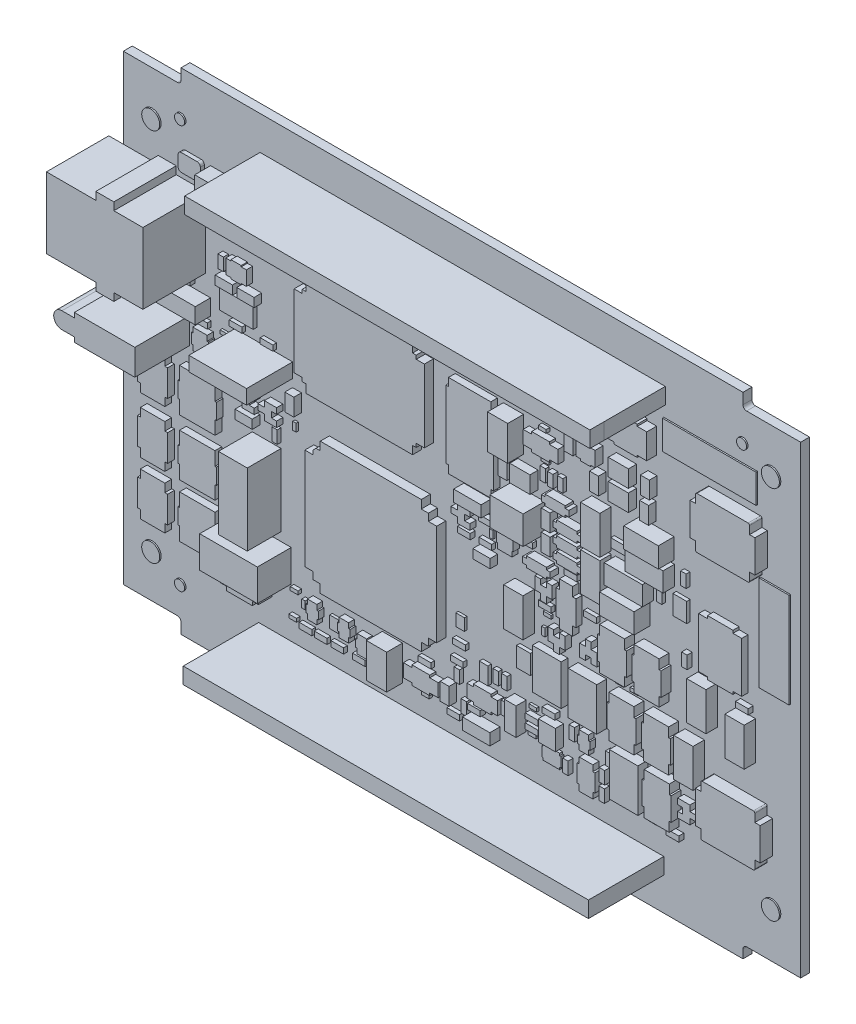
SolidWorks part; units mm, degrees
ref_plane "Front Plane" through (0, 0, 0) normal (0, 0, 1) x (1, 0, 0)
ref_plane "Top Plane" through (0, 0, 0) normal (0, 1, 0) x (1, 0, 0)
ref_plane "Right Plane" through (0, 0, 0) normal (1, 0, 0) x (0, 0, -1)
sketch "Sketch1" plane through (0, 0, 0) normal (0, 0, 1) x (1, 0, 0)
  line L0 (114.3, -8.001) -> (114.3, 73.787)
  line L1 (114.3, 73.787) -> (104.775, 73.787)
  line L2 (104.14, 74.422) -> (104.14, 76.327)
  line L3 (104.14, 76.327) -> (5.08, 76.327)
  line L4 (5.08, 76.327) -> (5.08, 74.422)
  line L5 (4.445, 73.787) -> (-5.08, 73.787)
  line L6 (-5.08, 73.787) -> (-5.08, -7.62)
  line L7 (-5.08, -7.62) -> (4.445, -7.62)
  line L8 (5.08, -8.255) -> (5.08, -10.16)
  line L9 (5.08, -10.16) -> (104.14, -10.16)
  line L10 (104.14, -10.16) -> (104.14, -8.636)
  line L11 (104.775, -8.001) -> (114.3, -8.001)
  arc A0 (104.775, 73.787) -> (104.14, 74.422) centre (104.775, 74.422) cw
  arc A1 (5.08, 74.422) -> (4.445, 73.787) centre (4.445, 74.422) cw
  arc A2 (4.445, -7.62) -> (5.08, -8.255) centre (4.445, -8.255) cw
  arc A3 (104.14, -8.636) -> (104.775, -8.001) centre (104.775, -8.636) cw
extrude "BOARD" add sketch "Sketch1" along normal blind 1.5748 separate body
sketch "Sketch2" plane through (0, 0, 0) normal (0, 0, 1) x (1, 0, 0)
  circle A0 centre (109.22, 0) radius 1.5875
  circle A1 centre (0, 66.04) radius 1.5875
  circle A2 centre (109.22, 66.04) radius 1.5875
  circle A3 centre (0, 0) radius 1.5875
extrude "NON-PLATED HOLES" cut sketch "Sketch2" along normal through all
ref_plane "Plane1" through (0, 0, 1.5748) normal (0, 0, 1) x (1, 0, 0)
sketch "Sketch3" plane through (0, 0, 1.5748) normal (0, 0, 1) x (1, 0, 0)
  line L0 (26.3398, 7.4168) -> (24.9682, 7.4168)
  line L1 (24.9682, 7.4168) -> (24.9682, 6.8072)
  line L2 (24.9682, 6.8072) -> (26.3398, 6.8072)
  line L3 (26.3398, 6.8072) -> (26.3398, 7.4168)
extrude "C_2_0402_PKO_Rev1-1" add sketch "Sketch3" along normal blind 0.635 separate body
sketch "Sketch4" plane through (0, 0, 0) normal (0, 0, 1) x (1, 0, 0)
  line L0 (93.0656, 4.7244) -> (90.8304, 4.7244)
  line L1 (90.8304, 4.7244) -> (90.8304, 5.6896)
  line L2 (90.8304, 5.6896) -> (93.0656, 5.6896)
  line L3 (93.0656, 5.6896) -> (93.0656, 4.7244)
extrude "C_2_0603_PKO_Rev1-1" add sketch "Sketch4" against normal blind 0.889 separate body
sketch "Sketch5" plane through (0, 0, 0) normal (0, 0, 1) x (1, 0, 0)
  line L0 (70.2056, 28.6766) -> (70.2056, 26.4414)
  line L1 (70.2056, 26.4414) -> (69.2404, 26.4414)
  line L2 (69.2404, 26.4414) -> (69.2404, 28.6766)
  line L3 (69.2404, 28.6766) -> (70.2056, 28.6766)
extrude "R_2_0603_PKO_Rev1-1" add sketch "Sketch5" against normal blind 0.6604 separate body
sketch "Sketch6" plane through (0, 0, 1.5748) normal (0, 0, 1) x (1, 0, 0)
  line L0 (88.973, 52.959) -> (88.973, 56.007)
  line L1 (88.973, 56.007) -> (87.3982, 56.007)
  line L2 (87.3982, 56.007) -> (87.3982, 52.959)
  line L3 (87.3982, 52.959) -> (88.973, 52.959)
extrude "C0805_Rev2-1" add sketch "Sketch6" along normal blind 1.3462 separate body
sketch "Sketch7" plane through (0, 0, 1.5748) normal (0, 0, 1) x (1, 0, 0)
  line L0 (90.193, -1.501) -> (18.773, -1.501)
  line L1 (18.773, -1.501) -> (18.773, -4.341)
  line L2 (18.773, -4.341) -> (90.193, -4.341)
  line L3 (90.193, -4.341) -> (90.193, -1.501)
extrude "HDRV28W69P254_28X1_7112X254P-1" add sketch "Sketch7" along normal blind 10.795 separate body
sketch "Sketch8" plane through (0, 0, 1.5748) normal (0, 0, 1) x (1, 0, 0)
  line L0 (78.486, 22.606) -> (79.502, 22.606)
  line L1 (79.502, 22.606) -> (79.502, 24.765)
  line L2 (79.502, 24.765) -> (78.486, 24.765)
  line L3 (78.486, 24.765) -> (78.486, 25.908)
  line L4 (78.486, 25.908) -> (77.47, 25.908)
  line L5 (77.47, 25.908) -> (77.47, 24.765)
  line L6 (77.47, 24.765) -> (76.454, 24.765)
  line L7 (76.454, 24.765) -> (76.454, 22.606)
  line L8 (76.454, 22.606) -> (77.47, 22.606)
  line L9 (77.47, 22.606) -> (77.47, 23.495)
  line L10 (77.47, 23.495) -> (78.486, 23.495)
  line L11 (78.486, 23.495) -> (78.486, 22.606)
extrude "SOT23_Rev1-1" add sketch "Sketch8" along normal blind 1.1176 separate body
sketch "Sketch9" plane through (0, 0, 1.5748) normal (0, 0, 1) x (1, 0, 0)
  line L0 (94.7819, 41.9989) -> (94.7819, 44.2341)
  line L1 (94.7819, 44.2341) -> (93.8167, 44.2341)
  line L2 (93.8167, 44.2341) -> (93.8167, 41.9989)
  line L3 (93.8167, 41.9989) -> (94.7819, 41.9989)
extrude "R_2_0603_PKO_Rev1-2" add sketch "Sketch9" along normal blind 0.6604 separate body
sketch "Sketch10" plane through (0, 0, 1.5748) normal (0, 0, 1) x (1, 0, 0)
  line L0 (69.5107, 6.3544) -> (72.5079, 6.3544)
  line L1 (72.5079, 6.3544) -> (72.5079, 9.9104)
  line L2 (72.5079, 9.9104) -> (69.5107, 9.9104)
  line L3 (69.5107, 9.9104) -> (69.5107, 6.3544)
extrude "SOT5_REV1-1" add sketch "Sketch10" along normal blind 1.4478 separate body
sketch "Sketch11" plane through (0, 0, 1.5748) normal (0, 0, 1) x (1, 0, 0)
  line L0 (92.8837, 6.0767) -> (93.2139, 6.0767)
  line L1 (93.2139, 6.0767) -> (93.2139, 10.1407)
  line L2 (93.2139, 10.1407) -> (92.9091, 10.1407)
  line L3 (92.9091, 10.1407) -> (92.9091, 11.7917)
  line L4 (92.9091, 11.7917) -> (88.4641, 11.7917)
  line L5 (88.4641, 11.7917) -> (88.4641, 10.1407)
  line L6 (88.4641, 10.1407) -> (88.1339, 10.1407)
  line L7 (88.1339, 10.1407) -> (88.1339, 6.0767)
  line L8 (88.1339, 6.0767) -> (88.4641, 6.0767)
  line L9 (88.4641, 6.0767) -> (88.4641, 4.4003)
  line L10 (88.4641, 4.4003) -> (92.8837, 4.4003)
  line L11 (92.8837, 4.4003) -> (92.8837, 6.0767)
extrude "SO8_REV1-1" add sketch "Sketch11" along normal blind 1.7526 separate body
sketch "Sketch12" plane through (0, 0, 1.5748) normal (0, 0, 1) x (1, 0, 0)
  line L0 (90.447, 70.381) -> (19.027, 70.381)
  line L1 (19.027, 70.381) -> (19.027, 67.541)
  line L2 (19.027, 67.541) -> (90.447, 67.541)
  line L3 (90.447, 67.541) -> (90.447, 70.381)
extrude "HDRV28W69P254_28X1_7112X254P-2" add sketch "Sketch12" along normal blind 10.795 separate body
sketch "Sketch13" plane through (0, 0, 1.5748) normal (0, 0, 1) x (1, 0, 0)
  line L0 (86.0298, 21.7678) -> (84.6582, 21.7678)
  line L1 (84.6582, 21.7678) -> (84.6582, 21.1582)
  line L2 (84.6582, 21.1582) -> (86.0298, 21.1582)
  line L3 (86.0298, 21.1582) -> (86.0298, 21.7678)
extrude "R_2_0402_PKO_Rev1-1" add sketch "Sketch13" along normal blind 0.4064 separate body
sketch "Sketch14" plane through (0, 0, 1.5748) normal (0, 0, 1) x (1, 0, 0)
  line L0 (13.7605, 40.1828) -> (12.3888, 40.1828)
  line L1 (12.3888, 40.1828) -> (12.3888, 39.5732)
  line L2 (12.3888, 39.5732) -> (13.7605, 39.5732)
  line L3 (13.7605, 39.5732) -> (13.7605, 40.1828)
extrude "R_2_0402_PKO_Rev1-2" add sketch "Sketch14" along normal blind 0.4064 separate body
sketch "Sketch15" plane through (0, 0, 0) normal (0, 0, 1) x (1, 0, 0)
  line L0 (42.4434, 59.1566) -> (44.6786, 59.1566)
  line L1 (44.6786, 59.1566) -> (44.6786, 58.1914)
  line L2 (44.6786, 58.1914) -> (42.4434, 58.1914)
  line L3 (42.4434, 58.1914) -> (42.4434, 59.1566)
extrude "C_2_0603_PKO_Rev1-2" add sketch "Sketch15" against normal blind 0.889 separate body
sketch "Sketch16" plane through (0, 0, 0) normal (0, 0, 1) x (1, 0, 0)
  line L0 (54.3611, 70.9193) -> (54.4119, 70.9193)
  line L1 (54.4119, 70.9193) -> (54.4119, 70.8685)
  line L2 (54.4119, 70.8685) -> (54.3611, 70.8685)
  line L3 (54.3611, 70.8685) -> (54.3611, 70.9193)
extrude "TP60-1" add sketch "Sketch16" against normal blind 0.254 separate body
sketch "Sketch17" plane through (0, 0, 0) normal (0, 0, 1) x (1, 0, 0)
  line L0 (27.0002, 59.2582) -> (27.0002, 60.6298)
  line L1 (27.0002, 60.6298) -> (27.6098, 60.6298)
  line L2 (27.6098, 60.6298) -> (27.6098, 59.2582)
  line L3 (27.6098, 59.2582) -> (27.0002, 59.2582)
extrude "C_2_0402_PKO_Rev1-2" add sketch "Sketch17" against normal blind 0.635 separate body
sketch "Sketch18" plane through (0, 0, 0) normal (0, 0, 1) x (1, 0, 0)
  line L0 (43.8607, 70.9193) -> (43.9115, 70.9193)
  line L1 (43.9115, 70.9193) -> (43.9115, 70.8685)
  line L2 (43.9115, 70.8685) -> (43.8607, 70.8685)
  line L3 (43.8607, 70.8685) -> (43.8607, 70.9193)
extrude "TP60-2" add sketch "Sketch18" against normal blind 0.254 separate body
sketch "Sketch19" plane through (0, 0, 0) normal (0, 0, 1) x (1, 0, 0)
  line L0 (81.6864, 61.8744) -> (81.6864, 64.1096)
  line L1 (81.6864, 64.1096) -> (82.6516, 64.1096)
  line L2 (82.6516, 64.1096) -> (82.6516, 61.8744)
  line L3 (82.6516, 61.8744) -> (81.6864, 61.8744)
extrude "C_2_0603_PKO_Rev1-3" add sketch "Sketch19" against normal blind 0.889 separate body
sketch "Sketch20" plane through (0, 0, 0) normal (0, 0, 1) x (1, 0, 0)
  line L0 (75.3618, 70.9193) -> (75.4126, 70.9193)
  line L1 (75.4126, 70.9193) -> (75.4126, 70.8685)
  line L2 (75.4126, 70.8685) -> (75.3618, 70.8685)
  line L3 (75.3618, 70.8685) -> (75.3618, 70.9193)
extrude "TP60-3" add sketch "Sketch20" against normal blind 0.254 separate body
sketch "Sketch21" plane through (0, 0, 1.5748) normal (0, 0, 1) x (1, 0, 0)
  line L0 (14.0422, 38.9006) -> (12.3611, 38.9006)
  line L1 (12.3611, 38.9006) -> (12.3611, 38.0111)
  line L2 (12.3611, 38.0111) -> (12.0967, 38.0111)
  line L3 (12.0967, 38.0111) -> (12.0967, 36.6649)
  line L4 (12.0967, 36.6649) -> (12.3611, 36.6649)
  line L5 (12.3611, 36.6649) -> (12.3611, 35.7754)
  line L6 (12.3611, 35.7754) -> (14.0422, 35.7754)
  line L7 (14.0422, 35.7754) -> (14.0422, 36.6649)
  line L8 (14.0422, 36.6649) -> (14.3065, 36.6649)
  line L9 (14.3065, 36.6649) -> (14.3065, 38.0111)
  line L10 (14.3065, 38.0111) -> (14.0422, 38.0111)
  line L11 (14.0422, 38.0111) -> (14.0422, 38.9006)
extrude "SOT363_Rev2-1" add sketch "Sketch21" along normal blind 1.016 separate body
sketch "Sketch22" plane through (0, 0, 0) normal (0, 0, 1) x (1, 0, 0)
  line L0 (1.651, 7.3406) -> (-1.397, 7.3406)
  line L1 (-1.397, 7.3406) -> (-1.397, 8.9154)
  line L2 (-1.397, 8.9154) -> (1.651, 8.9154)
  line L3 (1.651, 8.9154) -> (1.651, 7.3406)
extrude "C0805_Rev2-2" add sketch "Sketch22" against normal blind 1.3462 separate body
sketch "Sketch23" plane through (0, 0, 1.5748) normal (0, 0, 1) x (1, 0, 0)
  line L0 (25.864, -10.204) -> (43.364, -10.204)
  line L1 (43.364, -10.204) -> (43.364, -3.004)
  line L2 (43.364, -3.004) -> (25.864, -3.004)
  line L3 (25.864, -3.004) -> (25.864, -10.204)
sketch "Sketch24" plane through (0, 0, 1.5748) normal (0, 0, 1) x (1, 0, 0)
  line L0 (56.4976, 1.8228) -> (61.3236, 1.8228)
  line L1 (61.3236, 1.8228) -> (61.3236, 3.8548)
  line L2 (61.3236, 3.8548) -> (56.4976, 3.8548)
  line L3 (56.4976, 3.8548) -> (56.4976, 1.8228)
extrude "C3216_Rev1-1" add sketch "Sketch24" along normal blind 1.8034 separate body
sketch "Sketch25" plane through (0, 0, 1.5748) normal (0, 0, 1) x (1, 0, 0)
  line L0 (71.4883, 35.4965) -> (71.4883, 38.5445)
  line L1 (71.4883, 38.5445) -> (69.9135, 38.5445)
  line L2 (69.9135, 38.5445) -> (69.9135, 35.4965)
  line L3 (69.9135, 35.4965) -> (71.4883, 35.4965)
extrude "C0805_Rev2-3" add sketch "Sketch25" along normal blind 1.3462 separate body
sketch "Sketch26" plane through (0, 0, 1.5748) normal (0, 0, 1) x (1, 0, 0)
  line L0 (77.5081, 47.2313) -> (77.5081, 40.5003)
  line L1 (77.5081, 40.5003) -> (80.9117, 40.5003)
  line L2 (80.9117, 40.5003) -> (80.9117, 47.2313)
  line L3 (80.9117, 47.2313) -> (77.5081, 47.2313)
extrude "C2312_Rev2-1" add sketch "Sketch26" along normal blind 2.0066 separate body
sketch "Sketch27" plane through (0, 0, 0) normal (0, 0, 1) x (1, 0, 0)
  line L0 (81.153, 28.321) -> (84.709, 28.321)
  line L1 (84.709, 28.321) -> (84.709, 25.781)
  line L2 (84.709, 25.781) -> (81.153, 25.781)
  line L3 (81.153, 25.781) -> (81.153, 28.321)
extrude "710163-1" add sketch "Sketch27" against normal blind 0.508 separate body
sketch "Sketch28" plane through (0, 0, 1.5748) normal (0, 0, 1) x (1, 0, 0)
  line L0 (72.7329, 35.2171) -> (76.2889, 35.2171)
  line L1 (76.2889, 35.2171) -> (76.2889, 35.6235)
  line L2 (76.2889, 35.6235) -> (76.9239, 35.6235)
  line L3 (76.9239, 35.6235) -> (76.9239, 36.6395)
  line L4 (76.9239, 36.6395) -> (76.2889, 36.6395)
  line L5 (76.2889, 36.6395) -> (76.2889, 37.0459)
  line L6 (76.2889, 37.0459) -> (72.7329, 37.0459)
  line L7 (72.7329, 37.0459) -> (72.7329, 36.6395)
  line L8 (72.7329, 36.6395) -> (72.0979, 36.6395)
  line L9 (72.0979, 36.6395) -> (72.0979, 35.6235)
  line L10 (72.0979, 35.6235) -> (72.7329, 35.6235)
  line L11 (72.7329, 35.6235) -> (72.7329, 35.2171)
extrude "CR_2_SOD123_REV2-1" add sketch "Sketch28" along normal blind 1.4478 separate body
sketch "Sketch29" plane through (0, 0, 1.5748) normal (0, 0, 1) x (1, 0, 0)
  line L0 (81.4705, 41.5925) -> (84.5185, 41.5925)
  line L1 (84.5185, 41.5925) -> (84.5185, 43.1165)
  line L2 (84.5185, 43.1165) -> (81.4705, 43.1165)
  line L3 (81.4705, 43.1165) -> (81.4705, 41.5925)
extrude "R0805_Rev1-1" add sketch "Sketch29" along normal blind 0.635 separate body
sketch "Sketch30" plane through (0, 0, 0) normal (0, 0, 1) x (1, 0, 0)
  line L0 (33.3502, 12.192) -> (33.3502, 17.526)
  line L1 (33.3502, 17.526) -> (36.4998, 17.526)
  line L2 (36.4998, 17.526) -> (36.4998, 12.192)
  line L3 (36.4998, 12.192) -> (33.3502, 12.192)
extrude "C3528_Rev2-1" add sketch "Sketch30" against normal blind 1.905 separate body
sketch "Sketch31" plane through (0, 0, 1.5748) normal (0, 0, 1) x (1, 0, 0)
  line L0 (65.9372, 5.4229) -> (65.9372, 10.2489)
  line L1 (65.9372, 10.2489) -> (63.9052, 10.2489)
  line L2 (63.9052, 10.2489) -> (63.9052, 5.4229)
  line L3 (63.9052, 5.4229) -> (65.9372, 5.4229)
extrude "C3216_Rev1-2" add sketch "Sketch31" along normal blind 1.8034 separate body
sketch "Sketch32" plane through (0, 0, 0) normal (0, 0, 1) x (1, 0, 0)
  line L0 (45.5422, 10.1092) -> (45.5422, 11.4808)
  line L1 (45.5422, 11.4808) -> (46.1518, 11.4808)
  line L2 (46.1518, 11.4808) -> (46.1518, 10.1092)
  line L3 (46.1518, 10.1092) -> (45.5422, 10.1092)
extrude "C_2_0402_PKO_Rev1-3" add sketch "Sketch32" against normal blind 0.635 separate body
sketch "Sketch33" plane through (0, 0, 0) normal (0, 0, 1) x (1, 0, 0)
  line L0 (36.8681, 47.4091) -> (36.8681, 45.1739)
  line L1 (36.8681, 45.1739) -> (35.9029, 45.1739)
  line L2 (35.9029, 45.1739) -> (35.9029, 47.4091)
  line L3 (35.9029, 47.4091) -> (36.8681, 47.4091)
extrude "R_2_0603_PKO_Rev1-3" add sketch "Sketch33" against normal blind 0.6604 separate body
sketch "Sketch34" plane through (0, 0, 1.5748) normal (0, 0, 1) x (1, 0, 0)
  circle A0 centre (5.08, 68.58) radius 0.889
extrude "FD70-1" add sketch "Sketch34" along normal blind 0.254 separate body
sketch "Sketch35" plane through (0, 0, 0) normal (0, 0, 1) x (1, 0, 0)
  line L0 (32.7279, 51.7779) -> (32.7279, 54.0131)
  line L1 (32.7279, 54.0131) -> (33.6931, 54.0131)
  line L2 (33.6931, 54.0131) -> (33.6931, 51.7779)
  line L3 (33.6931, 51.7779) -> (32.7279, 51.7779)
extrude "R_2_0603_PKO_Rev1-4" add sketch "Sketch35" against normal blind 0.6604 separate body
sketch "Sketch36" plane through (0, 0, 0) normal (0, 0, 1) x (1, 0, 0)
  line L0 (21.4503, 6.477) -> (21.4503, 6.6802)
  line L1 (21.4503, 6.6802) -> (23.2537, 6.6802)
  line L2 (23.2537, 6.6802) -> (23.2537, 6.477)
  line L3 (23.2537, 6.477) -> (24.1554, 6.477)
  line L4 (24.1554, 6.477) -> (24.1554, 3.937)
  line L5 (24.1554, 3.937) -> (23.2537, 3.937)
  line L6 (23.2537, 3.937) -> (23.2537, 3.7338)
  line L7 (23.2537, 3.7338) -> (21.4503, 3.7338)
  line L8 (21.4503, 3.7338) -> (21.4503, 3.937)
  line L9 (21.4503, 3.937) -> (20.5486, 3.937)
  line L10 (20.5486, 3.937) -> (20.5486, 6.477)
  line L11 (20.5486, 6.477) -> (21.4503, 6.477)
extrude "SOT6_Rev1-1" add sketch "Sketch36" against normal blind 1.0922 separate body
sketch "Sketch37" plane through (0, 0, 1.5748) normal (0, 0, 1) x (1, 0, 0)
  line L0 (81.6737, 36.6903) -> (88.4047, 36.6903)
  line L1 (88.4047, 36.6903) -> (88.4047, 40.0939)
  line L2 (88.4047, 40.0939) -> (81.6737, 40.0939)
  line L3 (81.6737, 40.0939) -> (81.6737, 36.6903)
extrude "C2312_Rev2-2" add sketch "Sketch37" along normal blind 2.0066 separate body
sketch "Sketch38" plane through (0, 0, 1.5748) normal (0, 0, 1) x (1, 0, 0)
  line L0 (55.495, 15.714) -> (55.495, 17.814)
  line L1 (55.495, 17.814) -> (53.979, 17.814)
  line L2 (53.979, 17.814) -> (53.979, 15.714)
  line L3 (53.979, 15.714) -> (55.495, 15.714)
extrude "RN_8_2010_0.50MM_Rev3-1" add sketch "Sketch38" along normal blind 0.4572 separate body
sketch "Sketch39" plane through (0, 0, 1.5748) normal (0, 0, 1) x (1, 0, 0)
  line L0 (44.1261, 1.9431) -> (44.1261, 8.0391)
  line L1 (44.1261, 8.0391) -> (40.5701, 8.0391)
  line L2 (40.5701, 8.0391) -> (40.5701, 1.9431)
  line L3 (40.5701, 1.9431) -> (44.1261, 1.9431)
extrude "LQH4NS_Rev1_KEEP-OUTS-1" add sketch "Sketch39" along normal blind 2.794 separate body
sketch "Sketch40" plane through (0, 0, 1.5748) normal (0, 0, 1) x (1, 0, 0)
  line L0 (65.4621, 47.5234) -> (65.4621, 53.6194)
  line L1 (65.4621, 53.6194) -> (61.9061, 53.6194)
  line L2 (61.9061, 53.6194) -> (61.9061, 47.5234)
  line L3 (61.9061, 47.5234) -> (65.4621, 47.5234)
extrude "LQH4NS_Rev1_KEEP-OUTS-2" add sketch "Sketch40" along normal blind 2.794 separate body
sketch "Sketch42" plane through (0, 0, 0) normal (0, 0, 1) x (1, 0, 0)
  line L0 (74.7395, 60.0075) -> (76.6445, 60.0075)
  line L1 (76.6445, 60.0075) -> (76.6445, 58.8645)
  line L2 (76.6445, 58.8645) -> (76.7969, 58.8645)
  line L3 (76.7969, 58.8645) -> (76.7969, 57.8739)
  line L4 (76.7969, 57.8739) -> (76.0095, 57.8739)
  line L5 (76.0095, 57.8739) -> (76.0095, 57.0865)
  line L6 (76.0095, 57.0865) -> (75.3745, 57.0865)
  line L7 (75.3745, 57.0865) -> (75.3745, 57.8739)
  line L8 (75.3745, 57.8739) -> (74.5871, 57.8739)
  line L9 (74.5871, 57.8739) -> (74.5871, 58.8645)
  line L10 (74.5871, 58.8645) -> (74.7395, 58.8645)
  line L11 (74.7395, 58.8645) -> (74.7395, 60.0075)
extrude "SOT323_Rev1-1" add sketch "Sketch42" against normal blind 1.0922 separate body
sketch "Sketch43" plane through (0, 0, 1.5748) normal (0, 0, 1) x (1, 0, 0)
  circle A0 centre (109.22, 0) radius 1.5875
extrude "TL125-1" add sketch "Sketch43" along normal blind 0.254 separate body
sketch "Sketch44" plane through (0, 0, 1.5748) normal (0, 0, 1) x (1, 0, 0)
  circle A0 centre (0, 66.04) radius 1.5875
extrude "TL125-2" add sketch "Sketch44" along normal blind 0.254 separate body
sketch "Sketch45" plane through (0, 0, 0) normal (0, 0, 1) x (1, 0, 0)
  line L0 (46.0502, 39.1922) -> (46.0502, 40.5638)
  line L1 (46.0502, 40.5638) -> (46.6598, 40.5638)
  line L2 (46.6598, 40.5638) -> (46.6598, 39.1922)
  line L3 (46.6598, 39.1922) -> (46.0502, 39.1922)
extrude "C_2_0402_PKO_Rev1-4" add sketch "Sketch45" against normal blind 0.635 separate body
sketch "Sketch46" plane through (0, 0, 1.5748) normal (0, 0, 1) x (1, 0, 0)
  line L0 (88.846, 49.022) -> (88.846, 52.07)
  line L1 (88.846, 52.07) -> (87.2712, 52.07)
  line L2 (87.2712, 52.07) -> (87.2712, 49.022)
  line L3 (87.2712, 49.022) -> (88.846, 49.022)
extrude "C0805_Rev2-4" add sketch "Sketch46" along normal blind 1.3462 separate body
sketch "Sketch47" plane through (0, 0, 1.5748) normal (0, 0, 1) x (1, 0, 0)
  line L0 (27.0002, 6.5278) -> (27.0002, 5.1562)
  line L1 (27.0002, 5.1562) -> (27.6098, 5.1562)
  line L2 (27.6098, 5.1562) -> (27.6098, 6.5278)
  line L3 (27.6098, 6.5278) -> (27.0002, 6.5278)
extrude "C_2_0402_PKO_Rev1-5" add sketch "Sketch47" along normal blind 0.635 separate body
sketch "Sketch48" plane through (0, 0, 1.5748) normal (0, 0, 1) x (1, 0, 0)
  line L0 (69.596, 31.115) -> (68.58, 31.115)
  line L1 (68.58, 31.115) -> (68.58, 28.956)
  line L2 (68.58, 28.956) -> (69.596, 28.956)
  line L3 (69.596, 28.956) -> (69.596, 27.813)
  line L4 (69.596, 27.813) -> (70.612, 27.813)
  line L5 (70.612, 27.813) -> (70.612, 28.956)
  line L6 (70.612, 28.956) -> (71.628, 28.956)
  line L7 (71.628, 28.956) -> (71.628, 31.115)
  line L8 (71.628, 31.115) -> (70.612, 31.115)
  line L9 (70.612, 31.115) -> (70.612, 30.226)
  line L10 (70.612, 30.226) -> (69.596, 30.226)
  line L11 (69.596, 30.226) -> (69.596, 31.115)
extrude "SOT23_Rev1-2" add sketch "Sketch48" along normal blind 1.1176 separate body
sketch "Sketch49" plane through (0, 0, 0) normal (0, 0, 1) x (1, 0, 0)
  line L0 (38.2778, 32.9438) -> (38.2778, 31.5722)
  line L1 (38.2778, 31.5722) -> (37.6682, 31.5722)
  line L2 (37.6682, 31.5722) -> (37.6682, 32.9438)
  line L3 (37.6682, 32.9438) -> (38.2778, 32.9438)
extrude "C_2_0402_PKO_Rev1-6" add sketch "Sketch49" against normal blind 0.635 separate body
sketch "Sketch50" plane through (0, 0, 1.5748) normal (0, 0, 1) x (1, 0, 0)
  line L0 (53.2384, 10.1854) -> (55.4736, 10.1854)
  line L1 (55.4736, 10.1854) -> (55.4736, 11.1506)
  line L2 (55.4736, 11.1506) -> (53.2384, 11.1506)
  line L3 (53.2384, 11.1506) -> (53.2384, 10.1854)
extrude "R_2_0603_PKO_Rev1-5" add sketch "Sketch50" along normal blind 0.6604 separate body
sketch "Sketch51" plane through (0, 0, 1.5748) normal (0, 0, 1) x (1, 0, 0)
  line L0 (82.9374, 76.244) -> (61.9374, 76.244)
  line L1 (61.9374, 76.244) -> (61.9374, 69.044)
  line L2 (61.9374, 69.044) -> (82.9374, 69.044)
  line L3 (82.9374, 69.044) -> (82.9374, 76.244)
sketch "Sketch52" plane through (0, 0, 0) normal (0, 0, 1) x (1, 0, 0)
  line L0 (36.8605, 70.9193) -> (36.9113, 70.9193)
  line L1 (36.9113, 70.9193) -> (36.9113, 70.8685)
  line L2 (36.9113, 70.8685) -> (36.8605, 70.8685)
  line L3 (36.8605, 70.8685) -> (36.8605, 70.9193)
extrude "TP60-4" add sketch "Sketch52" against normal blind 0.254 separate body
sketch "Sketch53" plane through (0, 0, 1.5748) normal (0, 0, 1) x (1, 0, 0)
  circle A0 centre (104.14, 68.58) radius 0.889
extrude "FD70-2" add sketch "Sketch53" along normal blind 0.254 separate body
sketch "Sketch54" plane through (0, 0, 0) normal (0, 0, 1) x (1, 0, 0)
  line L0 (39.5732, 10.1092) -> (39.5732, 11.4808)
  line L1 (39.5732, 11.4808) -> (40.1828, 11.4808)
  line L2 (40.1828, 11.4808) -> (40.1828, 10.1092)
  line L3 (40.1828, 10.1092) -> (39.5732, 10.1092)
extrude "C_2_0402_PKO_Rev1-7" add sketch "Sketch54" against normal blind 0.635 separate body
sketch "Sketch55" plane through (0, 0, 0) normal (0, 0, 1) x (1, 0, 0)
  line L0 (37.5158, 5.5118) -> (37.5158, 4.1402)
  line L1 (37.5158, 4.1402) -> (36.9062, 4.1402)
  line L2 (36.9062, 4.1402) -> (36.9062, 5.5118)
  line L3 (36.9062, 5.5118) -> (37.5158, 5.5118)
extrude "C_2_0402_PKO_Rev1-8" add sketch "Sketch55" against normal blind 0.635 separate body
sketch "Sketch56" plane through (0, 0, 1.5748) normal (0, 0, 1) x (1, 0, 0)
  line L0 (8.2486, 37.9857) -> (8.0454, 37.9857)
  line L1 (8.0454, 37.9857) -> (8.0454, 36.1823)
  line L2 (8.0454, 36.1823) -> (8.2486, 36.1823)
  line L3 (8.2486, 36.1823) -> (8.2486, 35.2806)
  line L4 (8.2486, 35.2806) -> (10.7886, 35.2806)
  line L5 (10.7886, 35.2806) -> (10.7886, 36.1823)
  line L6 (10.7886, 36.1823) -> (10.9918, 36.1823)
  line L7 (10.9918, 36.1823) -> (10.9918, 37.9857)
  line L8 (10.9918, 37.9857) -> (10.7886, 37.9857)
  line L9 (10.7886, 37.9857) -> (10.7886, 38.8874)
  line L10 (10.7886, 38.8874) -> (8.2486, 38.8874)
  line L11 (8.2486, 38.8874) -> (8.2486, 37.9857)
extrude "SOT6_Rev1-2" add sketch "Sketch56" along normal blind 1.0922 separate body
sketch "Sketch57" plane through (0, 0, 0) normal (0, 0, 1) x (1, 0, 0)
  line L0 (49.1236, 44.4754) -> (46.8884, 44.4754)
  line L1 (46.8884, 44.4754) -> (46.8884, 45.4406)
  line L2 (46.8884, 45.4406) -> (49.1236, 45.4406)
  line L3 (49.1236, 45.4406) -> (49.1236, 44.4754)
extrude "R_2_0603_PKO_Rev1-6" add sketch "Sketch57" against normal blind 0.6604 separate body
sketch "Sketch58" plane through (0, 0, 1.5748) normal (0, 0, 1) x (1, 0, 0)
  line L0 (76.7037, 60.973) -> (74.9427, 60.973)
  line L1 (74.9427, 60.973) -> (74.943, 60.7734)
  line L2 (74.943, 60.7734) -> (74.5617, 60.7696)
  line L3 (74.5617, 60.7696) -> (74.5617, 57.8485)
  line L4 (74.5617, 57.8485) -> (74.9427, 57.8485)
  line L5 (74.9427, 57.8485) -> (74.9427, 57.6199)
  line L6 (74.9427, 57.6199) -> (76.7037, 57.6199)
  line L7 (76.7037, 57.6199) -> (76.7037, 57.8485)
  line L8 (76.7037, 57.8485) -> (77.0763, 57.8485)
  line L9 (77.0763, 57.8485) -> (77.0763, 60.7642)
  line L10 (77.0763, 60.7642) -> (76.7037, 60.7642)
  line L11 (76.7037, 60.7642) -> (76.7037, 60.973)
extrude "SM1206_Rev2-1" add sketch "Sketch58" along normal blind 0.508 separate body
sketch "Sketch59" plane through (0, 0, 1.5748) normal (0, 0, 1) x (1, 0, 0)
  line L0 (33.6296, 61.4934) -> (33.6296, 63.7286)
  line L1 (33.6296, 63.7286) -> (32.6644, 63.7286)
  line L2 (32.6644, 63.7286) -> (32.6644, 61.4934)
  line L3 (32.6644, 61.4934) -> (33.6296, 61.4934)
extrude "R_2_0603_PKO_Rev1-7" add sketch "Sketch59" along normal blind 0.6604 separate body
sketch "Sketch60" plane through (0, 0, 0) normal (0, 0, 1) x (1, 0, 0)
  line L0 (30.7086, 20.3454) -> (28.4734, 20.3454)
  line L1 (28.4734, 20.3454) -> (28.4734, 21.3106)
  line L2 (28.4734, 21.3106) -> (30.7086, 21.3106)
  line L3 (30.7086, 21.3106) -> (30.7086, 20.3454)
extrude "R_2_0603_PKO_Rev1-8" add sketch "Sketch60" against normal blind 0.6604 separate body
sketch "Sketch61" plane through (0, 0, 0) normal (0, 0, 1) x (1, 0, 0)
  line L0 (35.5092, 10.1092) -> (35.5092, 11.4808)
  line L1 (35.5092, 11.4808) -> (36.1188, 11.4808)
  line L2 (36.1188, 11.4808) -> (36.1188, 10.1092)
  line L3 (36.1188, 10.1092) -> (35.5092, 10.1092)
extrude "C_2_0402_PKO_Rev1-9" add sketch "Sketch61" against normal blind 0.635 separate body
sketch "Sketch62" plane through (0, 0, 0) normal (0, 0, 1) x (1, 0, 0)
  line L0 (89.0016, 28.8544) -> (86.7664, 28.8544)
  line L1 (86.7664, 28.8544) -> (86.7664, 29.8196)
  line L2 (86.7664, 29.8196) -> (89.0016, 29.8196)
  line L3 (89.0016, 29.8196) -> (89.0016, 28.8544)
extrude "C_2_0603_PKO_Rev1-4" add sketch "Sketch62" against normal blind 0.889 separate body
sketch "Sketch63" plane through (0, 0, 0) normal (0, 0, 1) x (1, 0, 0)
  line L0 (82.1436, 17.8816) -> (82.1436, 15.6464)
  line L1 (82.1436, 15.6464) -> (81.1784, 15.6464)
  line L2 (81.1784, 15.6464) -> (81.1784, 17.8816)
  line L3 (81.1784, 17.8816) -> (82.1436, 17.8816)
extrude "C_2_0603_PKO_Rev1-5" add sketch "Sketch63" against normal blind 0.889 separate body
sketch "Sketch64" plane through (0, 0, 1.5748) normal (0, 0, 1) x (1, 0, 0)
  line L0 (14.6177, 64.0016) -> (14.6177, 57.9056)
  line L1 (14.6177, 57.9056) -> (18.1737, 57.9056)
  line L2 (18.1737, 57.9056) -> (18.1737, 64.0016)
  line L3 (18.1737, 64.0016) -> (14.6177, 64.0016)
extrude "LQH4NS_Rev1_KEEP-OUTS-3" add sketch "Sketch64" along normal blind 2.794 separate body
sketch "Sketch65" plane through (0, 0, 0) normal (0, 0, 1) x (1, 0, 0)
  line L0 (15.3162, 6.5278) -> (16.6878, 6.5278)
  line L1 (16.6878, 6.5278) -> (16.6878, 5.9182)
  line L2 (16.6878, 5.9182) -> (15.3162, 5.9182)
  line L3 (15.3162, 5.9182) -> (15.3162, 6.5278)
extrude "C_2_0402_PKO_Rev1-10" add sketch "Sketch65" against normal blind 0.635 separate body
sketch "Sketch67" plane through (0, 0, 0) normal (0, 0, 1) x (1, 0, 0)
  line L0 (12.1475, 57.3532) -> (12.1476, 64.0842)
  line L1 (12.1476, 64.0842) -> (15.5511, 64.0842)
  line L2 (15.5511, 64.0842) -> (15.5511, 57.3532)
  line L3 (15.5511, 57.3532) -> (12.1475, 57.3532)
extrude "C2312_Rev2-3" add sketch "Sketch67" against normal blind 2.0066 separate body
sketch "Sketch68" plane through (0, 0, 0) normal (0, 0, 1) x (1, 0, 0)
  line L0 (29.9212, 39.1922) -> (29.9212, 40.5638)
  line L1 (29.9212, 40.5638) -> (30.5308, 40.5638)
  line L2 (30.5308, 40.5638) -> (30.5308, 39.1922)
  line L3 (30.5308, 39.1922) -> (29.9212, 39.1922)
extrude "C_2_0402_PKO_Rev1-11" add sketch "Sketch68" against normal blind 0.635 separate body
sketch "Sketch69" plane through (0, 0, 0) normal (0, 0, 1) x (1, 0, 0)
  line L0 (82.677, 18.034) -> (86.233, 18.034)
  line L1 (86.233, 18.034) -> (86.233, 15.494)
  line L2 (86.233, 15.494) -> (82.677, 15.494)
  line L3 (82.677, 15.494) -> (82.677, 18.034)
extrude "710163-2" add sketch "Sketch69" against normal blind 0.508 separate body
sketch "Sketch70" plane through (0, 0, 1.5748) normal (0, 0, 1) x (1, 0, 0)
  line L0 (73.2371, 5.5021) -> (73.2371, 3.2669)
  line L1 (73.2371, 3.2669) -> (74.2023, 3.2669)
  line L2 (74.2023, 3.2669) -> (74.2023, 5.5021)
  line L3 (74.2023, 5.5021) -> (73.2371, 5.5021)
extrude "C_2_0603_PKO_Rev1-6" add sketch "Sketch70" along normal blind 0.889 separate body
sketch "Sketch71" plane through (0, 0, 1.5748) normal (0, 0, 1) x (1, 0, 0)
  line L0 (51.8414, 61.5696) -> (51.8414, 59.3344)
  line L1 (51.8414, 59.3344) -> (52.8066, 59.3344)
  line L2 (52.8066, 59.3344) -> (52.8066, 61.5696)
  line L3 (52.8066, 61.5696) -> (51.8414, 61.5696)
extrude "C_2_0603_PKO_Rev1-7" add sketch "Sketch71" along normal blind 0.889 separate body
sketch "Sketch72" plane through (0, 0, 0) normal (0, 0, 1) x (1, 0, 0)
  line L0 (9.745, 22.094) -> (11.845, 22.094)
  line L1 (11.845, 22.094) -> (11.845, 20.578)
  line L2 (11.845, 20.578) -> (9.745, 20.578)
  line L3 (9.745, 20.578) -> (9.745, 22.094)
extrude "RN_8_2010_0.50MM_Rev3-2" add sketch "Sketch72" against normal blind 0.4572 separate body
sketch "Sketch73" plane through (0, 0, 0) normal (0, 0, 1) x (1, 0, 0)
  line L0 (83.5914, 7.0104) -> (83.5914, 9.2456)
  line L1 (83.5914, 9.2456) -> (84.5566, 9.2456)
  line L2 (84.5566, 9.2456) -> (84.5566, 7.0104)
  line L3 (84.5566, 7.0104) -> (83.5914, 7.0104)
extrude "C_2_0603_PKO_Rev1-8" add sketch "Sketch73" against normal blind 0.889 separate body
sketch "Sketch74" plane through (0, 0, 1.5748) normal (0, 0, 1) x (1, 0, 0)
  line L0 (74.2569, 44.7929) -> (70.7009, 44.7929)
  line L1 (70.7009, 44.7929) -> (70.7009, 44.3865)
  line L2 (70.7009, 44.3865) -> (70.0659, 44.3865)
  line L3 (70.0659, 44.3865) -> (70.0659, 43.3705)
  line L4 (70.0659, 43.3705) -> (70.7009, 43.3705)
  line L5 (70.7009, 43.3705) -> (70.7009, 42.9641)
  line L6 (70.7009, 42.9641) -> (74.2569, 42.9641)
  line L7 (74.2569, 42.9641) -> (74.2569, 43.3705)
  line L8 (74.2569, 43.3705) -> (74.8919, 43.3705)
  line L9 (74.8919, 43.3705) -> (74.8919, 44.3865)
  line L10 (74.8919, 44.3865) -> (74.2569, 44.3865)
  line L11 (74.2569, 44.3865) -> (74.2569, 44.7929)
extrude "CR_2_SOD123_REV2-2" add sketch "Sketch74" along normal blind 1.4478 separate body
sketch "Sketch75" plane through (0, 0, 1.5748) normal (0, 0, 1) x (1, 0, 0)
  line L0 (67.7291, 35.4457) -> (65.4939, 35.4457)
  line L1 (65.4939, 35.4457) -> (65.4939, 34.4805)
  line L2 (65.4939, 34.4805) -> (67.7291, 34.4805)
  line L3 (67.7291, 34.4805) -> (67.7291, 35.4457)
extrude "R_2_0603_PKO_Rev1-9" add sketch "Sketch75" along normal blind 0.6604 separate body
sketch "Sketch76" plane through (0, 0, 0) normal (0, 0, 1) x (1, 0, 0)
  line L0 (47.1678, 56.1848) -> (47.1678, 54.8132)
  line L1 (47.1678, 54.8132) -> (46.5582, 54.8132)
  line L2 (46.5582, 54.8132) -> (46.5582, 56.1848)
  line L3 (46.5582, 56.1848) -> (47.1678, 56.1848)
extrude "C_2_0402_PKO_Rev1-12" add sketch "Sketch76" against normal blind 0.635 separate body
sketch "Sketch77" plane through (0, 0, 0) normal (0, 0, 1) x (1, 0, 0)
  line L0 (46.3804, 35.4584) -> (46.3804, 37.6936)
  line L1 (46.3804, 37.6936) -> (47.3456, 37.6936)
  line L2 (47.3456, 37.6936) -> (47.3456, 35.4584)
  line L3 (47.3456, 35.4584) -> (46.3804, 35.4584)
extrude "R_2_0603_PKO_Rev1-10" add sketch "Sketch77" against normal blind 0.6604 separate body
sketch "Sketch78" plane through (0, 0, 0) normal (0, 0, 1) x (1, 0, 0)
  line L0 (25.4762, 35.1282) -> (25.4762, 36.4998)
  line L1 (25.4762, 36.4998) -> (26.0858, 36.4998)
  line L2 (26.0858, 36.4998) -> (26.0858, 35.1282)
  line L3 (26.0858, 35.1282) -> (25.4762, 35.1282)
extrude "C_2_0402_PKO_Rev1-13" add sketch "Sketch78" against normal blind 0.635 separate body
sketch "Sketch79" plane through (0, 0, 1.5748) normal (0, 0, 1) x (1, 0, 0)
  line L0 (92.7608, 14.732) -> (93.091, 14.732)
  line L1 (93.091, 14.732) -> (93.091, 18.796)
  line L2 (93.091, 18.796) -> (92.7862, 18.796)
  line L3 (92.7862, 18.796) -> (92.7862, 20.447)
  line L4 (92.7862, 20.447) -> (88.3412, 20.447)
  line L5 (88.3412, 20.447) -> (88.3412, 18.796)
  line L6 (88.3412, 18.796) -> (88.011, 18.796)
  line L7 (88.011, 18.796) -> (88.011, 14.732)
  line L8 (88.011, 14.732) -> (88.3412, 14.732)
  line L9 (88.3412, 14.732) -> (88.3412, 13.0556)
  line L10 (88.3412, 13.0556) -> (92.7608, 13.0556)
  line L11 (92.7608, 13.0556) -> (92.7608, 14.732)
extrude "SO8_REV1-2" add sketch "Sketch79" along normal blind 1.7526 separate body
sketch "Sketch80" plane through (0, 0, 1.5748) normal (0, 0, 1) x (1, 0, 0)
  line L0 (80.01, 49.0791) -> (80.01, 52.1271)
  line L1 (80.01, 52.1271) -> (78.4352, 52.1271)
  line L2 (78.4352, 52.1271) -> (78.4352, 49.0791)
  line L3 (78.4352, 49.0791) -> (80.01, 49.0791)
extrude "C0805_Rev2-5" add sketch "Sketch80" along normal blind 1.3462 separate body
sketch "Sketch81" plane through (0, 0, 0) normal (0, 0, 1) x (1, 0, 0)
  line L0 (39.3446, 12.8524) -> (37.1094, 12.8524)
  line L1 (37.1094, 12.8524) -> (37.1094, 13.8176)
  line L2 (37.1094, 13.8176) -> (39.3446, 13.8176)
  line L3 (39.3446, 13.8176) -> (39.3446, 12.8524)
extrude "BLM11_REV1-1" add sketch "Sketch81" against normal blind 0.9398 separate body
sketch "Sketch82" plane through (0, 0, 0) normal (0, 0, 1) x (1, 0, 0)
  line L0 (79.4512, 59.1058) -> (86.1822, 59.1058)
  line L1 (86.1822, 59.1058) -> (86.1822, 55.7022)
  line L2 (86.1822, 55.7022) -> (79.4512, 55.7022)
  line L3 (79.4512, 55.7022) -> (79.4512, 59.1058)
extrude "C2312_Rev2-4" add sketch "Sketch82" against normal blind 2.0066 separate body
sketch "Sketch83" plane through (0, 0, 0) normal (0, 0, 1) x (1, 0, 0)
  line L0 (49.8094, 18.5166) -> (52.0446, 18.5166)
  line L1 (52.0446, 18.5166) -> (52.0446, 17.5514)
  line L2 (52.0446, 17.5514) -> (49.8094, 17.5514)
  line L3 (49.8094, 17.5514) -> (49.8094, 18.5166)
extrude "R_2_0603_PKO_Rev1-11" add sketch "Sketch83" against normal blind 0.6604 separate body
sketch "Sketch84" plane through (0, 0, 0) normal (0, 0, 1) x (1, 0, 0)
  line L0 (78.8911, -4.8285) -> (78.9419, -4.8285)
  line L1 (78.9419, -4.8285) -> (78.9419, -4.8793)
  line L2 (78.9419, -4.8793) -> (78.8911, -4.8793)
  line L3 (78.8911, -4.8793) -> (78.8911, -4.8285)
extrude "TP60-5" add sketch "Sketch84" against normal blind 0.254 separate body
sketch "Sketch85" plane through (0, 0, 0) normal (0, 0, 1) x (1, 0, 0)
  line L0 (31.4452, 59.1312) -> (31.4452, 60.5028)
  line L1 (31.4452, 60.5028) -> (32.0548, 60.5028)
  line L2 (32.0548, 60.5028) -> (32.0548, 59.1312)
  line L3 (32.0548, 59.1312) -> (31.4452, 59.1312)
extrude "C_2_0402_PKO_Rev1-14" add sketch "Sketch85" against normal blind 0.635 separate body
sketch "Sketch86" plane through (0, 0, 1.5748) normal (0, 0, 1) x (1, 0, 0)
  line L0 (103.9381, 76.244) -> (82.9381, 76.244)
  line L1 (82.9381, 76.244) -> (82.9381, 69.044)
  line L2 (82.9381, 69.044) -> (103.9381, 69.044)
  line L3 (103.9381, 69.044) -> (103.9381, 76.244)
sketch "Sketch87" plane through (0, 0, 1.5748) normal (0, 0, 1) x (1, 0, 0)
  line L0 (81.8356, 52.2986) -> (81.8356, 49.3014)
  line L1 (81.8356, 49.3014) -> (85.3916, 49.3014)
  line L2 (85.3916, 49.3014) -> (85.3916, 52.2986)
  line L3 (85.3916, 52.2986) -> (81.8356, 52.2986)
extrude "SOT5_REV1-2" add sketch "Sketch87" along normal blind 1.4478 separate body
sketch "Sketch88" plane through (0, 0, 0) normal (0, 0, 1) x (1, 0, 0)
  line L0 (37.6682, 10.1092) -> (37.6682, 11.4808)
  line L1 (37.6682, 11.4808) -> (38.2778, 11.4808)
  line L2 (38.2778, 11.4808) -> (38.2778, 10.1092)
  line L3 (38.2778, 10.1092) -> (37.6682, 10.1092)
extrude "C_2_0402_PKO_Rev1-15" add sketch "Sketch88" against normal blind 0.635 separate body
sketch "Sketch89" plane through (0, 0, 0) normal (0, 0, 1) x (1, 0, 0)
  line L0 (92.1166, 67.6148) -> (99.0346, 67.6148)
  line L1 (99.0346, 67.6148) -> (99.0346, 62.3697)
  line L2 (99.0346, 62.3697) -> (92.1166, 62.3697)
  line L3 (92.1166, 62.3697) -> (92.1166, 67.6148)
extrude "CE LOGO-2" add sketch "Sketch89" against normal blind 0.254 separate body
sketch "Sketch90" plane through (0, 0, 0) normal (0, 0, 1) x (1, 0, 0)
  line L0 (16.9291, 58.8264) -> (16.9291, 61.0616)
  line L1 (16.9291, 61.0616) -> (17.8689, 61.0616)
  line L2 (17.8689, 61.0616) -> (17.8689, 58.8264)
  line L3 (17.8689, 58.8264) -> (16.9291, 58.8264)
extrude "LQG11A_Rev3-1" add sketch "Sketch90" against normal blind 0.9398 separate body
sketch "Sketch91" plane through (0, 0, 0) normal (0, 0, 1) x (1, 0, 0)
  line L0 (73.5076, 62.3316) -> (73.5076, 60.0964)
  line L1 (73.5076, 60.0964) -> (72.5424, 60.0964)
  line L2 (72.5424, 60.0964) -> (72.5424, 62.3316)
  line L3 (72.5424, 62.3316) -> (73.5076, 62.3316)
extrude "C_2_0603_PKO_Rev1-9" add sketch "Sketch91" against normal blind 0.889 separate body
sketch "Sketch92" plane through (0, 0, 0) normal (0, 0, 1) x (1, 0, 0)
  line L0 (82.9929, 11.7977) -> (86.5489, 11.7977)
  line L1 (86.5489, 11.7977) -> (86.5489, 11.3913)
  line L2 (86.5489, 11.3913) -> (87.1839, 11.3913)
  line L3 (87.1839, 11.3913) -> (87.1839, 10.3753)
  line L4 (87.1839, 10.3753) -> (86.5489, 10.3753)
  line L5 (86.5489, 10.3753) -> (86.5489, 9.9689)
  line L6 (86.5489, 9.9689) -> (82.9929, 9.9689)
  line L7 (82.9929, 9.9689) -> (82.9929, 10.3753)
  line L8 (82.9929, 10.3753) -> (82.3579, 10.3753)
  line L9 (82.3579, 10.3753) -> (82.3579, 11.3913)
  line L10 (82.3579, 11.3913) -> (82.9929, 11.3913)
  line L11 (82.9929, 11.3913) -> (82.9929, 11.7977)
extrude "CR_2_SOD123_REV2-3" add sketch "Sketch92" against normal blind 1.4478 separate body
sketch "Sketch93" plane through (0, 0, 1.5748) normal (0, 0, 1) x (1, 0, 0)
  line L0 (97.9298, 13.8825) -> (97.9298, 8.1675)
  line L1 (97.9298, 8.1675) -> (98.8823, 8.1675)
  line L2 (98.8823, 8.1675) -> (98.8823, 6.7705)
  line L3 (99.1363, 6.5165) -> (108.1533, 6.5165)
  line L4 (108.4073, 6.7705) -> (108.4073, 8.1675)
  line L5 (108.4073, 8.1675) -> (109.3598, 8.1675)
  line L6 (109.3598, 8.1675) -> (109.3598, 13.8825)
  line L7 (109.3598, 13.8825) -> (108.4073, 13.8825)
  line L8 (108.4073, 13.8825) -> (108.4073, 15.2795)
  line L9 (108.1533, 15.5335) -> (99.1363, 15.5335)
  line L10 (98.8823, 15.2795) -> (98.8823, 13.8825)
  line L11 (98.8823, 13.8825) -> (97.9298, 13.8825)
  arc A0 (98.8823, 6.7705) -> (99.1363, 6.5165) centre (99.1363, 6.7705) ccw
  arc A1 (108.1533, 6.5165) -> (108.4073, 6.7705) centre (108.1533, 6.7705) ccw
  arc A2 (108.4073, 15.2795) -> (108.1533, 15.5335) centre (108.1533, 15.2795) ccw
  arc A3 (99.1363, 15.5335) -> (98.8823, 15.2795) centre (99.1363, 15.2795) ccw
extrude "SOM16-1" add sketch "Sketch93" along normal blind 2.1844 separate body
sketch "Sketch94" plane through (0, 0, 0) normal (0, 0, 1) x (1, 0, 0)
  line L0 (22.86, 70.9193) -> (22.9108, 70.9193)
  line L1 (22.9108, 70.9193) -> (22.9108, 70.8685)
  line L2 (22.9108, 70.8685) -> (22.86, 70.8685)
  line L3 (22.86, 70.8685) -> (22.86, 70.9193)
extrude "TP60-6" add sketch "Sketch94" against normal blind 0.254 separate body
sketch "Sketch95" plane through (0, 0, 0) normal (0, 0, 1) x (1, 0, 0)
  line L0 (82.2452, 7.0612) -> (82.2452, 8.4328)
  line L1 (82.2452, 8.4328) -> (82.8548, 8.4328)
  line L2 (82.8548, 8.4328) -> (82.8548, 7.0612)
  line L3 (82.8548, 7.0612) -> (82.2452, 7.0612)
extrude "R_2_0402_PKO_Rev1-3" add sketch "Sketch95" against normal blind 0.4064 separate body
sketch "Sketch96" plane through (0, 0, 0) normal (0, 0, 1) x (1, 0, 0)
  line L0 (37.9984, 3.7084) -> (37.9984, 5.9436)
  line L1 (37.9984, 5.9436) -> (38.9636, 5.9436)
  line L2 (38.9636, 5.9436) -> (38.9636, 3.7084)
  line L3 (38.9636, 3.7084) -> (37.9984, 3.7084)
extrude "R_2_0603_PKO_Rev1-12" add sketch "Sketch96" against normal blind 0.6604 separate body
sketch "Sketch97" plane through (0, 0, 0) normal (0, 0, 1) x (1, 0, 0)
  line L0 (66.8655, 57.0865) -> (64.9605, 57.0865)
  line L1 (64.9605, 57.0865) -> (64.9605, 58.2295)
  line L2 (64.9605, 58.2295) -> (64.8081, 58.2295)
  line L3 (64.8081, 58.2295) -> (64.8081, 59.2201)
  line L4 (64.8081, 59.2201) -> (65.5955, 59.2201)
  line L5 (65.5955, 59.2201) -> (65.5955, 60.0075)
  line L6 (65.5955, 60.0075) -> (66.2305, 60.0075)
  line L7 (66.2305, 60.0075) -> (66.2305, 59.2201)
  line L8 (66.2305, 59.2201) -> (67.0179, 59.2201)
  line L9 (67.0179, 59.2201) -> (67.0179, 58.2295)
  line L10 (67.0179, 58.2295) -> (66.8655, 58.2295)
  line L11 (66.8655, 58.2295) -> (66.8655, 57.0865)
extrude "SOT323_Rev1-2" add sketch "Sketch97" against normal blind 1.0922 separate body
sketch "Sketch98" plane through (0, 0, 0) normal (0, 0, 1) x (1, 0, 0)
  line L0 (78.6765, 42.2275) -> (78.6765, 45.2755)
  line L1 (78.6765, 45.2755) -> (80.2513, 45.2755)
  line L2 (80.2513, 45.2755) -> (80.2513, 42.2275)
  line L3 (80.2513, 42.2275) -> (78.6765, 42.2275)
extrude "C0805_Rev2-6" add sketch "Sketch98" against normal blind 1.3462 separate body
sketch "Sketch99" plane through (0, 0, 0) normal (0, 0, 1) x (1, 0, 0)
  line L0 (40.3606, 70.9193) -> (40.4114, 70.9193)
  line L1 (40.4114, 70.9193) -> (40.4114, 70.8685)
  line L2 (40.4114, 70.8685) -> (40.3606, 70.8685)
  line L3 (40.3606, 70.8685) -> (40.3606, 70.9193)
extrude "TP60-7" add sketch "Sketch99" against normal blind 0.254 separate body
sketch "Sketch100" plane through (0, 0, 1.5748) normal (0, 0, 1) x (1, 0, 0)
  line L0 (2.667, 41.021) -> (10.287, 41.021)
  line L1 (10.287, 41.021) -> (10.287, 43.815)
  line L2 (10.287, 43.815) -> (2.667, 43.815)
  line L3 (2.667, 43.815) -> (2.667, 41.021)
extrude "NANO2_Rev1-1" add sketch "Sketch100" along normal blind 2.6924 separate body
sketch "Sketch101" plane through (0, 0, 0) normal (0, 0, 1) x (1, 0, 0)
  line L0 (40.2844, 38.8874) -> (40.2844, 41.1226)
  line L1 (40.2844, 41.1226) -> (41.2496, 41.1226)
  line L2 (41.2496, 41.1226) -> (41.2496, 38.8874)
  line L3 (41.2496, 38.8874) -> (40.2844, 38.8874)
extrude "R_2_0603_PKO_Rev1-13" add sketch "Sketch101" against normal blind 0.6604 separate body
sketch "Sketch102" plane through (0, 0, 1.5748) normal (0, 0, 1) x (1, 0, 0)
  line L0 (63.8683, 43.3705) -> (63.8683, 46.4185)
  line L1 (63.8683, 46.4185) -> (62.2935, 46.4185)
  line L2 (62.2935, 46.4185) -> (62.2935, 43.3705)
  line L3 (62.2935, 43.3705) -> (63.8683, 43.3705)
extrude "C0805_Rev2-7" add sketch "Sketch102" along normal blind 1.3462 separate body
sketch "Sketch103" plane through (0, 0, 1.5748) normal (0, 0, 1) x (1, 0, 0)
  line L0 (93.7427, 7.7307) -> (93.7427, 6.7147)
  line L1 (93.7427, 6.7147) -> (95.9017, 6.7147)
  line L2 (95.9017, 6.7147) -> (95.9017, 7.7307)
  line L3 (95.9017, 7.7307) -> (97.0447, 7.7307)
  line L4 (97.0447, 7.7307) -> (97.0447, 8.7467)
  line L5 (97.0447, 8.7467) -> (95.9017, 8.7467)
  line L6 (95.9017, 8.7467) -> (95.9017, 9.7627)
  line L7 (95.9017, 9.7627) -> (93.7427, 9.7627)
  line L8 (93.7427, 9.7627) -> (93.7427, 8.7467)
  line L9 (93.7427, 8.7467) -> (94.6317, 8.7467)
  line L10 (94.6317, 8.7467) -> (94.6317, 7.7307)
  line L11 (94.6317, 7.7307) -> (93.7427, 7.7307)
extrude "SOT23_Rev1-3" add sketch "Sketch103" along normal blind 1.1176 separate body
sketch "Sketch104" plane through (0, 0, 1.5748) normal (0, 0, 1) x (1, 0, 0)
  line L0 (33.27, 4.284) -> (33.27, 6.384)
  line L1 (33.27, 6.384) -> (31.754, 6.384)
  line L2 (31.754, 6.384) -> (31.754, 4.284)
  line L3 (31.754, 4.284) -> (33.27, 4.284)
extrude "RN_8_2010_0.50MM_Rev3-3" add sketch "Sketch104" along normal blind 0.4572 separate body
sketch "Sketch105" plane through (0, 0, 0) normal (0, 0, 1) x (1, 0, 0)
  line L0 (12.9794, 9.7409) -> (15.2146, 9.7409)
  line L1 (15.2146, 9.7409) -> (15.2146, 8.8011)
  line L2 (15.2146, 8.8011) -> (12.9794, 8.8011)
  line L3 (12.9794, 8.8011) -> (12.9794, 9.7409)
extrude "LQG11A_Rev3-2" add sketch "Sketch105" against normal blind 0.9398 separate body
sketch "Sketch106" plane through (0, 0, 0) normal (0, 0, 1) x (1, 0, 0)
  line L0 (-0.9398, 21.1328) -> (0.4318, 21.1328)
  line L1 (0.4318, 21.1328) -> (0.4318, 20.5232)
  line L2 (0.4318, 20.5232) -> (-0.9398, 20.5232)
  line L3 (-0.9398, 20.5232) -> (-0.9398, 21.1328)
extrude "C_2_0402_PKO_Rev1-16" add sketch "Sketch106" against normal blind 0.635 separate body
sketch "Sketch107" plane through (0, 0, 0) normal (0, 0, 1) x (1, 0, 0)
  line L0 (-0.9398, 30.6578) -> (0.4318, 30.6578)
  line L1 (0.4318, 30.6578) -> (0.4318, 30.0482)
  line L2 (0.4318, 30.0482) -> (-0.9398, 30.0482)
  line L3 (-0.9398, 30.0482) -> (-0.9398, 30.6578)
extrude "C_2_0402_PKO_Rev1-17" add sketch "Sketch107" against normal blind 0.635 separate body
sketch "Sketch108" plane through (0, 0, 0) normal (0, 0, 1) x (1, 0, 0)
  line L0 (84.3026, 19.0754) -> (82.0674, 19.0754)
  line L1 (82.0674, 19.0754) -> (82.0674, 20.0406)
  line L2 (82.0674, 20.0406) -> (84.3026, 20.0406)
  line L3 (84.3026, 20.0406) -> (84.3026, 19.0754)
extrude "C_2_0603_PKO_Rev1-10" add sketch "Sketch108" against normal blind 0.889 separate body
sketch "Sketch109" plane through (0, 0, 0) normal (0, 0, 1) x (1, 0, 0)
  line L0 (64.8614, 70.9193) -> (64.9122, 70.9193)
  line L1 (64.9122, 70.9193) -> (64.9122, 70.8685)
  line L2 (64.9122, 70.8685) -> (64.8614, 70.8685)
  line L3 (64.8614, 70.8685) -> (64.8614, 70.9193)
extrude "TP60-8" add sketch "Sketch109" against normal blind 0.254 separate body
sketch "Sketch110" plane through (0, 0, 0) normal (0, 0, 1) x (1, 0, 0)
  line L0 (47.3608, 70.9193) -> (47.4116, 70.9193)
  line L1 (47.4116, 70.9193) -> (47.4116, 70.8685)
  line L2 (47.4116, 70.8685) -> (47.3608, 70.8685)
  line L3 (47.3608, 70.8685) -> (47.3608, 70.9193)
extrude "TP60-9" add sketch "Sketch110" against normal blind 0.254 separate body
sketch "Sketch111" plane through (0, 0, 1.5748) normal (0, 0, 1) x (1, 0, 0)
  line L0 (72.0725, 47.9171) -> (72.0725, 45.6819)
  line L1 (72.0725, 45.6819) -> (73.0377, 45.6819)
  line L2 (73.0377, 45.6819) -> (73.0377, 47.9171)
  line L3 (73.0377, 47.9171) -> (72.0725, 47.9171)
extrude "R_2_0603_PKO_Rev1-14" add sketch "Sketch111" along normal blind 0.6604 separate body
sketch "Sketch112" plane through (0, 0, 1.5748) normal (0, 0, 1) x (1, 0, 0)
  line L0 (73.5203, 33.6169) -> (75.7555, 33.6169)
  line L1 (75.7555, 33.6169) -> (75.7555, 34.5821)
  line L2 (75.7555, 34.5821) -> (73.5203, 34.5821)
  line L3 (73.5203, 34.5821) -> (73.5203, 33.6169)
extrude "C_2_0603_PKO_Rev1-11" add sketch "Sketch112" along normal blind 0.889 separate body
sketch "Sketch113" plane through (0, 0, 0) normal (0, 0, 1) x (1, 0, 0)
  line L0 (29.8894, -4.8285) -> (29.9402, -4.8285)
  line L1 (29.9402, -4.8285) -> (29.9402, -4.8793)
  line L2 (29.9402, -4.8793) -> (29.8894, -4.8793)
  line L3 (29.8894, -4.8793) -> (29.8894, -4.8285)
extrude "TP60-10" add sketch "Sketch113" against normal blind 0.254 separate body
sketch "Sketch115" plane through (0, 0, 0) normal (0, 0, 1) x (1, 0, 0)
  line L0 (71.8617, 70.9193) -> (71.9125, 70.9193)
  line L1 (71.9125, 70.9193) -> (71.9125, 70.8685)
  line L2 (71.9125, 70.8685) -> (71.8617, 70.8685)
  line L3 (71.8617, 70.8685) -> (71.8617, 70.9193)
extrude "TP60-11" add sketch "Sketch115" against normal blind 0.254 separate body
sketch "Sketch116" plane through (0, 0, 1.5748) normal (0, 0, 1) x (1, 0, 0)
  line L0 (72.403, 56.7733) -> (72.403, 58.5343)
  line L1 (72.403, 58.5343) -> (72.2034, 58.534)
  line L2 (72.2034, 58.534) -> (72.1996, 58.9153)
  line L3 (72.1996, 58.9153) -> (69.2785, 58.9153)
  line L4 (69.2785, 58.9153) -> (69.2785, 58.5343)
  line L5 (69.2785, 58.5343) -> (69.0499, 58.5343)
  line L6 (69.0499, 58.5343) -> (69.0499, 56.7733)
  line L7 (69.0499, 56.7733) -> (69.2785, 56.7733)
  line L8 (69.2785, 56.7733) -> (69.2785, 56.4007)
  line L9 (69.2785, 56.4007) -> (72.1942, 56.4007)
  line L10 (72.1942, 56.4007) -> (72.1942, 56.7733)
  line L11 (72.1942, 56.7733) -> (72.403, 56.7733)
extrude "SM1206_Rev2-2" add sketch "Sketch116" along normal blind 0.508 separate body
sketch "Sketch117" plane through (0, 0, 0) normal (0, 0, 1) x (1, 0, 0)
  line L0 (42.037, 42.1894) -> (42.037, 45.1866)
  line L1 (42.037, 45.1866) -> (45.593, 45.1866)
  line L2 (45.593, 45.1866) -> (45.593, 42.1894)
  line L3 (45.593, 42.1894) -> (42.037, 42.1894)
extrude "SOT5_REV1-3" add sketch "Sketch117" against normal blind 1.4478 separate body
sketch "Sketch118" plane through (0, 0, 1.5748) normal (0, 0, 1) x (1, 0, 0)
  line L0 (85.9155, 44.6659) -> (92.0115, 44.6659)
  line L1 (92.0115, 44.6659) -> (92.0115, 48.2219)
  line L2 (92.0115, 48.2219) -> (85.9155, 48.2219)
  line L3 (85.9155, 48.2219) -> (85.9155, 44.6659)
extrude "LQH4NS_Rev1_KEEP-OUTS-4" add sketch "Sketch118" along normal blind 2.794 separate body
sketch "Sketch119" plane through (0, 0, 0) normal (0, 0, 1) x (1, 0, 0)
  line L0 (5.1562, 22.4028) -> (6.5278, 22.4028)
  line L1 (6.5278, 22.4028) -> (6.5278, 21.7932)
  line L2 (6.5278, 21.7932) -> (5.1562, 21.7932)
  line L3 (5.1562, 21.7932) -> (5.1562, 22.4028)
extrude "C_2_0402_PKO_Rev1-18" add sketch "Sketch119" against normal blind 0.635 separate body
sketch "Sketch120" plane through (0, 0, 1.5748) normal (0, 0, 1) x (1, 0, 0)
  line L0 (64.7954, 59.0804) -> (67.0306, 59.0804)
  line L1 (67.0306, 59.0804) -> (67.0306, 60.0456)
  line L2 (67.0306, 60.0456) -> (64.7954, 60.0456)
  line L3 (64.7954, 60.0456) -> (64.7954, 59.0804)
extrude "C_2_0603_PKO_Rev1-12" add sketch "Sketch120" along normal blind 0.889 separate body
sketch "Sketch121" plane through (0, 0, 1.5748) normal (0, 0, 1) x (1, 0, 0)
  line L0 (67.0306, 58.5216) -> (64.7954, 58.5216)
  line L1 (64.7954, 58.5216) -> (64.7954, 57.5564)
  line L2 (64.7954, 57.5564) -> (67.0306, 57.5564)
  line L3 (67.0306, 57.5564) -> (67.0306, 58.5216)
extrude "C_2_0603_PKO_Rev1-13" add sketch "Sketch121" along normal blind 0.889 separate body
sketch "Sketch122" plane through (0, 0, 1.5748) normal (0, 0, 1) x (1, 0, 0)
  line L0 (112.522, 32.893) -> (112.522, 49.657)
  line L1 (112.522, 49.657) -> (107.188, 49.657)
  line L2 (107.188, 49.657) -> (107.188, 32.893)
  line L3 (107.188, 32.893) -> (112.522, 32.893)
extrude "S/N LABEL-2" add sketch "Sketch122" along normal blind 0.254 separate body
sketch "Sketch123" plane through (0, 0, 1.5748) normal (0, 0, 1) x (1, 0, 0)
  line L0 (8.1534, 33.8074) -> (10.3886, 33.8074)
  line L1 (10.3886, 33.8074) -> (10.3886, 34.7726)
  line L2 (10.3886, 34.7726) -> (8.1534, 34.7726)
  line L3 (8.1534, 34.7726) -> (8.1534, 33.8074)
extrude "R_2_0603_PKO_Rev1-15" add sketch "Sketch123" along normal blind 0.6604 separate body
sketch "Sketch124" plane through (0, 0, 0) normal (0, 0, 1) x (1, 0, 0)
  line L0 (99.8918, -4.8285) -> (99.9427, -4.8285)
  line L1 (99.9427, -4.8285) -> (99.9427, -4.8793)
  line L2 (99.9427, -4.8793) -> (99.8918, -4.8793)
  line L3 (99.8918, -4.8793) -> (99.8918, -4.8285)
extrude "TP60-12" add sketch "Sketch124" against normal blind 0.254 separate body
sketch "Sketch125" plane through (0, 0, 1.5748) normal (0, 0, 1) x (1, 0, 0)
  line L0 (33.9575, 4.2794) -> (35.6385, 4.2794)
  line L1 (35.6385, 4.2794) -> (35.6385, 5.1689)
  line L2 (35.6385, 5.1689) -> (35.9029, 5.1689)
  line L3 (35.9029, 5.1689) -> (35.9029, 6.5151)
  line L4 (35.9029, 6.5151) -> (35.6385, 6.5151)
  line L5 (35.6385, 6.5151) -> (35.6385, 7.4046)
  line L6 (35.6385, 7.4046) -> (33.9575, 7.4046)
  line L7 (33.9575, 7.4046) -> (33.9575, 6.5151)
  line L8 (33.9575, 6.5151) -> (33.6931, 6.5151)
  line L9 (33.6931, 6.5151) -> (33.6931, 5.1689)
  line L10 (33.6931, 5.1689) -> (33.9575, 5.1689)
  line L11 (33.9575, 5.1689) -> (33.9575, 4.2794)
extrude "SOT363_Rev2-2" add sketch "Sketch125" along normal blind 1.016 separate body
sketch "Sketch126" plane through (0, 0, 1.5748) normal (0, 0, 1) x (1, 0, 0)
  line L0 (49.9935, 3.4671) -> (49.9935, 3.8862)
  line L1 (49.9935, 3.8862) -> (51.4794, 3.8862)
  line L2 (51.4794, 3.8862) -> (51.4794, 6.1976)
  line L3 (51.4794, 6.1976) -> (49.9935, 6.1976)
  line L4 (49.9935, 6.1976) -> (49.9935, 6.6167)
  line L5 (49.9935, 6.6167) -> (46.8439, 6.6167)
  line L6 (46.8439, 6.6167) -> (46.8439, 6.1976)
  line L7 (46.8439, 6.1976) -> (45.358, 6.1976)
  line L8 (45.358, 6.1976) -> (45.358, 3.8862)
  line L9 (45.358, 3.8862) -> (46.8439, 3.8862)
  line L10 (46.8439, 3.8862) -> (46.8439, 3.4671)
  line L11 (46.8439, 3.4671) -> (49.9935, 3.4671)
extrude "TSOP10_REV2-1" add sketch "Sketch126" along normal blind 1.0668 separate body
sketch "Sketch127" plane through (0, 0, 0) normal (0, 0, 1) x (1, 0, 0)
  line L0 (40.3898, -4.8285) -> (40.4406, -4.8285)
  line L1 (40.4406, -4.8285) -> (40.4406, -4.8793)
  line L2 (40.4406, -4.8793) -> (40.3898, -4.8793)
  line L3 (40.3898, -4.8793) -> (40.3898, -4.8285)
extrude "TP60-13" add sketch "Sketch127" against normal blind 0.254 separate body
sketch "Sketch128" plane through (0, 0, 1.5748) normal (0, 0, 1) x (1, 0, 0)
  line L0 (17.653, 14.351) -> (22.733, 14.351)
  line L1 (22.733, 14.351) -> (22.733, 27.051)
  line L2 (22.733, 27.051) -> (17.653, 27.051)
  line L3 (17.653, 27.051) -> (17.653, 14.351)
extrude "BG2X5_REV1-1" add sketch "Sketch128" along normal blind 5.969 separate body
sketch "Sketch129" plane through (0, 0, 0) normal (0, 0, 1) x (1, 0, 0)
  line L0 (18.3261, 58.8264) -> (18.3261, 61.0616)
  line L1 (18.3261, 61.0616) -> (19.2659, 61.0616)
  line L2 (19.2659, 61.0616) -> (19.2659, 58.8264)
  line L3 (19.2659, 58.8264) -> (18.3261, 58.8264)
extrude "LQG11A_Rev3-3" add sketch "Sketch129" against normal blind 0.9398 separate body
sketch "Sketch130" plane through (0, 0, 0) normal (0, 0, 1) x (1, 0, 0)
  line L0 (5.7912, 12.1158) -> (7.1628, 12.1158)
  line L1 (7.1628, 12.1158) -> (7.1628, 11.5062)
  line L2 (7.1628, 11.5062) -> (5.7912, 11.5062)
  line L3 (5.7912, 11.5062) -> (5.7912, 12.1158)
extrude "C_2_0402_PKO_Rev1-19" add sketch "Sketch130" against normal blind 0.635 separate body
sketch "Sketch131" plane through (0, 0, 1.5748) normal (0, 0, 1) x (1, 0, 0)
  line L0 (71.5137, 45.6819) -> (71.5137, 47.9171)
  line L1 (71.5137, 47.9171) -> (70.5485, 47.9171)
  line L2 (70.5485, 47.9171) -> (70.5485, 45.6819)
  line L3 (70.5485, 45.6819) -> (71.5137, 45.6819)
extrude "C_2_0603_PKO_Rev1-14" add sketch "Sketch131" along normal blind 0.889 separate body
sketch "Sketch132" plane through (0, 0, 1.5748) normal (0, 0, 1) x (1, 0, 0)
  line L0 (70.9676, 27.2796) -> (68.7324, 27.2796)
  line L1 (68.7324, 27.2796) -> (68.7324, 26.3144)
  line L2 (68.7324, 26.3144) -> (70.9676, 26.3144)
  line L3 (70.9676, 26.3144) -> (70.9676, 27.2796)
extrude "R_2_0603_PKO_Rev1-16" add sketch "Sketch132" along normal blind 0.6604 separate body
sketch "Sketch133" plane through (0, 0, 1.5748) normal (0, 0, 1) x (1, 0, 0)
  circle A0 centre (109.22, 66.04) radius 1.5875
extrude "TL125-3" add sketch "Sketch133" along normal blind 0.254 separate body
sketch "Sketch134" plane through (0, 0, 0) normal (0, 0, 1) x (1, 0, 0)
  line L0 (75.391, -4.8285) -> (75.4418, -4.8285)
  line L1 (75.4418, -4.8285) -> (75.4418, -4.8793)
  line L2 (75.4418, -4.8793) -> (75.391, -4.8793)
  line L3 (75.391, -4.8793) -> (75.391, -4.8285)
extrude "TP60-14" add sketch "Sketch134" against normal blind 0.254 separate body
sketch "Sketch135" plane through (0, 0, 0) normal (0, 0, 1) x (1, 0, 0)
  line L0 (85.8622, 70.8914) -> (85.913, 70.8914)
  line L1 (85.913, 70.8914) -> (85.913, 70.8406)
  line L2 (85.913, 70.8406) -> (85.8622, 70.8406)
  line L3 (85.8622, 70.8406) -> (85.8622, 70.8914)
extrude "TP60-15" add sketch "Sketch135" against normal blind 0.254 separate body
sketch "Sketch136" plane through (0, 0, 0) normal (0, 0, 1) x (1, 0, 0)
  line L0 (34.2519, 51.7779) -> (34.2519, 54.0131)
  line L1 (34.2519, 54.0131) -> (35.2171, 54.0131)
  line L2 (35.2171, 54.0131) -> (35.2171, 51.7779)
  line L3 (35.2171, 51.7779) -> (34.2519, 51.7779)
extrude "R_2_0603_PKO_Rev1-17" add sketch "Sketch136" against normal blind 0.6604 separate body
sketch "Sketch137" plane through (0, 0, 1.5748) normal (0, 0, 1) x (1, 0, 0)
  line L0 (35.9664, 1.8034) -> (38.2016, 1.8034)
  line L1 (38.2016, 1.8034) -> (38.2016, 2.7686)
  line L2 (38.2016, 2.7686) -> (35.9664, 2.7686)
  line L3 (35.9664, 2.7686) -> (35.9664, 1.8034)
extrude "R_2_0603_PKO_Rev1-18" add sketch "Sketch137" along normal blind 0.6604 separate body
sketch "Sketch138" plane through (0, 0, 0) normal (0, 0, 1) x (1, 0, 0)
  line L0 (15.889, -4.8285) -> (15.9398, -4.8285)
  line L1 (15.9398, -4.8285) -> (15.9398, -4.8793)
  line L2 (15.9398, -4.8793) -> (15.889, -4.8793)
  line L3 (15.889, -4.8793) -> (15.889, -4.8285)
extrude "TP60-16" add sketch "Sketch138" against normal blind 0.254 separate body
sketch "Sketch139" plane through (0, 0, 0) normal (0, 0, 1) x (1, 0, 0)
  line L0 (-0.8636, 12.1666) -> (1.3716, 12.1666)
  line L1 (1.3716, 12.1666) -> (1.3716, 11.2014)
  line L2 (1.3716, 11.2014) -> (-0.8636, 11.2014)
  line L3 (-0.8636, 11.2014) -> (-0.8636, 12.1666)
extrude "R_2_0603_PKO_Rev1-19" add sketch "Sketch139" against normal blind 0.6604 separate body
sketch "Sketch140" plane through (0, 0, 0) normal (0, 0, 1) x (1, 0, 0)
  line L0 (21.8948, 56.7182) -> (20.5232, 56.7182)
  line L1 (20.5232, 56.7182) -> (20.5232, 57.3278)
  line L2 (20.5232, 57.3278) -> (21.8948, 57.3278)
  line L3 (21.8948, 57.3278) -> (21.8948, 56.7182)
extrude "C_2_0402_PKO_Rev1-20" add sketch "Sketch140" against normal blind 0.635 separate body
sketch "Sketch141" plane through (0, 0, 0) normal (0, 0, 1) x (1, 0, 0)
  line L0 (41.7068, 32.9438) -> (41.7068, 31.5722)
  line L1 (41.7068, 31.5722) -> (41.0972, 31.5722)
  line L2 (41.0972, 31.5722) -> (41.0972, 32.9438)
  line L3 (41.0972, 32.9438) -> (41.7068, 32.9438)
extrude "C_2_0402_PKO_Rev1-21" add sketch "Sketch141" against normal blind 0.635 separate body
sketch "Sketch142" plane through (0, 0, 0) normal (0, 0, 1) x (1, 0, 0)
  line L0 (26.3893, -4.8285) -> (26.4401, -4.8285)
  line L1 (26.4401, -4.8285) -> (26.4401, -4.8793)
  line L2 (26.4401, -4.8793) -> (26.3893, -4.8793)
  line L3 (26.3893, -4.8793) -> (26.3893, -4.8285)
extrude "TP60-17" add sketch "Sketch142" against normal blind 0.254 separate body
sketch "Sketch143" plane through (0, 0, 1.5748) normal (0, 0, 1) x (1, 0, 0)
  line L0 (60.8449, -10.204) -> (81.8449, -10.204)
  line L1 (81.8449, -10.204) -> (81.8449, -3.004)
  line L2 (81.8449, -3.004) -> (60.8449, -3.004)
  line L3 (60.8449, -3.004) -> (60.8449, -10.204)
sketch "Sketch144" plane through (0, 0, 0) normal (0, 0, 1) x (1, 0, 0)
  line L0 (89.8561, 7.726) -> (92.0913, 7.726)
  line L1 (92.0913, 7.726) -> (92.0913, 6.7608)
  line L2 (92.0913, 6.7608) -> (89.8561, 6.7608)
  line L3 (89.8561, 6.7608) -> (89.8561, 7.726)
extrude "R_2_0603_PKO_Rev1-20" add sketch "Sketch144" against normal blind 0.6604 separate body
sketch "Sketch145" plane through (0, 0, 1.5748) normal (0, 0, 1) x (1, 0, 0)
  line L0 (58.2676, 30.6451) -> (60.5028, 30.6451)
  line L1 (60.5028, 30.6451) -> (60.5028, 31.6103)
  line L2 (60.5028, 31.6103) -> (58.2676, 31.6103)
  line L3 (58.2676, 31.6103) -> (58.2676, 30.6451)
extrude "R_2_0603_PKO_Rev1-21" add sketch "Sketch145" along normal blind 0.6604 separate body
sketch "Sketch146" plane through (0, 0, 1.5748) normal (0, 0, 1) x (1, 0, 0)
  line L0 (66.6436, 8.1241) -> (68.8788, 8.1241)
  line L1 (68.8788, 8.1241) -> (68.8788, 9.0893)
  line L2 (68.8788, 9.0893) -> (66.6436, 9.0893)
  line L3 (66.6436, 9.0893) -> (66.6436, 8.1241)
extrude "C_2_0603_PKO_Rev1-15" add sketch "Sketch146" along normal blind 0.889 separate body
sketch "Sketch147" plane through (0, 0, 0) normal (0, 0, 1) x (1, 0, 0)
  line L0 (92.8916, -4.8285) -> (92.9424, -4.8285)
  line L1 (92.9424, -4.8285) -> (92.9424, -4.8793)
  line L2 (92.9424, -4.8793) -> (92.8916, -4.8793)
  line L3 (92.8916, -4.8793) -> (92.8916, -4.8285)
extrude "TP60-18" add sketch "Sketch147" against normal blind 0.254 separate body
sketch "Sketch148" plane through (0, 0, 1.5748) normal (0, 0, 1) x (1, 0, 0)
  line L0 (14.605, 41.275) -> (14.605, 38.735)
  line L1 (14.605, 38.735) -> (24.765, 38.735)
  line L2 (24.765, 38.735) -> (24.765, 41.275)
  line L3 (24.765, 41.275) -> (14.605, 41.275)
extrude "BG1X4_REV1-1" add sketch "Sketch148" along normal blind 8.128 separate body
sketch "Sketch149" plane through (0, 0, 1.5748) normal (0, 0, 1) x (1, 0, 0)
  line L0 (10.2997, 64.0016) -> (10.2997, 57.9056)
  line L1 (10.2997, 57.9056) -> (13.8557, 57.9056)
  line L2 (13.8557, 57.9056) -> (13.8557, 64.0016)
  line L3 (13.8557, 64.0016) -> (10.2997, 64.0016)
extrude "LQH4NS_Rev1_KEEP-OUTS-5" add sketch "Sketch149" along normal blind 2.794 separate body
sketch "Sketch150" plane through (0, 0, 1.5748) normal (0, 0, 1) x (1, 0, 0)
  line L0 (76.2889, 39.4589) -> (72.7329, 39.4589)
  line L1 (72.7329, 39.4589) -> (72.7329, 39.0525)
  line L2 (72.7329, 39.0525) -> (72.0979, 39.0525)
  line L3 (72.0979, 39.0525) -> (72.0979, 38.0365)
  line L4 (72.0979, 38.0365) -> (72.7329, 38.0365)
  line L5 (72.7329, 38.0365) -> (72.7329, 37.6301)
  line L6 (72.7329, 37.6301) -> (76.2889, 37.6301)
  line L7 (76.2889, 37.6301) -> (76.2889, 38.0365)
  line L8 (76.2889, 38.0365) -> (76.9239, 38.0365)
  line L9 (76.9239, 38.0365) -> (76.9239, 39.0525)
  line L10 (76.9239, 39.0525) -> (76.2889, 39.0525)
  line L11 (76.2889, 39.0525) -> (76.2889, 39.4589)
extrude "CR_2_SOD123_REV2-4" add sketch "Sketch150" along normal blind 1.4478 separate body
sketch "Sketch152" plane through (0, 0, 1.5748) normal (0, 0, 1) x (1, 0, 0)
  line L0 (67.3989, 31.9151) -> (70.9549, 31.9151)
  line L1 (70.9549, 31.9151) -> (70.9549, 32.3215)
  line L2 (70.9549, 32.3215) -> (71.5899, 32.3215)
  line L3 (71.5899, 32.3215) -> (71.5899, 33.3375)
  line L4 (71.5899, 33.3375) -> (70.9549, 33.3375)
  line L5 (70.9549, 33.3375) -> (70.9549, 33.7439)
  line L6 (70.9549, 33.7439) -> (67.3989, 33.7439)
  line L7 (67.3989, 33.7439) -> (67.3989, 33.3375)
  line L8 (67.3989, 33.3375) -> (66.7639, 33.3375)
  line L9 (66.7639, 33.3375) -> (66.7639, 32.3215)
  line L10 (66.7639, 32.3215) -> (67.3989, 32.3215)
  line L11 (67.3989, 32.3215) -> (67.3989, 31.9151)
extrude "CR_2_SOD123_REV2-5" add sketch "Sketch152" along normal blind 1.4478 separate body
sketch "Sketch153" plane through (0, 0, 0) normal (0, 0, 1) x (1, 0, 0)
  line L0 (24.5364, 3.2639) -> (26.7716, 3.2639)
  line L1 (26.7716, 3.2639) -> (26.7716, 2.3241)
  line L2 (26.7716, 2.3241) -> (24.5364, 2.3241)
  line L3 (24.5364, 2.3241) -> (24.5364, 3.2639)
extrude "LQG11A_Rev3-4" add sketch "Sketch153" against normal blind 0.9398 separate body
sketch "Sketch154" plane through (0, 0, 0) normal (0, 0, 1) x (1, 0, 0)
  line L0 (2.032, 21.8186) -> (-1.016, 21.8186)
  line L1 (-1.016, 21.8186) -> (-1.016, 23.3934)
  line L2 (-1.016, 23.3934) -> (2.032, 23.3934)
  line L3 (2.032, 23.3934) -> (2.032, 21.8186)
extrude "C0805_Rev2-8" add sketch "Sketch154" against normal blind 1.3462 separate body
sketch "Sketch155" plane through (0, 0, 0) normal (0, 0, 1) x (1, 0, 0)
  line L0 (34.9758, 5.5118) -> (34.9758, 4.1402)
  line L1 (34.9758, 4.1402) -> (34.3662, 4.1402)
  line L2 (34.3662, 4.1402) -> (34.3662, 5.5118)
  line L3 (34.3662, 5.5118) -> (34.9758, 5.5118)
extrude "C_2_0402_PKO_Rev1-22" add sketch "Sketch155" against normal blind 0.635 separate body
sketch "Sketch156" plane through (0, 0, 0) normal (0, 0, 1) x (1, 0, 0)
  line L0 (86.8426, 13.4874) -> (84.6074, 13.4874)
  line L1 (84.6074, 13.4874) -> (84.6074, 14.4526)
  line L2 (84.6074, 14.4526) -> (86.8426, 14.4526)
  line L3 (86.8426, 14.4526) -> (86.8426, 13.4874)
extrude "C_2_0603_PKO_Rev1-16" add sketch "Sketch156" against normal blind 0.889 separate body
sketch "Sketch157" plane through (0, 0, 0) normal (0, 0, 1) x (1, 0, 0)
  line L0 (28.7782, 28.6258) -> (30.1498, 28.6258)
  line L1 (30.1498, 28.6258) -> (30.1498, 28.0162)
  line L2 (30.1498, 28.0162) -> (28.7782, 28.0162)
  line L3 (28.7782, 28.0162) -> (28.7782, 28.6258)
extrude "C_2_0402_PKO_Rev1-23" add sketch "Sketch157" against normal blind 0.635 separate body
sketch "Sketch158" plane through (0, 0, 0) normal (0, 0, 1) x (1, 0, 0)
  line L0 (43.2308, 56.1848) -> (43.2308, 54.8132)
  line L1 (43.2308, 54.8132) -> (42.6212, 54.8132)
  line L2 (42.6212, 54.8132) -> (42.6212, 56.1848)
  line L3 (42.6212, 56.1848) -> (43.2308, 56.1848)
extrude "C_2_0402_PKO_Rev1-24" add sketch "Sketch158" against normal blind 0.635 separate body
sketch "Sketch159" plane through (0, 0, 0) normal (0, 0, 1) x (1, 0, 0)
  line L0 (36.8897, -4.8285) -> (36.9405, -4.8285)
  line L1 (36.9405, -4.8285) -> (36.9405, -4.8793)
  line L2 (36.9405, -4.8793) -> (36.8897, -4.8793)
  line L3 (36.8897, -4.8793) -> (36.8897, -4.8285)
extrude "TP60-19" add sketch "Sketch159" against normal blind 0.254 separate body
sketch "Sketch160" plane through (0, 0, 1.5748) normal (0, 0, 1) x (1, 0, 0)
  line L0 (63.3603, 6.6996) -> (63.3603, 8.9348)
  line L1 (63.3603, 8.9348) -> (62.3951, 8.9348)
  line L2 (62.3951, 8.9348) -> (62.3951, 6.6996)
  line L3 (62.3951, 6.6996) -> (63.3603, 6.6996)
extrude "C_2_0603_PKO_Rev1-17" add sketch "Sketch160" along normal blind 0.889 separate body
sketch "Sketch161" plane through (0, 0, 1.5748) normal (0, 0, 1) x (1, 0, 0)
  line L0 (6.0198, 24.4094) -> (12.2682, 24.4094)
  line L1 (12.2682, 24.4094) -> (12.2682, 26.797)
  line L2 (12.2682, 26.797) -> (12.5222, 26.797)
  line L3 (12.5222, 26.797) -> (12.5222, 29.591)
  line L4 (12.5222, 29.591) -> (12.2682, 29.591)
  line L5 (12.2682, 29.591) -> (12.2682, 31.9786)
  line L6 (12.2682, 31.9786) -> (6.0198, 31.9786)
  line L7 (6.0198, 31.9786) -> (6.0198, 29.591)
  line L8 (6.0198, 29.591) -> (5.7658, 29.591)
  line L9 (5.7658, 29.591) -> (5.7658, 26.797)
  line L10 (5.7658, 26.797) -> (6.0198, 26.797)
  line L11 (6.0198, 26.797) -> (6.0198, 24.4094)
extrude "TSSO20-1" add sketch "Sketch161" along normal blind 1.1938 separate body
sketch "Sketch162" plane through (0, 0, 1.5748) normal (0, 0, 1) x (1, 0, 0)
  line L0 (70.0849, 53.9242) -> (68.7133, 53.9242)
  line L1 (68.7133, 53.9242) -> (68.7133, 53.3146)
  line L2 (68.7133, 53.3146) -> (70.0849, 53.3146)
  line L3 (70.0849, 53.3146) -> (70.0849, 53.9242)
extrude "C_2_0402_PKO_Rev1-25" add sketch "Sketch162" along normal blind 0.635 separate body
sketch "Sketch163" plane through (0, 0, 0) normal (0, 0, 1) x (1, 0, 0)
  line L0 (71.0184, 27.8384) -> (71.0184, 30.0736)
  line L1 (71.0184, 30.0736) -> (71.9836, 30.0736)
  line L2 (71.9836, 30.0736) -> (71.9836, 27.8384)
  line L3 (71.9836, 27.8384) -> (71.0184, 27.8384)
extrude "C_2_0603_PKO_Rev1-18" add sketch "Sketch163" against normal blind 0.889 separate body
sketch "Sketch164" plane through (0, 0, 1.5748) normal (0, 0, 1) x (1, 0, 0)
  line L0 (19.1135, 32.9692) -> (19.1135, 33.9852)
  line L1 (19.1135, 33.9852) -> (16.9545, 33.9852)
  line L2 (16.9545, 33.9852) -> (16.9545, 32.9692)
  line L3 (16.9545, 32.9692) -> (15.8115, 32.9692)
  line L4 (15.8115, 32.9692) -> (15.8115, 31.9532)
  line L5 (15.8115, 31.9532) -> (16.9545, 31.9532)
  line L6 (16.9545, 31.9532) -> (16.9545, 30.9372)
  line L7 (16.9545, 30.9372) -> (19.1135, 30.9372)
  line L8 (19.1135, 30.9372) -> (19.1135, 31.9532)
  line L9 (19.1135, 31.9532) -> (18.2245, 31.9532)
  line L10 (18.2245, 31.9532) -> (18.2245, 32.9692)
  line L11 (18.2245, 32.9692) -> (19.1135, 32.9692)
extrude "SOT23_Rev1-4" add sketch "Sketch164" along normal blind 1.1176 separate body
sketch "Sketch165" plane through (0, 0, 0) normal (0, 0, 1) x (1, 0, 0)
  line L0 (32.2707, 4.191) -> (32.2707, 3.9878)
  line L1 (32.2707, 3.9878) -> (30.4673, 3.9878)
  line L2 (30.4673, 3.9878) -> (30.4673, 4.191)
  line L3 (30.4673, 4.191) -> (29.5656, 4.191)
  line L4 (29.5656, 4.191) -> (29.5656, 6.731)
  line L5 (29.5656, 6.731) -> (30.4673, 6.731)
  line L6 (30.4673, 6.731) -> (30.4673, 6.9342)
  line L7 (30.4673, 6.9342) -> (32.2707, 6.9342)
  line L8 (32.2707, 6.9342) -> (32.2707, 6.731)
  line L9 (32.2707, 6.731) -> (33.1724, 6.731)
  line L10 (33.1724, 6.731) -> (33.1724, 4.191)
  line L11 (33.1724, 4.191) -> (32.2707, 4.191)
extrude "SOT6_Rev1-3" add sketch "Sketch165" against normal blind 1.0922 separate body
sketch "Sketch166" plane through (0, 0, 1.5748) normal (0, 0, 1) x (1, 0, 0)
  line L0 (14.9796, 49.7967) -> (14.9796, 49.5935)
  line L1 (14.9796, 49.5935) -> (16.783, 49.5935)
  line L2 (16.783, 49.5935) -> (16.783, 49.7967)
  line L3 (16.783, 49.7967) -> (17.6847, 49.7967)
  line L4 (17.6847, 49.7967) -> (17.6848, 52.3367)
  line L5 (17.6848, 52.3367) -> (16.783, 52.3367)
  line L6 (16.783, 52.3367) -> (16.783, 52.5399)
  line L7 (16.783, 52.5399) -> (14.9796, 52.5399)
  line L8 (14.9796, 52.5399) -> (14.9796, 52.3367)
  line L9 (14.9796, 52.3367) -> (14.0779, 52.3367)
  line L10 (14.0779, 52.3367) -> (14.0779, 49.7967)
  line L11 (14.0779, 49.7967) -> (14.9796, 49.7967)
extrude "SOT6_Rev1-4" add sketch "Sketch166" along normal blind 1.0922 separate body
sketch "Sketch167" plane through (0, 0, 0) normal (0, 0, 1) x (1, 0, 0)
  line L0 (24.5491, 58.8264) -> (24.5491, 61.0616)
  line L1 (24.5491, 61.0616) -> (25.4889, 61.0616)
  line L2 (25.4889, 61.0616) -> (25.4889, 58.8264)
  line L3 (25.4889, 58.8264) -> (24.5491, 58.8264)
extrude "LQG11A_Rev3-5" add sketch "Sketch167" against normal blind 0.9398 separate body
sketch "Sketch168" plane through (0, 0, 0) normal (0, 0, 1) x (1, 0, 0)
  line L0 (98.298, 27.305) -> (98.298, 44.069)
  line L1 (98.298, 44.069) -> (103.632, 44.069)
  line L2 (103.632, 44.069) -> (103.632, 27.305)
  line L3 (103.632, 27.305) -> (98.298, 27.305)
extrude "DUPE_S/N_LABEL-1" add sketch "Sketch168" against normal blind 0.254 separate body
sketch "Sketch169" plane through (0, 0, 1.5748) normal (0, 0, 1) x (1, 0, 0)
  line L0 (6.0198, 5.1054) -> (12.2682, 5.1054)
  line L1 (12.2682, 5.1054) -> (12.2682, 7.493)
  line L2 (12.2682, 7.493) -> (12.5222, 7.493)
  line L3 (12.5222, 7.493) -> (12.5222, 10.287)
  line L4 (12.5222, 10.287) -> (12.2682, 10.287)
  line L5 (12.2682, 10.287) -> (12.2682, 12.6746)
  line L6 (12.2682, 12.6746) -> (6.0198, 12.6746)
  line L7 (6.0198, 12.6746) -> (6.0198, 10.287)
  line L8 (6.0198, 10.287) -> (5.7658, 10.287)
  line L9 (5.7658, 10.287) -> (5.7658, 7.493)
  line L10 (5.7658, 7.493) -> (6.0198, 7.493)
  line L11 (6.0198, 7.493) -> (6.0198, 5.1054)
extrude "TSSO20-2" add sketch "Sketch169" along normal blind 1.1938 separate body
sketch "Sketch170" plane through (0, 0, 0) normal (0, 0, 1) x (1, 0, 0)
  line L0 (96.3917, -4.8285) -> (96.4425, -4.8285)
  line L1 (96.4425, -4.8285) -> (96.4425, -4.8793)
  line L2 (96.4425, -4.8793) -> (96.3917, -4.8793)
  line L3 (96.3917, -4.8793) -> (96.3917, -4.8285)
extrude "TP60-20" add sketch "Sketch170" against normal blind 0.254 separate body
sketch "Sketch171" plane through (0, 0, 0) normal (0, 0, 1) x (1, 0, 0)
  line L0 (23.1521, 58.8264) -> (23.1521, 61.0616)
  line L1 (23.1521, 61.0616) -> (24.0919, 61.0616)
  line L2 (24.0919, 61.0616) -> (24.0919, 58.8264)
  line L3 (24.0919, 58.8264) -> (23.1521, 58.8264)
extrude "LQG11A_Rev3-6" add sketch "Sketch171" against normal blind 0.9398 separate body
sketch "Sketch172" plane through (0, 0, 1.5748) normal (0, 0, 1) x (1, 0, 0)
  line L0 (92.3899, 40.0574) -> (92.3899, 36.6538)
  line L1 (92.3899, 36.6538) -> (94.8283, 36.6538)
  line L2 (94.8283, 36.6538) -> (94.8283, 40.0574)
  line L3 (94.8283, 40.0574) -> (92.3899, 40.0574)
extrude "BCN168_Rev2-1" add sketch "Sketch172" along normal blind 0.6096 separate body
sketch "Sketch173" plane through (0, 0, 1.5748) normal (0, 0, 1) x (1, 0, 0)
  line L0 (81.8639, -10.204) -> (102.8639, -10.204)
  line L1 (102.8639, -10.204) -> (102.8639, -3.004)
  line L2 (102.8639, -3.004) -> (81.8639, -3.004)
  line L3 (81.8639, -3.004) -> (81.8639, -10.204)
sketch "Sketch174" plane through (0, 0, 0) normal (0, 0, 1) x (1, 0, 0)
  line L0 (35.1028, 56.1848) -> (35.1028, 54.8132)
  line L1 (35.1028, 54.8132) -> (34.4932, 54.8132)
  line L2 (34.4932, 54.8132) -> (34.4932, 56.1848)
  line L3 (34.4932, 56.1848) -> (35.1028, 56.1848)
extrude "C_2_0402_PKO_Rev1-26" add sketch "Sketch174" against normal blind 0.635 separate body
sketch "Sketch175" plane through (0, 0, 1.5748) normal (0, 0, 1) x (1, 0, 0)
  line L0 (34.3916, 2.7686) -> (32.1564, 2.7686)
  line L1 (32.1564, 2.7686) -> (32.1564, 1.8034)
  line L2 (32.1564, 1.8034) -> (34.3916, 1.8034)
  line L3 (34.3916, 1.8034) -> (34.3916, 2.7686)
extrude "R_2_0603_PKO_Rev1-22" add sketch "Sketch175" along normal blind 0.6604 separate body
sketch "Sketch176" plane through (0, 0, 0) normal (0, 0, 1) x (1, 0, 0)
  line L0 (92.1004, 25.8064) -> (92.1004, 28.0416)
  line L1 (92.1004, 28.0416) -> (93.0656, 28.0416)
  line L2 (93.0656, 28.0416) -> (93.0656, 25.8064)
  line L3 (93.0656, 25.8064) -> (92.1004, 25.8064)
extrude "C_2_0603_PKO_Rev1-19" add sketch "Sketch176" against normal blind 0.889 separate body
sketch "Sketch177" plane through (0, 0, 0) normal (0, 0, 1) x (1, 0, 0)
  line L0 (19.3891, -4.8285) -> (19.4399, -4.8285)
  line L1 (19.4399, -4.8285) -> (19.4399, -4.8793)
  line L2 (19.4399, -4.8793) -> (19.3891, -4.8793)
  line L3 (19.3891, -4.8793) -> (19.3891, -4.8285)
extrude "TP60-21" add sketch "Sketch177" against normal blind 0.254 separate body
sketch "Sketch178" plane through (0, 0, 0) normal (0, 0, 1) x (1, 0, 0)
  line L0 (28.7782, 16.5608) -> (30.1498, 16.5608)
  line L1 (30.1498, 16.5608) -> (30.1498, 15.9512)
  line L2 (30.1498, 15.9512) -> (28.7782, 15.9512)
  line L3 (28.7782, 15.9512) -> (28.7782, 16.5608)
extrude "C_2_0402_PKO_Rev1-27" add sketch "Sketch178" against normal blind 0.635 separate body
sketch "Sketch179" plane through (0, 0, 0) normal (0, 0, 1) x (1, 0, 0)
  line L0 (49.3268, 41.7322) -> (47.9552, 41.7322)
  line L1 (47.9552, 41.7322) -> (47.9552, 42.3418)
  line L2 (47.9552, 42.3418) -> (49.3268, 42.3418)
  line L3 (49.3268, 42.3418) -> (49.3268, 41.7322)
extrude "C_2_0402_PKO_Rev1-28" add sketch "Sketch179" against normal blind 0.635 separate body
sketch "Sketch180" plane through (0, 0, 0) normal (0, 0, 1) x (1, 0, 0)
  line L0 (75.6666, 23.0124) -> (73.4314, 23.0124)
  line L1 (73.4314, 23.0124) -> (73.4314, 23.9776)
  line L2 (73.4314, 23.9776) -> (75.6666, 23.9776)
  line L3 (75.6666, 23.9776) -> (75.6666, 23.0124)
extrude "C_2_0603_PKO_Rev1-20" add sketch "Sketch180" against normal blind 0.889 separate body
sketch "Sketch181" plane through (0, 0, 1.5748) normal (0, 0, 1) x (1, 0, 0)
  line L0 (71.1009, 49.6316) -> (71.1009, 50.0507)
  line L1 (71.1009, 50.0507) -> (72.5868, 50.0507)
  line L2 (72.5868, 50.0507) -> (72.5868, 52.3621)
  line L3 (72.5868, 52.3621) -> (71.1009, 52.3621)
  line L4 (71.1009, 52.3621) -> (71.1009, 52.7812)
  line L5 (71.1009, 52.7812) -> (67.9513, 52.7812)
  line L6 (67.9513, 52.7812) -> (67.9513, 52.3621)
  line L7 (67.9513, 52.3621) -> (66.4654, 52.3621)
  line L8 (66.4654, 52.3621) -> (66.4654, 50.0507)
  line L9 (66.4654, 50.0507) -> (67.9513, 50.0507)
  line L10 (67.9513, 50.0507) -> (67.9513, 49.6316)
  line L11 (67.9513, 49.6316) -> (71.1009, 49.6316)
extrude "TSOP10_REV2-2" add sketch "Sketch181" along normal blind 1.0668 separate body
sketch "Sketch182" plane through (0, 0, 0) normal (0, 0, 1) x (1, 0, 0)
  line L0 (51.4858, 19.1262) -> (50.1142, 19.1262)
  line L1 (50.1142, 19.1262) -> (50.1142, 19.7358)
  line L2 (50.1142, 19.7358) -> (51.4858, 19.7358)
  line L3 (51.4858, 19.7358) -> (51.4858, 19.1262)
extrude "C_2_0402_PKO_Rev1-29" add sketch "Sketch182" against normal blind 0.635 separate body
sketch "Sketch183" plane through (0, 0, 1.5748) normal (0, 0, 1) x (1, 0, 0)
  line L0 (80.5904, 2.2195) -> (80.5904, 4.4547)
  line L1 (80.5904, 4.4547) -> (79.6252, 4.4547)
  line L2 (79.6252, 4.4547) -> (79.6252, 2.2195)
  line L3 (79.6252, 2.2195) -> (80.5904, 2.2195)
extrude "C_2_0603_PKO_Rev1-21" add sketch "Sketch183" along normal blind 0.889 separate body
sketch "Sketch184" plane through (0, 0, 0) normal (0, 0, 1) x (1, 0, 0)
  line L0 (24.5364, 61.4934) -> (24.5364, 63.7286)
  line L1 (24.5364, 63.7286) -> (25.5016, 63.7286)
  line L2 (25.5016, 63.7286) -> (25.5016, 61.4934)
  line L3 (25.5016, 61.4934) -> (24.5364, 61.4934)
extrude "R_2_0603_PKO_Rev1-23" add sketch "Sketch184" against normal blind 0.6604 separate body
sketch "Sketch185" plane through (0, 0, 1.5748) normal (0, 0, 1) x (1, 0, 0)
  line L0 (21.9456, 42.7736) -> (19.7104, 42.7736)
  line L1 (19.7104, 42.7736) -> (19.7104, 41.8084)
  line L2 (19.7104, 41.8084) -> (21.9456, 41.8084)
  line L3 (21.9456, 41.8084) -> (21.9456, 42.7736)
extrude "R_2_0603_PKO_Rev1-24" add sketch "Sketch185" along normal blind 0.6604 separate body
sketch "Sketch186" plane through (0, 0, 0) normal (0, 0, 1) x (1, 0, 0)
  line L0 (17.8816, 8.7884) -> (15.6464, 8.7884)
  line L1 (15.6464, 8.7884) -> (15.6464, 9.7536)
  line L2 (15.6464, 9.7536) -> (17.8816, 9.7536)
  line L3 (17.8816, 9.7536) -> (17.8816, 8.7884)
extrude "C_2_0603_PKO_Rev1-22" add sketch "Sketch186" against normal blind 0.889 separate body
sketch "Sketch187" plane through (0, 0, 1.5748) normal (0, 0, 1) x (1, 0, 0)
  line L0 (58.7188, 5.4571) -> (56.4836, 5.4571)
  line L1 (56.4836, 5.4571) -> (56.4836, 4.4919)
  line L2 (56.4836, 4.4919) -> (58.7188, 4.4919)
  line L3 (58.7188, 4.4919) -> (58.7188, 5.4571)
extrude "C_2_0603_PKO_Rev1-23" add sketch "Sketch187" along normal blind 0.889 separate body
sketch "Sketch188" plane through (0, 0, 0) normal (0, 0, 1) x (1, 0, 0)
  line L0 (7.078, 22.094) -> (9.178, 22.094)
  line L1 (9.178, 22.094) -> (9.178, 20.578)
  line L2 (9.178, 20.578) -> (7.078, 20.578)
  line L3 (7.078, 20.578) -> (7.078, 22.094)
extrude "RN_8_2010_0.50MM_Rev3-4" add sketch "Sketch188" against normal blind 0.4572 separate body
sketch "Sketch189" plane through (0, 0, 0) normal (0, 0, 1) x (1, 0, 0)
  line L0 (43.8899, -4.8285) -> (43.9407, -4.8285)
  line L1 (43.9407, -4.8285) -> (43.9407, -4.8793)
  line L2 (43.9407, -4.8793) -> (43.8899, -4.8793)
  line L3 (43.8899, -4.8793) -> (43.8899, -4.8285)
extrude "TP60-22" add sketch "Sketch189" against normal blind 0.254 separate body
sketch "Sketch190" plane through (0, 0, 0) normal (0, 0, 1) x (1, 0, 0)
  line L0 (32.4739, 41.9481) -> (34.7091, 41.9481)
  line L1 (34.7091, 41.9481) -> (34.7091, 40.9829)
  line L2 (34.7091, 40.9829) -> (32.4739, 40.9829)
  line L3 (32.4739, 40.9829) -> (32.4739, 41.9481)
extrude "R_2_0603_PKO_Rev1-25" add sketch "Sketch190" against normal blind 0.6604 separate body
sketch "Sketch191" plane through (0, 0, 0) normal (0, 0, 1) x (1, 0, 0)
  line L0 (28.7782, 23.5458) -> (30.1498, 23.5458)
  line L1 (30.1498, 23.5458) -> (30.1498, 22.9362)
  line L2 (30.1498, 22.9362) -> (28.7782, 22.9362)
  line L3 (28.7782, 22.9362) -> (28.7782, 23.5458)
extrude "C_2_0402_PKO_Rev1-30" add sketch "Sketch191" against normal blind 0.635 separate body
sketch "Sketch192" plane through (0, 0, 0) normal (0, 0, 1) x (1, 0, 0)
  line L0 (91.186, 18.7706) -> (88.138, 18.7706)
  line L1 (88.138, 18.7706) -> (88.138, 20.3454)
  line L2 (88.138, 20.3454) -> (91.186, 20.3454)
  line L3 (91.186, 20.3454) -> (91.186, 18.7706)
extrude "C0805_Rev2-9" add sketch "Sketch192" against normal blind 1.3462 separate body
sketch "Sketch193" plane through (0, 0, 1.5748) normal (0, 0, 1) x (1, 0, 0)
  line L0 (61.9367, 76.244) -> (47.9367, 76.244)
  line L1 (47.9367, 76.244) -> (47.9367, 69.044)
  line L2 (47.9367, 69.044) -> (61.9367, 69.044)
  line L3 (61.9367, 69.044) -> (61.9367, 76.244)
sketch "Sketch194" plane through (0, 0, 0) normal (0, 0, 1) x (1, 0, 0)
  line L0 (60.2568, 5.2638) -> (66.9878, 5.2638)
  line L1 (66.9878, 5.2638) -> (66.9878, 1.8602)
  line L2 (66.9878, 1.8602) -> (60.2568, 1.8602)
  line L3 (60.2568, 1.8602) -> (60.2568, 5.2638)
extrude "C2312_Rev2-5" add sketch "Sketch194" against normal blind 2.0066 separate body
sketch "Sketch195" plane through (0, 0, 0) normal (0, 0, 1) x (1, 0, 0)
  line L0 (61.3905, -4.8285) -> (61.4413, -4.8285)
  line L1 (61.4413, -4.8285) -> (61.4413, -4.8793)
  line L2 (61.4413, -4.8793) -> (61.3905, -4.8793)
  line L3 (61.3905, -4.8793) -> (61.3905, -4.8285)
extrude "TP60-23" add sketch "Sketch195" against normal blind 0.254 separate body
sketch "Sketch196" plane through (0, 0, 0) normal (0, 0, 1) x (1, 0, 0)
  circle A0 centre (5.08, -2.54) radius 0.889
extrude "FD70-3" add sketch "Sketch196" against normal blind 0.254 separate body
sketch "Sketch197" plane through (0, 0, 0) normal (0, 0, 1) x (1, 0, 0)
  line L0 (-1.901, 27.398) -> (-1.901, 29.498)
  line L1 (-1.901, 29.498) -> (-0.385, 29.498)
  line L2 (-0.385, 29.498) -> (-0.385, 27.398)
  line L3 (-0.385, 27.398) -> (-1.901, 27.398)
extrude "RN_8_2010_0.50MM_Rev3-5" add sketch "Sketch197" against normal blind 0.4572 separate body
sketch "Sketch198" plane through (0, 0, 0) normal (0, 0, 1) x (1, 0, 0)
  line L0 (26.7462, 49.8348) -> (28.1178, 49.8348)
  line L1 (28.1178, 49.8348) -> (28.1178, 49.2252)
  line L2 (28.1178, 49.2252) -> (26.7462, 49.2252)
  line L3 (26.7462, 49.2252) -> (26.7462, 49.8348)
extrude "C_2_0402_PKO_Rev1-31" add sketch "Sketch198" against normal blind 0.635 separate body
sketch "Sketch199" plane through (0, 0, 1.5748) normal (0, 0, 1) x (1, 0, 0)
  line L0 (77.5081, 39.9923) -> (77.5081, 33.2613)
  line L1 (77.5081, 33.2613) -> (80.9117, 33.2613)
  line L2 (80.9117, 33.2613) -> (80.9117, 39.9923)
  line L3 (80.9117, 39.9923) -> (77.5081, 39.9923)
extrude "C2312_Rev2-6" add sketch "Sketch199" along normal blind 2.0066 separate body
sketch "Sketch200" plane through (0, 0, 0) normal (0, 0, 1) x (1, 0, 0)
  line L0 (51.4858, 23.4442) -> (50.1142, 23.4442)
  line L1 (50.1142, 23.4442) -> (50.1142, 24.0538)
  line L2 (50.1142, 24.0538) -> (51.4858, 24.0538)
  line L3 (51.4858, 24.0538) -> (51.4858, 23.4442)
extrude "C_2_0402_PKO_Rev1-32" add sketch "Sketch200" against normal blind 0.635 separate body
sketch "Sketch201" plane through (0, 0, 0) normal (0, 0, 1) x (1, 0, 0)
  line L0 (68.3616, 70.9193) -> (68.4124, 70.9193)
  line L1 (68.4124, 70.9193) -> (68.4124, 70.8685)
  line L2 (68.4124, 70.8685) -> (68.3616, 70.8685)
  line L3 (68.3616, 70.8685) -> (68.3616, 70.9193)
extrude "TP60-24" add sketch "Sketch201" against normal blind 0.254 separate body
sketch "Sketch202" plane through (0, 0, 1.5748) normal (0, 0, 1) x (1, 0, 0)
  line L0 (53.8897, 9.631) -> (53.8897, 7.3958)
  line L1 (53.8897, 7.3958) -> (54.8549, 7.3958)
  line L2 (54.8549, 7.3958) -> (54.8549, 9.631)
  line L3 (54.8549, 9.631) -> (53.8897, 9.631)
extrude "R_2_0603_PKO_Rev1-26" add sketch "Sketch202" along normal blind 0.6604 separate body
sketch "Sketch203" plane through (0, 0, 0) normal (0, 0, 1) x (1, 0, 0)
  line L0 (66.421, 63.627) -> (67.437, 63.627)
  line L1 (67.437, 63.627) -> (67.437, 62.357)
  line L2 (67.437, 62.357) -> (67.437, 61.468)
  line L3 (67.437, 61.468) -> (66.421, 61.468)
  line L4 (66.421, 61.468) -> (66.421, 62.357)
  line L5 (66.421, 62.357) -> (65.405, 62.357)
  line L6 (65.405, 62.357) -> (65.405, 61.468)
  line L7 (65.405, 61.468) -> (64.389, 61.468)
  line L8 (64.389, 61.468) -> (64.389, 62.357)
  line L9 (64.389, 62.357) -> (64.389, 63.627)
  line L10 (64.389, 63.627) -> (65.405, 63.627)
  line L11 (65.405, 63.627) -> (65.405, 64.77)
  line L12 (65.405, 64.77) -> (66.421, 64.77)
  line L13 (66.421, 64.77) -> (66.421, 63.627)
extrude "SOT23B-1" add sketch "Sketch203" against normal blind 1.0922 separate body
sketch "Sketch204" plane through (0, 0, 1.5748) normal (0, 0, 1) x (1, 0, 0)
  line L0 (80.793, 10.3723) -> (80.793, 8.1371)
  line L1 (80.793, 8.1371) -> (81.7582, 8.1371)
  line L2 (81.7582, 8.1371) -> (81.7582, 10.3723)
  line L3 (81.7582, 10.3723) -> (80.793, 10.3723)
extrude "C_2_0603_PKO_Rev1-24" add sketch "Sketch204" along normal blind 0.889 separate body
sketch "Sketch205" plane through (0, 0, 0) normal (0, 0, 1) x (1, 0, 0)
  line L0 (31.2039, 51.7779) -> (31.2039, 54.0131)
  line L1 (31.2039, 54.0131) -> (32.1691, 54.0131)
  line L2 (32.1691, 54.0131) -> (32.1691, 51.7779)
  line L3 (32.1691, 51.7779) -> (31.2039, 51.7779)
extrude "R_2_0603_PKO_Rev1-27" add sketch "Sketch205" against normal blind 0.6604 separate body
sketch "Sketch206" plane through (0, 0, 0) normal (0, 0, 1) x (1, 0, 0)
  line L0 (73.1143, 8.6887) -> (73.1143, 10.0603)
  line L1 (73.1143, 10.0603) -> (73.7239, 10.0603)
  line L2 (73.7239, 10.0603) -> (73.7239, 8.6887)
  line L3 (73.7239, 8.6887) -> (73.1143, 8.6887)
extrude "C_2_0402_PKO_Rev1-33" add sketch "Sketch206" against normal blind 0.635 separate body
sketch "Sketch207" plane through (0, 0, 1.5748) normal (0, 0, 1) x (1, 0, 0)
  line L0 (44.4361, 76.244) -> (26.9361, 76.244)
  line L1 (26.9361, 76.244) -> (26.9361, 69.044)
  line L2 (26.9361, 69.044) -> (44.4361, 69.044)
  line L3 (44.4361, 69.044) -> (44.4361, 76.244)
sketch "Sketch208" plane through (0, 0, 1.5748) normal (0, 0, 1) x (1, 0, 0)
  line L0 (67.2592, 14.9352) -> (67.2592, 18.3388)
  line L1 (67.2592, 18.3388) -> (64.8208, 18.3388)
  line L2 (64.8208, 18.3388) -> (64.8208, 14.9352)
  line L3 (64.8208, 14.9352) -> (67.2592, 14.9352)
extrude "BCN168_Rev2-2" add sketch "Sketch208" along normal blind 0.6096 separate body
sketch "Sketch209" plane through (0, 0, 0) normal (0, 0, 1) x (1, 0, 0)
  line L0 (29.8602, 70.9193) -> (29.911, 70.9193)
  line L1 (29.911, 70.9193) -> (29.911, 70.8685)
  line L2 (29.911, 70.8685) -> (29.8602, 70.8685)
  line L3 (29.8602, 70.8685) -> (29.8602, 70.9193)
extrude "TP60-25" add sketch "Sketch209" against normal blind 0.254 separate body
sketch "Sketch210" plane through (0, 0, 0) normal (0, 0, 1) x (1, 0, 0)
  line L0 (23.1394, 61.4934) -> (23.1394, 63.7286)
  line L1 (23.1394, 63.7286) -> (24.1046, 63.7286)
  line L2 (24.1046, 63.7286) -> (24.1046, 61.4934)
  line L3 (24.1046, 61.4934) -> (23.1394, 61.4934)
extrude "R_2_0603_PKO_Rev1-28" add sketch "Sketch210" against normal blind 0.6604 separate body
sketch "Sketch211" plane through (0, 0, 0) normal (0, 0, 1) x (1, 0, 0)
  line L0 (57.6326, 70.9193) -> (57.6834, 70.9193)
  line L1 (57.6834, 70.9193) -> (57.6834, 70.8685)
  line L2 (57.6834, 70.8685) -> (57.6326, 70.8685)
  line L3 (57.6326, 70.8685) -> (57.6326, 70.9193)
extrude "TP60-26" add sketch "Sketch211" against normal blind 0.254 separate body
sketch "Sketch212" plane through (0, 0, 1.5748) normal (0, 0, 1) x (1, 0, 0)
  line L0 (26.0858, 3.0988) -> (24.7142, 3.0988)
  line L1 (24.7142, 3.0988) -> (24.7142, 2.4892)
  line L2 (24.7142, 2.4892) -> (26.0858, 2.4892)
  line L3 (26.0858, 2.4892) -> (26.0858, 3.0988)
extrude "C_2_0402_PKO_Rev1-34" add sketch "Sketch212" along normal blind 0.635 separate body
sketch "Sketch213" plane through (0, 0, 1.5748) normal (0, 0, 1) x (1, 0, 0)
  line L0 (12.4523, 47.4853) -> (15.5004, 47.4853)
  line L1 (15.5004, 47.4853) -> (15.5004, 49.0601)
  line L2 (15.5004, 49.0601) -> (12.4523, 49.0601)
  line L3 (12.4523, 49.0601) -> (12.4523, 47.4853)
extrude "C0805_Rev2-10" add sketch "Sketch213" along normal blind 1.3462 separate body
sketch "Sketch214" plane through (0, 0, 0) normal (0, 0, 1) x (1, 0, 0)
  line L0 (57.9628, 53.5178) -> (57.9628, 52.1462)
  line L1 (57.9628, 52.1462) -> (57.3532, 52.1462)
  line L2 (57.3532, 52.1462) -> (57.3532, 53.5178)
  line L3 (57.3532, 53.5178) -> (57.9628, 53.5178)
extrude "C_2_0402_PKO_Rev1-35" add sketch "Sketch214" against normal blind 0.635 separate body
sketch "Sketch215" plane through (0, 0, 1.5748) normal (0, 0, 1) x (1, 0, 0)
  line L0 (82.1182, 21.1582) -> (83.4898, 21.1582)
  line L1 (83.4898, 21.1582) -> (83.4898, 21.7678)
  line L2 (83.4898, 21.7678) -> (82.1182, 21.7678)
  line L3 (82.1182, 21.7678) -> (82.1182, 21.1582)
extrude "R_2_0402_PKO_Rev1-4" add sketch "Sketch215" along normal blind 0.4064 separate body
sketch "Sketch216" plane through (0, 0, 1.5748) normal (0, 0, 1) x (1, 0, 0)
  circle A0 centre (0, 0) radius 1.5875
extrude "TL125-4" add sketch "Sketch216" along normal blind 0.254 separate body
sketch "Sketch217" plane through (0, 0, 1.5748) normal (0, 0, 1) x (1, 0, 0)
  line L0 (90.1684, 60.452) -> (106.6999, 60.452)
  line L1 (106.6999, 60.452) -> (106.6999, 65.5332)
  line L2 (106.6999, 65.5332) -> (90.1684, 65.5332)
  line L3 (90.1684, 65.5332) -> (90.1684, 60.452)
extrude "ASSY# LABEL_Rev1-1" add sketch "Sketch217" along normal blind 0.254 separate body
sketch "Sketch218" plane through (0, 0, 0) normal (0, 0, 1) x (1, 0, 0)
  line L0 (92.3036, 13.4874) -> (90.0684, 13.4874)
  line L1 (90.0684, 13.4874) -> (90.0684, 14.4526)
  line L2 (90.0684, 14.4526) -> (92.3036, 14.4526)
  line L3 (92.3036, 14.4526) -> (92.3036, 13.4874)
extrude "C_2_0603_PKO_Rev1-25" add sketch "Sketch218" against normal blind 0.889 separate body
sketch "Sketch219" plane through (0, 0, 1.5748) normal (0, 0, 1) x (1, 0, 0)
  line L0 (71.4883, 39.1795) -> (71.4883, 42.2275)
  line L1 (71.4883, 42.2275) -> (69.9135, 42.2275)
  line L2 (69.9135, 42.2275) -> (69.9135, 39.1795)
  line L3 (69.9135, 39.1795) -> (71.4883, 39.1795)
extrude "C0805_Rev2-11" add sketch "Sketch219" along normal blind 1.3462 separate body
sketch "Sketch220" plane through (0, 0, 1.5748) normal (0, 0, 1) x (1, 0, 0)
  line L0 (27.4066, 61.4934) -> (27.4066, 63.7286)
  line L1 (27.4066, 63.7286) -> (26.4414, 63.7286)
  line L2 (26.4414, 63.7286) -> (26.4414, 61.4934)
  line L3 (26.4414, 61.4934) -> (27.4066, 61.4934)
extrude "R_2_0603_PKO_Rev1-29" add sketch "Sketch220" along normal blind 0.6604 separate body
sketch "Sketch221" plane through (0, 0, 1.5748) normal (0, 0, 1) x (1, 0, 0)
  line L0 (14.2494, 41.8084) -> (16.4846, 41.8084)
  line L1 (16.4846, 41.8084) -> (16.4846, 42.7736)
  line L2 (16.4846, 42.7736) -> (14.2494, 42.7736)
  line L3 (14.2494, 42.7736) -> (14.2494, 41.8084)
extrude "R_2_0603_PKO_Rev1-30" add sketch "Sketch221" along normal blind 0.6604 separate body
sketch "Sketch222" plane through (0, 0, 1.5748) normal (0, 0, 1) x (1, 0, 0)
  line L0 (16.2623, 47.4853) -> (19.3103, 47.4853)
  line L1 (19.3103, 47.4853) -> (19.3103, 49.0601)
  line L2 (19.3103, 49.0601) -> (16.2623, 49.0601)
  line L3 (16.2623, 49.0601) -> (16.2623, 47.4853)
extrude "C0805_Rev2-12" add sketch "Sketch222" along normal blind 1.3462 separate body
sketch "Sketch223" plane through (0, 0, 0) normal (0, 0, 1) x (1, 0, 0)
  line L0 (12.3596, 70.9193) -> (12.4104, 70.9193)
  line L1 (12.4104, 70.9193) -> (12.4104, 70.8685)
  line L2 (12.4104, 70.8685) -> (12.3596, 70.8685)
  line L3 (12.3596, 70.8685) -> (12.3596, 70.9193)
extrude "TP60-27" add sketch "Sketch223" against normal blind 0.254 separate body
sketch "Sketch224" plane through (0, 0, 0) normal (0, 0, 1) x (1, 0, 0)
  line L0 (39.5732, 31.5722) -> (39.5732, 32.9438)
  line L1 (39.5732, 32.9438) -> (40.1828, 32.9438)
  line L2 (40.1828, 32.9438) -> (40.1828, 31.5722)
  line L3 (40.1828, 31.5722) -> (39.5732, 31.5722)
extrude "C_2_0402_PKO_Rev1-36" add sketch "Sketch224" against normal blind 0.635 separate body
sketch "Sketch225" plane through (0, 0, 1.5748) normal (0, 0, 1) x (1, 0, 0)
  line L0 (71.882, 24.511) -> (70.866, 24.511)
  line L1 (70.866, 24.511) -> (70.866, 22.352)
  line L2 (70.866, 22.352) -> (71.882, 22.352)
  line L3 (71.882, 22.352) -> (71.882, 21.209)
  line L4 (71.882, 21.209) -> (72.898, 21.209)
  line L5 (72.898, 21.209) -> (72.898, 22.352)
  line L6 (72.898, 22.352) -> (73.914, 22.352)
  line L7 (73.914, 22.352) -> (73.914, 24.511)
  line L8 (73.914, 24.511) -> (72.898, 24.511)
  line L9 (72.898, 24.511) -> (72.898, 23.622)
  line L10 (72.898, 23.622) -> (71.882, 23.622)
  line L11 (71.882, 23.622) -> (71.882, 24.511)
extrude "SOT23_Rev1-5" add sketch "Sketch225" along normal blind 1.1176 separate body
sketch "Sketch226" plane through (0, 0, 0) normal (0, 0, 1) x (1, 0, 0)
  line L0 (32.8168, 14.2748) -> (32.8168, 12.9032)
  line L1 (32.8168, 12.9032) -> (32.2072, 12.9032)
  line L2 (32.2072, 12.9032) -> (32.2072, 14.2748)
  line L3 (32.2072, 14.2748) -> (32.8168, 14.2748)
extrude "C_2_0402_PKO_Rev1-37" add sketch "Sketch226" against normal blind 0.635 separate body
sketch "Sketch227" plane through (0, 0, 1.5748) normal (0, 0, 1) x (1, 0, 0)
  line L0 (79.1128, 6.2539) -> (78.7628, 6.2539)
  line L1 (78.7628, 6.2539) -> (78.7628, 7.3189)
  line L2 (78.7628, 7.3189) -> (76.3628, 7.3189)
  line L3 (76.3628, 7.3189) -> (76.3628, 6.2539)
  line L4 (76.3628, 6.2539) -> (76.0128, 6.2539)
  line L5 (76.0128, 6.2539) -> (76.0128, 3.1539)
  line L6 (76.0128, 3.1539) -> (76.3628, 3.1539)
  line L7 (76.3628, 3.1539) -> (76.3628, 2.0889)
  line L8 (76.3628, 2.0889) -> (78.7628, 2.0889)
  line L9 (78.7628, 2.0889) -> (78.7628, 3.1539)
  line L10 (78.7628, 3.1539) -> (79.1128, 3.1539)
  line L11 (79.1128, 3.1539) -> (79.1128, 6.2539)
extrude "IC_10_MSOP_0.50MM_Rev1-1" add sketch "Sketch227" along normal blind 1.0922 separate body
sketch "Sketch228" plane through (0, 0, 0) normal (0, 0, 1) x (1, 0, 0)
  line L0 (85.0809, 2.5698) -> (82.8457, 2.5698)
  line L1 (82.8457, 2.5698) -> (82.8457, 3.535)
  line L2 (82.8457, 3.535) -> (85.0809, 3.535)
  line L3 (85.0809, 3.535) -> (85.0809, 2.5698)
extrude "C_2_0603_PKO_Rev1-26" add sketch "Sketch228" against normal blind 0.889 separate body
sketch "Sketch229" plane through (0, 0, 0) normal (0, 0, 1) x (1, 0, 0)
  line L0 (89.6275, 11.3582) -> (91.8627, 11.3582)
  line L1 (91.8627, 11.3582) -> (91.8627, 10.393)
  line L2 (91.8627, 10.393) -> (89.6275, 10.393)
  line L3 (89.6275, 10.393) -> (89.6275, 11.3582)
extrude "C_2_0603_PKO_Rev1-27" add sketch "Sketch229" against normal blind 0.889 separate body
sketch "Sketch230" plane through (0, 0, 0) normal (0, 0, 1) x (1, 0, 0)
  line L0 (71.1018, 5.7401) -> (72.4734, 5.7401)
  line L1 (72.4734, 5.7401) -> (72.4734, 5.1305)
  line L2 (72.4734, 5.1305) -> (71.1018, 5.1305)
  line L3 (71.1018, 5.1305) -> (71.1018, 5.7401)
extrude "R_2_0402_PKO_Rev1-5" add sketch "Sketch230" against normal blind 0.4064 separate body
sketch "Sketch231" plane through (0, 0, 1.5748) normal (0, 0, 1) x (1, 0, 0)
  line L0 (4.8641, -10.204) -> (25.8641, -10.204)
  line L1 (25.8641, -10.204) -> (25.8641, -3.004)
  line L2 (25.8641, -3.004) -> (4.8641, -3.004)
  line L3 (4.8641, -3.004) -> (4.8641, -10.204)
sketch "Sketch232" plane through (0, 0, 0) normal (0, 0, 1) x (1, 0, 0)
  line L0 (80.2513, 38.0365) -> (80.2513, 34.9885)
  line L1 (80.2513, 34.9885) -> (78.6765, 34.9885)
  line L2 (78.6765, 34.9885) -> (78.6765, 38.0365)
  line L3 (78.6765, 38.0365) -> (80.2513, 38.0365)
extrude "C0805_Rev2-13" add sketch "Sketch232" against normal blind 1.3462 separate body
sketch "Sketch233" plane through (0, 0, 1.5748) normal (0, 0, 1) x (1, 0, 0)
  line L0 (70.6628, 25.7048) -> (69.2912, 25.7048)
  line L1 (69.2912, 25.7048) -> (69.2912, 25.0952)
  line L2 (69.2912, 25.0952) -> (70.6628, 25.0952)
  line L3 (70.6628, 25.0952) -> (70.6628, 25.7048)
extrude "R0402_Rev2-1" add sketch "Sketch233" along normal blind 0.3556 separate body
sketch "Sketch234" plane through (0, 0, 0) normal (0, 0, 1) x (1, 0, 0)
  line L0 (68.2244, 59.8424) -> (68.2244, 62.0776)
  line L1 (68.2244, 62.0776) -> (69.1896, 62.0776)
  line L2 (69.1896, 62.0776) -> (69.1896, 59.8424)
  line L3 (69.1896, 59.8424) -> (68.2244, 59.8424)
extrude "C_2_0603_PKO_Rev1-28" add sketch "Sketch234" against normal blind 0.889 separate body
sketch "Sketch235" plane through (0, 0, 0) normal (0, 0, 1) x (1, 0, 0)
  line L0 (69.2146, 6.8498) -> (69.2146, 8.6108)
  line L1 (69.2146, 8.6108) -> (69.4141, 8.6105)
  line L2 (69.4141, 8.6105) -> (69.4179, 8.9918)
  line L3 (69.4179, 8.9918) -> (72.3391, 8.9918)
  line L4 (72.3391, 8.9918) -> (72.3391, 8.6108)
  line L5 (72.3391, 8.6108) -> (72.5677, 8.6108)
  line L6 (72.5677, 8.6108) -> (72.5677, 6.8498)
  line L7 (72.5677, 6.8498) -> (72.3391, 6.8498)
  line L8 (72.3391, 6.8498) -> (72.3391, 6.4772)
  line L9 (72.3391, 6.4772) -> (69.4234, 6.4772)
  line L10 (69.4234, 6.4772) -> (69.4234, 6.8498)
  line L11 (69.4234, 6.8498) -> (69.2146, 6.8498)
extrude "SM1206_Rev2-3" add sketch "Sketch235" against normal blind 0.508 separate body
sketch "Sketch236" plane through (0, 0, 0) normal (0, 0, 1) x (1, 0, 0)
  line L0 (49.8094, 16.9926) -> (52.0446, 16.9926)
  line L1 (52.0446, 16.9926) -> (52.0446, 16.0274)
  line L2 (52.0446, 16.0274) -> (49.8094, 16.0274)
  line L3 (49.8094, 16.0274) -> (49.8094, 16.9926)
extrude "R_2_0603_PKO_Rev1-31" add sketch "Sketch236" against normal blind 0.6604 separate body
sketch "Sketch237" plane through (0, 0, 0) normal (0, 0, 1) x (1, 0, 0)
  line L0 (19.3599, 70.9193) -> (19.4107, 70.9193)
  line L1 (19.4107, 70.9193) -> (19.4107, 70.8685)
  line L2 (19.4107, 70.8685) -> (19.3599, 70.8685)
  line L3 (19.3599, 70.8685) -> (19.3599, 70.9193)
extrude "TP60-28" add sketch "Sketch237" against normal blind 0.254 separate body
sketch "Sketch238" plane through (0, 0, 1.5748) normal (0, 0, 1) x (1, 0, 0)
  line L0 (82.3425, 4.2108) -> (87.3717, 4.2108)
  line L1 (87.3717, 4.2108) -> (87.3717, 11.78)
  line L2 (87.3717, 11.78) -> (82.3425, 11.78)
  line L3 (82.3425, 11.78) -> (82.3425, 4.2108)
extrude "TSSP16-1" add sketch "Sketch238" along normal blind 1.7526 separate body
sketch "Sketch239" plane through (0, 0, 0) normal (0, 0, 1) x (1, 0, 0)
  line L0 (42.003, 17.141) -> (44.103, 17.141)
  line L1 (44.103, 17.141) -> (44.103, 15.625)
  line L2 (44.103, 15.625) -> (42.003, 15.625)
  line L3 (42.003, 15.625) -> (42.003, 17.141)
extrude "RN_8_2010_0.50MM_Rev3-6" add sketch "Sketch239" against normal blind 0.4572 separate body
sketch "Sketch240" plane through (0, 0, 0) normal (0, 0, 1) x (1, 0, 0)
  line L0 (81.7626, 28.8544) -> (79.5274, 28.8544)
  line L1 (79.5274, 28.8544) -> (79.5274, 29.8196)
  line L2 (79.5274, 29.8196) -> (81.7626, 29.8196)
  line L3 (81.7626, 29.8196) -> (81.7626, 28.8544)
extrude "C_2_0603_PKO_Rev1-29" add sketch "Sketch240" against normal blind 0.889 separate body
sketch "Sketch241" plane through (0, 0, 0) normal (0, 0, 1) x (1, 0, 0)
  line L0 (33.3896, -4.8285) -> (33.4404, -4.8285)
  line L1 (33.4404, -4.8285) -> (33.4404, -4.8793)
  line L2 (33.4404, -4.8793) -> (33.3896, -4.8793)
  line L3 (33.3896, -4.8793) -> (33.3896, -4.8285)
extrude "TP60-29" add sketch "Sketch241" against normal blind 0.254 separate body
sketch "Sketch242" plane through (0, 0, 0) normal (0, 0, 1) x (1, 0, 0)
  line L0 (61.3613, 70.9193) -> (61.4121, 70.9193)
  line L1 (61.4121, 70.9193) -> (61.4121, 70.8685)
  line L2 (61.4121, 70.8685) -> (61.3613, 70.8685)
  line L3 (61.3613, 70.8685) -> (61.3613, 70.9193)
extrude "TP60-30" add sketch "Sketch242" against normal blind 0.254 separate body
sketch "Sketch243" plane through (0, 0, 1.5748) normal (0, 0, 1) x (1, 0, 0)
  line L0 (74.5744, 63.0174) -> (76.8096, 63.0174)
  line L1 (76.8096, 63.0174) -> (76.8096, 63.9826)
  line L2 (76.8096, 63.9826) -> (74.5744, 63.9826)
  line L3 (74.5744, 63.9826) -> (74.5744, 63.0174)
extrude "C_2_0603_PKO_Rev1-30" add sketch "Sketch243" along normal blind 0.889 separate body
sketch "Sketch244" plane through (0, 0, 1.5748) normal (0, 0, 1) x (1, 0, 0)
  line L0 (69.0372, 23.2918) -> (69.0372, 21.9202)
  line L1 (69.0372, 21.9202) -> (69.6468, 21.9202)
  line L2 (69.6468, 21.9202) -> (69.6468, 23.2918)
  line L3 (69.6468, 23.2918) -> (69.0372, 23.2918)
extrude "R_2_0402_PKO_Rev1-6" add sketch "Sketch244" along normal blind 0.4064 separate body
sketch "Sketch245" plane through (0, 0, 1.5748) normal (0, 0, 1) x (1, 0, 0)
  line L0 (68.0339, 43.3959) -> (68.0339, 46.3931)
  line L1 (68.0339, 46.3931) -> (64.4779, 46.3931)
  line L2 (64.4779, 46.3931) -> (64.4779, 43.3959)
  line L3 (64.4779, 43.3959) -> (68.0339, 43.3959)
extrude "SOT5_REV1-4" add sketch "Sketch245" along normal blind 1.4478 separate body
sketch "Sketch246" plane through (0, 0, 1.5748) normal (0, 0, 1) x (1, 0, 0)
  line L0 (23.0505, 32.9692) -> (23.0505, 33.9852)
  line L1 (23.0505, 33.9852) -> (20.8915, 33.9852)
  line L2 (20.8915, 33.9852) -> (20.8915, 32.9692)
  line L3 (20.8915, 32.9692) -> (19.7485, 32.9692)
  line L4 (19.7485, 32.9692) -> (19.7485, 31.9532)
  line L5 (19.7485, 31.9532) -> (20.8915, 31.9532)
  line L6 (20.8915, 31.9532) -> (20.8915, 30.9372)
  line L7 (20.8915, 30.9372) -> (23.0505, 30.9372)
  line L8 (23.0505, 30.9372) -> (23.0505, 31.9532)
  line L9 (23.0505, 31.9532) -> (22.1615, 31.9532)
  line L10 (22.1615, 31.9532) -> (22.1615, 32.9692)
  line L11 (22.1615, 32.9692) -> (23.0505, 32.9692)
extrude "SOT23_Rev1-6" add sketch "Sketch246" along normal blind 1.1176 separate body
sketch "Sketch247" plane through (0, 0, 0) normal (0, 0, 1) x (1, 0, 0)
  line L0 (22.8892, -4.8285) -> (22.94, -4.8285)
  line L1 (22.94, -4.8285) -> (22.94, -4.8793)
  line L2 (22.94, -4.8793) -> (22.8892, -4.8793)
  line L3 (22.8892, -4.8793) -> (22.8892, -4.8285)
extrude "TP60-31" add sketch "Sketch247" against normal blind 0.254 separate body
sketch "Sketch248" plane through (0, 0, 1.5748) normal (0, 0, 1) x (1, 0, 0)
  line L0 (-1.3716, 25.8445) -> (-0.889, 25.843)
  line L1 (-0.889, 25.843) -> (-0.889, 24.384)
  line L2 (-0.889, 24.384) -> (3.429, 24.384)
  line L3 (3.429, 24.384) -> (3.429, 25.8445)
  line L4 (3.429, 25.8445) -> (3.9116, 25.8445)
  line L5 (3.9116, 25.8445) -> (3.9116, 30.5435)
  line L6 (3.9116, 30.5435) -> (3.429, 30.5435)
  line L7 (3.429, 30.5435) -> (3.429, 32.004)
  line L8 (3.429, 32.004) -> (-0.889, 32.004)
  line L9 (-0.889, 32.004) -> (-0.889, 30.5435)
  line L10 (-0.889, 30.5435) -> (-1.3716, 30.5435)
  line L11 (-1.3716, 30.5435) -> (-1.3716, 25.8445)
extrude "TSSP14_Rev1-1" add sketch "Sketch248" along normal blind 1.1938 separate body
sketch "Sketch249" plane through (0, 0, 0) normal (0, 0, 1) x (1, 0, 0)
  line L0 (82.3912, -4.8285) -> (82.442, -4.8285)
  line L1 (82.442, -4.8285) -> (82.442, -4.8793)
  line L2 (82.442, -4.8793) -> (82.3912, -4.8793)
  line L3 (82.3912, -4.8793) -> (82.3912, -4.8285)
extrude "TP60-32" add sketch "Sketch249" against normal blind 0.254 separate body
sketch "Sketch250" plane through (0, 0, 1.5748) normal (0, 0, 1) x (1, 0, 0)
  line L0 (24.511, 12.827) -> (14.351, 12.827)
  line L1 (14.351, 12.827) -> (14.351, 7.239)
  line L2 (14.351, 7.239) -> (24.511, 7.239)
  line L3 (24.511, 7.239) -> (24.511, 12.827)
extrude "761214_Rev1-1" add sketch "Sketch250" along normal blind 5.969 separate body
sketch "Sketch251" plane through (0, 0, 0) normal (0, 0, 1) x (1, 0, 0)
  line L0 (85.3186, 23.1394) -> (83.0834, 23.1394)
  line L1 (83.0834, 23.1394) -> (83.0834, 24.1046)
  line L2 (83.0834, 24.1046) -> (85.3186, 24.1046)
  line L3 (85.3186, 24.1046) -> (85.3186, 23.1394)
extrude "C_2_0603_PKO_Rev1-31" add sketch "Sketch251" against normal blind 0.889 separate body
sketch "Sketch252" plane through (0, 0, 1.5748) normal (0, 0, 1) x (1, 0, 0)
  line L0 (70.0786, 63.9826) -> (67.8434, 63.9826)
  line L1 (67.8434, 63.9826) -> (67.8434, 63.0174)
  line L2 (67.8434, 63.0174) -> (70.0786, 63.0174)
  line L3 (70.0786, 63.0174) -> (70.0786, 63.9826)
extrude "C_2_0603_PKO_Rev1-32" add sketch "Sketch252" along normal blind 0.889 separate body
sketch "Sketch253" plane through (0, 0, 1.5748) normal (0, 0, 1) x (1, 0, 0)
  line L0 (87.9765, 3.0182) -> (89.3481, 3.0182)
  line L1 (89.3481, 3.0182) -> (89.3481, 3.6278)
  line L2 (89.3481, 3.6278) -> (87.9765, 3.6278)
  line L3 (87.9765, 3.6278) -> (87.9765, 3.0182)
extrude "R_2_0402_PKO_Rev1-7" add sketch "Sketch253" along normal blind 0.4064 separate body
sketch "Sketch254" plane through (0, 0, 1.5748) normal (0, 0, 1) x (1, 0, 0)
  line L0 (81.6229, 32.4485) -> (87.7189, 32.4485)
  line L1 (87.7189, 32.4485) -> (87.7189, 36.0045)
  line L2 (87.7189, 36.0045) -> (81.6229, 36.0045)
  line L3 (81.6229, 36.0045) -> (81.6229, 32.4485)
extrude "LQH4NS_Rev1_KEEP-OUTS-6" add sketch "Sketch254" along normal blind 2.794 separate body
sketch "Sketch255" plane through (0, 0, 0) normal (0, 0, 1) x (1, 0, 0)
  line L0 (24.5364, 6.1976) -> (26.7716, 6.1976)
  line L1 (26.7716, 6.1976) -> (26.7716, 5.2324)
  line L2 (26.7716, 5.2324) -> (24.5364, 5.2324)
  line L3 (24.5364, 5.2324) -> (24.5364, 6.1976)
extrude "R_2_0603_PKO_Rev1-32" add sketch "Sketch255" against normal blind 0.6604 separate body
sketch "Sketch256" plane through (0, 0, 1.5748) normal (0, 0, 1) x (1, 0, 0)
  line L0 (99.6188, 22.9362) -> (99.6188, 29.6672)
  line L1 (99.6188, 29.6672) -> (96.2152, 29.6672)
  line L2 (96.2152, 29.6672) -> (96.2152, 22.9362)
  line L3 (96.2152, 22.9362) -> (99.6188, 22.9362)
extrude "C2312_Rev2-7" add sketch "Sketch256" along normal blind 2.0066 separate body
sketch "Sketch257" plane through (0, 0, 0) normal (0, 0, 1) x (1, 0, 0)
  line L0 (56.8706, 62.9666) -> (56.8706, 60.7314)
  line L1 (56.8706, 60.7314) -> (55.9054, 60.7314)
  line L2 (55.9054, 60.7314) -> (55.9054, 62.9666)
  line L3 (55.9054, 62.9666) -> (56.8706, 62.9666)
extrude "C_2_0603_PKO_Rev1-33" add sketch "Sketch257" against normal blind 0.889 separate body
sketch "Sketch258" plane through (0, 0, 0) normal (0, 0, 1) x (1, 0, 0)
  line L0 (74.7866, 5.8323) -> (74.7866, 7.2039)
  line L1 (74.7866, 7.2039) -> (75.3962, 7.2039)
  line L2 (75.3962, 7.2039) -> (75.3962, 5.8323)
  line L3 (75.3962, 5.8323) -> (74.7866, 5.8323)
extrude "R_2_0402_PKO_Rev1-8" add sketch "Sketch258" against normal blind 0.4064 separate body
sketch "Sketch259" plane through (0, 0, 0) normal (0, 0, 1) x (1, 0, 0)
  line L0 (87.5284, 61.3664) -> (87.5284, 63.6016)
  line L1 (87.5284, 63.6016) -> (88.4936, 63.6016)
  line L2 (88.4936, 63.6016) -> (88.4936, 61.3664)
  line L3 (88.4936, 61.3664) -> (87.5284, 61.3664)
extrude "C_2_0603_PKO_Rev1-34" add sketch "Sketch259" against normal blind 0.889 separate body
sketch "Sketch260" plane through (0, 0, 0) normal (0, 0, 1) x (1, 0, 0)
  line L0 (31.6738, 14.2748) -> (31.6738, 12.9032)
  line L1 (31.6738, 12.9032) -> (31.0642, 12.9032)
  line L2 (31.0642, 12.9032) -> (31.0642, 14.2748)
  line L3 (31.0642, 14.2748) -> (31.6738, 14.2748)
extrude "C_2_0402_PKO_Rev1-38" add sketch "Sketch260" against normal blind 0.635 separate body
sketch "Sketch261" plane through (0, 0, 0) normal (0, 0, 1) x (1, 0, 0)
  line L0 (16.9164, 61.4934) -> (16.9164, 63.7286)
  line L1 (16.9164, 63.7286) -> (17.8816, 63.7286)
  line L2 (17.8816, 63.7286) -> (17.8816, 61.4934)
  line L3 (17.8816, 61.4934) -> (16.9164, 61.4934)
extrude "R_2_0603_PKO_Rev1-33" add sketch "Sketch261" against normal blind 0.6604 separate body
sketch "Sketch262" plane through (0, 0, 0) normal (0, 0, 1) x (1, 0, 0)
  line L0 (71.1708, 31.1912) -> (69.7992, 31.1912)
  line L1 (69.7992, 31.1912) -> (69.7992, 31.8008)
  line L2 (69.7992, 31.8008) -> (71.1708, 31.8008)
  line L3 (71.1708, 31.8008) -> (71.1708, 31.1912)
extrude "R_2_0402_PKO_Rev1-9" add sketch "Sketch262" against normal blind 0.4064 separate body
sketch "Sketch263" plane through (0, 0, 0) normal (0, 0, 1) x (1, 0, 0)
  line L0 (14.859, 66.548) -> (11.811, 66.548)
  line L1 (11.811, 66.548) -> (11.811, 68.072)
  line L2 (11.811, 68.072) -> (14.859, 68.072)
  line L3 (14.859, 68.072) -> (14.859, 66.548)
extrude "CR_2_0805_Rev2-1" add sketch "Sketch263" against normal blind 1.016 separate body
sketch "Sketch264" plane through (0, 0, 0) normal (0, 0, 1) x (1, 0, 0)
  line L0 (94.2074, 9.8425) -> (95.579, 9.8425)
  line L1 (95.579, 9.8425) -> (95.579, 9.2329)
  line L2 (95.579, 9.2329) -> (94.2074, 9.2329)
  line L3 (94.2074, 9.2329) -> (94.2074, 9.8425)
extrude "R_2_0402_PKO_Rev1-10" add sketch "Sketch264" against normal blind 0.4064 separate body
sketch "Sketch265" plane through (0, 0, 0) normal (0, 0, 1) x (1, 0, 0)
  line L0 (51.4858, 27.0002) -> (50.1142, 27.0002)
  line L1 (50.1142, 27.0002) -> (50.1142, 27.6098)
  line L2 (50.1142, 27.6098) -> (51.4858, 27.6098)
  line L3 (51.4858, 27.6098) -> (51.4858, 27.0002)
extrude "C_2_0402_PKO_Rev1-39" add sketch "Sketch265" against normal blind 0.635 separate body
sketch "Sketch266" plane through (0, 0, 0) normal (0, 0, 1) x (1, 0, 0)
  line L0 (35.8902, 4.1402) -> (35.8902, 5.5118)
  line L1 (35.8902, 5.5118) -> (36.4998, 5.5118)
  line L2 (36.4998, 5.5118) -> (36.4998, 4.1402)
  line L3 (36.4998, 4.1402) -> (35.8902, 4.1402)
extrude "R_2_0402_PKO_Rev1-11" add sketch "Sketch266" against normal blind 0.4064 separate body
sketch "Sketch267" plane through (0, 0, 0) normal (0, 0, 1) x (1, 0, 0)
  line L0 (64.1223, 6.3258) -> (64.1223, 9.3738)
  line L1 (64.1223, 9.3738) -> (65.6463, 9.3738)
  line L2 (65.6463, 9.3738) -> (65.6463, 6.3258)
  line L3 (65.6463, 6.3258) -> (64.1223, 6.3258)
extrude "R0805_Rev1-2" add sketch "Sketch267" against normal blind 0.635 separate body
sketch "Sketch268" plane through (0, 0, 0) normal (0, 0, 1) x (1, 0, 0)
  line L0 (17.8054, 6.5659) -> (20.0406, 6.5659)
  line L1 (20.0406, 6.5659) -> (20.0406, 5.6261)
  line L2 (20.0406, 5.6261) -> (17.8054, 5.6261)
  line L3 (17.8054, 5.6261) -> (17.8054, 6.5659)
extrude "LQG11A_Rev3-7" add sketch "Sketch268" against normal blind 0.9398 separate body
sketch "Sketch269" plane through (0, 0, 1.5748) normal (0, 0, 1) x (1, 0, 0)
  line L0 (29.972, 11.43) -> (31.2293, 11.43)
  line L1 (31.2293, 11.43) -> (31.2293, 9.97)
  line L2 (31.2293, 9.97) -> (49.0347, 9.97)
  line L3 (49.0347, 9.97) -> (49.0347, 11.43)
  line L4 (49.0347, 11.43) -> (50.292, 11.43)
  line L5 (50.292, 11.43) -> (50.292, 12.6873)
  line L6 (50.292, 12.6873) -> (51.752, 12.6873)
  line L7 (51.752, 12.6873) -> (51.752, 30.4927)
  line L8 (51.752, 30.4927) -> (50.292, 30.4927)
  line L9 (50.292, 30.4927) -> (50.292, 31.75)
  line L10 (50.292, 31.75) -> (49.0347, 31.75)
  line L11 (49.0347, 31.75) -> (49.0347, 33.21)
  line L12 (49.0347, 33.21) -> (31.2293, 33.21)
  line L13 (31.2293, 33.21) -> (31.2293, 31.75)
  line L14 (31.2293, 31.75) -> (30.48, 31.75)
  line L15 (30.48, 31.75) -> (29.972, 31.242)
  line L16 (29.972, 31.242) -> (29.972, 30.4927)
  line L17 (29.972, 30.4927) -> (28.512, 30.4927)
  line L18 (28.512, 30.4927) -> (28.512, 12.6873)
  line L19 (28.512, 12.6873) -> (29.972, 12.6873)
  line L20 (29.972, 12.6873) -> (29.972, 11.43)
extrude "144TQF_Rev2-1" add sketch "Sketch269" along normal blind 1.6002 separate body
sketch "Sketch270" plane through (0, 0, 1.5748) normal (0, 0, 1) x (1, 0, 0)
  line L0 (94.207, 32.1691) -> (94.207, 29.9339)
  line L1 (94.207, 29.9339) -> (95.1722, 29.9339)
  line L2 (95.1722, 29.9339) -> (95.1722, 32.1691)
  line L3 (95.1722, 32.1691) -> (94.207, 32.1691)
extrude "C_2_0603_PKO_Rev1-35" add sketch "Sketch270" along normal blind 0.889 separate body
sketch "Sketch271" plane through (0, 0, 1.5748) normal (0, 0, 1) x (1, 0, 0)
  line L0 (25.1714, 32.6263) -> (25.1714, 31.2547)
  line L1 (25.1714, 31.2547) -> (25.781, 31.2547)
  line L2 (25.781, 31.2547) -> (25.781, 32.6263)
  line L3 (25.781, 32.6263) -> (25.1714, 32.6263)
extrude "R_2_0402_PKO_Rev1-12" add sketch "Sketch271" along normal blind 0.4064 separate body
sketch "Sketch272" plane through (0, 0, 0) normal (0, 0, 1) x (1, 0, 0)
  line L0 (24.5364, 7.5819) -> (26.7716, 7.5819)
  line L1 (26.7716, 7.5819) -> (26.7716, 6.6421)
  line L2 (26.7716, 6.6421) -> (24.5364, 6.6421)
  line L3 (24.5364, 6.6421) -> (24.5364, 7.5819)
extrude "LQG11A_Rev3-8" add sketch "Sketch272" against normal blind 0.9398 separate body
sketch "Sketch273" plane through (0, 0, 1.5748) normal (0, 0, 1) x (1, 0, 0)
  line L0 (16.2306, 18.9484) -> (16.2306, 21.1836)
  line L1 (16.2306, 21.1836) -> (15.2654, 21.1836)
  line L2 (15.2654, 21.1836) -> (15.2654, 18.9484)
  line L3 (15.2654, 18.9484) -> (16.2306, 18.9484)
extrude "R_2_0603_PKO_Rev1-34" add sketch "Sketch273" along normal blind 0.6604 separate body
sketch "Sketch274" plane through (0, 0, 1.5748) normal (0, 0, 1) x (1, 0, 0)
  line L0 (33.6169, 58.8264) -> (33.6169, 61.0616)
  line L1 (33.6169, 61.0616) -> (32.6771, 61.0616)
  line L2 (32.6771, 61.0616) -> (32.6771, 58.8264)
  line L3 (32.6771, 58.8264) -> (33.6169, 58.8264)
extrude "LQG11A_Rev3-9" add sketch "Sketch274" along normal blind 0.9398 separate body
sketch "Sketch275" plane through (0, 0, 1.5748) normal (0, 0, 1) x (1, 0, 0)
  line L0 (60.7314, 12.8016) -> (60.7314, 10.5664)
  line L1 (60.7314, 10.5664) -> (61.6966, 10.5664)
  line L2 (61.6966, 10.5664) -> (61.6966, 12.8016)
  line L3 (61.6966, 12.8016) -> (60.7314, 12.8016)
extrude "R_2_0603_PKO_Rev1-35" add sketch "Sketch275" along normal blind 0.6604 separate body
sketch "Sketch276" plane through (0, 0, 1.5748) normal (0, 0, 1) x (1, 0, 0)
  circle A0 centre (5.08, -2.54) radius 0.889
extrude "FD70-4" add sketch "Sketch276" along normal blind 0.254 separate body
sketch "Sketch277" plane through (0, 0, 1.5748) normal (0, 0, 1) x (1, 0, 0)
  line L0 (68.199, 13.1953) -> (73.279, 13.1953)
  line L1 (73.279, 13.1953) -> (73.279, 20.3327)
  line L2 (73.279, 20.3327) -> (68.199, 20.3327)
  line L3 (68.199, 20.3327) -> (68.199, 13.1953)
extrude "SSOP16_REV1-1" add sketch "Sketch277" along normal blind 1.1938 separate body
sketch "Sketch278" plane through (0, 0, 1.5748) normal (0, 0, 1) x (1, 0, 0)
  line L0 (54.9402, 35.8267) -> (59.7662, 35.8267)
  line L1 (59.7662, 35.8267) -> (59.7662, 37.8587)
  line L2 (59.7662, 37.8587) -> (54.9402, 37.8587)
  line L3 (54.9402, 37.8587) -> (54.9402, 35.8267)
extrude "C3216_Rev1-3" add sketch "Sketch278" along normal blind 1.8034 separate body
sketch "Sketch279" plane through (0, 0, 1.5748) normal (0, 0, 1) x (1, 0, 0)
  line L0 (30.607, 60.3123) -> (30.8102, 60.3123)
  line L1 (30.8102, 60.3123) -> (30.8102, 62.1157)
  line L2 (30.8102, 62.1157) -> (30.607, 62.1157)
  line L3 (30.607, 62.1157) -> (30.607, 63.0174)
  line L4 (30.607, 63.0174) -> (28.067, 63.0174)
  line L5 (28.067, 63.0174) -> (28.067, 62.1157)
  line L6 (28.067, 62.1157) -> (27.8638, 62.1157)
  line L7 (27.8638, 62.1157) -> (27.8638, 60.3123)
  line L8 (27.8638, 60.3123) -> (28.067, 60.3123)
  line L9 (28.067, 60.3123) -> (28.067, 59.4106)
  line L10 (28.067, 59.4106) -> (30.607, 59.4106)
  line L11 (30.607, 59.4106) -> (30.607, 60.3123)
extrude "SOT6_Rev1-5" add sketch "Sketch279" along normal blind 1.0922 separate body
sketch "Sketch280" plane through (0, 0, 0) normal (0, 0, 1) x (1, 0, 0)
  circle A0 centre (104.14, 68.58) radius 0.889
extrude "FD70-5" add sketch "Sketch280" against normal blind 0.254 separate body
sketch "Sketch281" plane through (0, 0, 1.5748) normal (0, 0, 1) x (1, 0, 0)
  line L0 (60.6298, 35.2933) -> (58.3946, 35.2933)
  line L1 (58.3946, 35.2933) -> (58.3946, 34.3281)
  line L2 (58.3946, 34.3281) -> (60.6298, 34.3281)
  line L3 (60.6298, 34.3281) -> (60.6298, 35.2933)
extrude "C_2_0603_PKO_Rev1-36" add sketch "Sketch281" along normal blind 0.889 separate body
sketch "Sketch282" plane through (0, 0, 1.5748) normal (0, 0, 1) x (1, 0, 0)
  line L0 (20.066, 6.731) -> (15.494, 6.731)
  line L1 (15.494, 6.731) -> (15.494, 6.0325)
  line L2 (15.494, 6.0325) -> (14.4145, 6.0325)
  line L3 (14.4145, 6.0325) -> (14.4145, 3.6195)
  line L4 (14.4145, 3.6195) -> (15.494, 3.6195)
  line L5 (15.494, 3.6195) -> (15.494, 2.921)
  line L6 (15.494, 2.921) -> (20.066, 2.921)
  line L7 (20.066, 2.921) -> (20.066, 3.6195)
  line L8 (20.066, 3.6195) -> (21.1455, 3.6195)
  line L9 (21.1455, 3.6195) -> (21.1455, 6.0325)
  line L10 (21.1455, 6.0325) -> (20.066, 6.0325)
  line L11 (20.066, 6.0325) -> (20.066, 6.731)
extrude "CR_2_403A03_SMB_Rev1-1" add sketch "Sketch282" along normal blind 2.413 separate body
sketch "Sketch283" plane through (0, 0, 1.5748) normal (0, 0, 1) x (1, 0, 0)
  line L0 (52.9575, 40.489) -> (53.4226, 40.489)
  line L1 (53.4226, 40.489) -> (53.4226, 39.1295)
  line L2 (53.4226, 39.1295) -> (60.8774, 39.1295)
  line L3 (60.8774, 39.1295) -> (60.8774, 40.4621)
  line L4 (60.8774, 40.4621) -> (61.3457, 40.4621)
  line L5 (61.3457, 40.4621) -> (61.3457, 52.4665)
  line L6 (61.3457, 52.4665) -> (60.8774, 52.4665)
  line L7 (60.8774, 52.4665) -> (60.8774, 53.8345)
  line L8 (60.8774, 53.8345) -> (53.4226, 53.8345)
  line L9 (53.4226, 53.8345) -> (53.4226, 52.4326)
  line L10 (53.4226, 52.4326) -> (52.9544, 52.4326)
  line L11 (52.9544, 52.4326) -> (52.9575, 40.489)
extrude "TSO28C_REV1-1" add sketch "Sketch283" along normal blind 1.1938 separate body
sketch "Sketch285" plane through (0, 0, 0) normal (0, 0, 1) x (1, 0, 0)
  line L0 (5.7912, 31.1658) -> (7.1628, 31.1658)
  line L1 (7.1628, 31.1658) -> (7.1628, 30.5562)
  line L2 (7.1628, 30.5562) -> (5.7912, 30.5562)
  line L3 (5.7912, 30.5562) -> (5.7912, 31.1658)
extrude "C_2_0402_PKO_Rev1-40" add sketch "Sketch285" against normal blind 0.635 separate body
sketch "Sketch286" plane through (0, 0, 0) normal (0, 0, 1) x (1, 0, 0)
  line L0 (74.9554, 20.0406) -> (77.1906, 20.0406)
  line L1 (77.1906, 20.0406) -> (77.1906, 19.0754)
  line L2 (77.1906, 19.0754) -> (74.9554, 19.0754)
  line L3 (74.9554, 19.0754) -> (74.9554, 20.0406)
extrude "C_2_0603_PKO_Rev1-37" add sketch "Sketch286" against normal blind 0.889 separate body
sketch "Sketch287" plane through (0, 0, 0) normal (0, 0, 1) x (1, 0, 0)
  line L0 (69.6214, 14.7066) -> (71.8566, 14.7066)
  line L1 (71.8566, 14.7066) -> (71.8566, 13.7414)
  line L2 (71.8566, 13.7414) -> (69.6214, 13.7414)
  line L3 (69.6214, 13.7414) -> (69.6214, 14.7066)
extrude "C_2_0603_PKO_Rev1-38" add sketch "Sketch287" against normal blind 0.889 separate body
sketch "Sketch288" plane through (0, 0, 0) normal (0, 0, 1) x (1, 0, 0)
  line L0 (50.8902, -4.8285) -> (50.941, -4.8285)
  line L1 (50.941, -4.8285) -> (50.941, -4.8793)
  line L2 (50.941, -4.8793) -> (50.8902, -4.8793)
  line L3 (50.8902, -4.8793) -> (50.8902, -4.8285)
extrude "TP60-33" add sketch "Sketch288" against normal blind 0.254 separate body
sketch "Sketch289" plane through (0, 0, 1.5748) normal (0, 0, 1) x (1, 0, 0)
  line L0 (37.1325, 3.3904) -> (38.8135, 3.3904)
  line L1 (38.8135, 3.3904) -> (38.8135, 4.2799)
  line L2 (38.8135, 4.2799) -> (39.0779, 4.2799)
  line L3 (39.0779, 4.2799) -> (39.0779, 5.6261)
  line L4 (39.0779, 5.6261) -> (38.8135, 5.6261)
  line L5 (38.8135, 5.6261) -> (38.8135, 6.5156)
  line L6 (38.8135, 6.5156) -> (37.1325, 6.5156)
  line L7 (37.1325, 6.5156) -> (37.1325, 5.6261)
  line L8 (37.1325, 5.6261) -> (36.8681, 5.6261)
  line L9 (36.8681, 5.6261) -> (36.8681, 4.2799)
  line L10 (36.8681, 4.2799) -> (37.1325, 4.2799)
  line L11 (37.1325, 4.2799) -> (37.1325, 3.3904)
extrude "SOT363_Rev2-3" add sketch "Sketch289" along normal blind 1.016 separate body
sketch "Sketch290" plane through (0, 0, 1.5748) normal (0, 0, 1) x (1, 0, 0)
  line L0 (49.7904, 8.1915) -> (47.5551, 8.1915)
  line L1 (47.5551, 8.1915) -> (47.5551, 7.2263)
  line L2 (47.5551, 7.2263) -> (49.7904, 7.2263)
  line L3 (49.7904, 7.2263) -> (49.7904, 8.1915)
extrude "R_2_0603_PKO_Rev1-36" add sketch "Sketch290" along normal blind 0.6604 separate body
sketch "Sketch291" plane through (0, 0, 1.5748) normal (0, 0, 1) x (1, 0, 0)
  line L0 (66.6436, 6.6001) -> (68.8788, 6.6001)
  line L1 (68.8788, 6.6001) -> (68.8788, 7.5653)
  line L2 (68.8788, 7.5653) -> (66.6436, 7.5653)
  line L3 (66.6436, 7.5653) -> (66.6436, 6.6001)
extrude "C_2_0603_PKO_Rev1-39" add sketch "Sketch291" along normal blind 0.889 separate body
sketch "Sketch292" plane through (0, 0, 0) normal (0, 0, 1) x (1, 0, 0)
  line L0 (92.8624, 70.9193) -> (92.9132, 70.9193)
  line L1 (92.9132, 70.9193) -> (92.9132, 70.8685)
  line L2 (92.9132, 70.8685) -> (92.8624, 70.8685)
  line L3 (92.8624, 70.8685) -> (92.8624, 70.9193)
extrude "TP60-34" add sketch "Sketch292" against normal blind 0.254 separate body
sketch "Sketch293" plane through (0, 0, 0) normal (0, 0, 1) x (1, 0, 0)
  line L0 (36.3982, 39.1922) -> (36.3982, 40.5638)
  line L1 (36.3982, 40.5638) -> (37.0078, 40.5638)
  line L2 (37.0078, 40.5638) -> (37.0078, 39.1922)
  line L3 (37.0078, 39.1922) -> (36.3982, 39.1922)
extrude "C_2_0402_PKO_Rev1-41" add sketch "Sketch293" against normal blind 0.635 separate body
sketch "Sketch294" plane through (0, 0, 0) normal (0, 0, 1) x (1, 0, 0)
  line L0 (68.4784, 20.1676) -> (70.7136, 20.1676)
  line L1 (70.7136, 20.1676) -> (70.7136, 19.2024)
  line L2 (70.7136, 19.2024) -> (68.4784, 19.2024)
  line L3 (68.4784, 19.2024) -> (68.4784, 20.1676)
extrude "C_2_0603_PKO_Rev1-40" add sketch "Sketch294" against normal blind 0.889 separate body
sketch "Sketch295" plane through (0, 0, 1.5748) normal (0, 0, 1) x (1, 0, 0)
  line L0 (13.7605, 35.2298) -> (12.3888, 35.2298)
  line L1 (12.3888, 35.2298) -> (12.3888, 34.6202)
  line L2 (12.3888, 34.6202) -> (13.7605, 34.6202)
  line L3 (13.7605, 34.6202) -> (13.7605, 35.2298)
extrude "R_2_0402_PKO_Rev1-13" add sketch "Sketch295" along normal blind 0.4064 separate body
sketch "Sketch296" plane through (0, 0, 0) normal (0, 0, 1) x (1, 0, 0)
  line L0 (39.6748, 56.1848) -> (39.6748, 54.8132)
  line L1 (39.6748, 54.8132) -> (39.0652, 54.8132)
  line L2 (39.0652, 54.8132) -> (39.0652, 56.1848)
  line L3 (39.0652, 56.1848) -> (39.6748, 56.1848)
extrude "C_2_0402_PKO_Rev1-42" add sketch "Sketch296" against normal blind 0.635 separate body
sketch "Sketch297" plane through (0, 0, 1.5748) normal (0, 0, 1) x (1, 0, 0)
  line L0 (53.6829, 3.829) -> (53.6829, 6.877)
  line L1 (53.6829, 6.877) -> (52.1081, 6.877)
  line L2 (52.1081, 6.877) -> (52.1081, 3.829)
  line L3 (52.1081, 3.829) -> (53.6829, 3.829)
extrude "C0805_Rev2-14" add sketch "Sketch297" along normal blind 1.3462 separate body
sketch "Sketch298" plane through (0, 0, 1.5748) normal (0, 0, 1) x (1, 0, 0)
  line L0 (57.0992, 34.3027) -> (57.0992, 35.3187)
  line L1 (57.0992, 35.3187) -> (54.9402, 35.3187)
  line L2 (54.9402, 35.3187) -> (54.9402, 34.3027)
  line L3 (54.9402, 34.3027) -> (53.7972, 34.3027)
  line L4 (53.7972, 34.3027) -> (53.7972, 33.2867)
  line L5 (53.7972, 33.2867) -> (54.9402, 33.2867)
  line L6 (54.9402, 33.2867) -> (54.9402, 32.2707)
  line L7 (54.9402, 32.2707) -> (57.0992, 32.2707)
  line L8 (57.0992, 32.2707) -> (57.0992, 33.2867)
  line L9 (57.0992, 33.2867) -> (56.2102, 33.2867)
  line L10 (56.2102, 33.2867) -> (56.2102, 34.3027)
  line L11 (56.2102, 34.3027) -> (57.0992, 34.3027)
extrude "SOT23_Rev1-7" add sketch "Sketch298" along normal blind 1.1176 separate body
sketch "Sketch299" plane through (0, 0, 1.5748) normal (0, 0, 1) x (1, 0, 0)
  line L0 (-4.066, 39.242) -> (-4.066, 38.407)
  line L1 (-4.066, 38.407) -> (-6.251, 38.407)
  line L2 (-6.251, 35.507) -> (-4.066, 35.507)
  line L3 (-4.066, 35.507) -> (-4.066, 34.672)
  line L4 (-4.066, 34.672) -> (6.599, 34.672)
  line L5 (6.599, 34.672) -> (6.599, 39.242)
  line L6 (6.599, 39.242) -> (-4.066, 39.242)
  arc A0 (-6.251, 38.407) -> (-7.701, 36.957) centre (-6.251, 36.957) ccw
  arc A1 (-7.701, 36.957) -> (-6.251, 35.507) centre (-6.251, 36.957) ccw
extrude "DST_4_XPF2LUG11D_2.54MM_RA-1" add sketch "Sketch299" along normal blind 9.652 separate body
sketch "Sketch300" plane through (0, 0, 0) normal (0, 0, 1) x (1, 0, 0)
  line L0 (30.1498, 13.0302) -> (28.7782, 13.0302)
  line L1 (28.7782, 13.0302) -> (28.7782, 13.6398)
  line L2 (28.7782, 13.6398) -> (30.1498, 13.6398)
  line L3 (30.1498, 13.6398) -> (30.1498, 13.0302)
extrude "C_2_0402_PKO_Rev1-43" add sketch "Sketch300" against normal blind 0.635 separate body
sketch "Sketch301" plane through (0, 0, 0) normal (0, 0, 1) x (1, 0, 0)
  line L0 (50.861, 70.9193) -> (50.9118, 70.9193)
  line L1 (50.9118, 70.9193) -> (50.9118, 70.8685)
  line L2 (50.9118, 70.8685) -> (50.861, 70.8685)
  line L3 (50.861, 70.8685) -> (50.861, 70.9193)
extrude "TP60-35" add sketch "Sketch301" against normal blind 0.254 separate body
sketch "Sketch302" plane through (0, 0, 0) normal (0, 0, 1) x (1, 0, 0)
  line L0 (15.8598, 70.9193) -> (15.9106, 70.9193)
  line L1 (15.9106, 70.9193) -> (15.9106, 70.8685)
  line L2 (15.9106, 70.8685) -> (15.8598, 70.8685)
  line L3 (15.8598, 70.8685) -> (15.8598, 70.9193)
extrude "TP60-36" add sketch "Sketch302" against normal blind 0.254 separate body
sketch "Sketch303" plane through (0, 0, 0) normal (0, 0, 1) x (1, 0, 0)
  line L0 (27.0002, 42.2148) -> (28.3718, 42.2148)
  line L1 (28.3718, 42.2148) -> (28.3718, 41.6052)
  line L2 (28.3718, 41.6052) -> (27.0002, 41.6052)
  line L3 (27.0002, 41.6052) -> (27.0002, 42.2148)
extrude "C_2_0402_PKO_Rev1-44" add sketch "Sketch303" against normal blind 0.635 separate body
sketch "Sketch304" plane through (0, 0, 0) normal (0, 0, 1) x (1, 0, 0)
  line L0 (7.9438, 58.7502) -> (7.9439, 65.4812)
  line L1 (7.9439, 65.4812) -> (11.3475, 65.4812)
  line L2 (11.3475, 65.4812) -> (11.3474, 58.7502)
  line L3 (11.3474, 58.7502) -> (7.9438, 58.7502)
extrude "C2312_Rev2-8" add sketch "Sketch304" against normal blind 2.0066 separate body
sketch "Sketch305" plane through (0, 0, 0) normal (0, 0, 1) x (1, 0, 0)
  line L0 (47.3202, 29.0322) -> (47.3202, 30.4038)
  line L1 (47.3202, 30.4038) -> (47.9298, 30.4038)
  line L2 (47.9298, 30.4038) -> (47.9298, 29.0322)
  line L3 (47.9298, 29.0322) -> (47.3202, 29.0322)
extrude "C_2_0402_PKO_Rev1-45" add sketch "Sketch305" against normal blind 0.635 separate body
sketch "Sketch306" plane through (0, 0, 0) normal (0, 0, 1) x (1, 0, 0)
  line L0 (32.9946, 2.5654) -> (30.7594, 2.5654)
  line L1 (30.7594, 2.5654) -> (30.7594, 3.5306)
  line L2 (30.7594, 3.5306) -> (32.9946, 3.5306)
  line L3 (32.9946, 3.5306) -> (32.9946, 2.5654)
extrude "C_2_0603_PKO_Rev1-41" add sketch "Sketch306" against normal blind 0.889 separate body
sketch "Sketch307" plane through (0, 0, 1.5748) normal (0, 0, 1) x (1, 0, 0)
  line L0 (48.1965, 63.754) -> (36.8935, 63.754)
  line L1 (36.8935, 63.754) -> (36.8935, 62.3443)
  line L2 (36.8935, 62.3443) -> (35.0393, 62.3443)
  line L3 (35.0393, 62.3443) -> (35.0393, 60.3377)
  line L4 (35.0393, 60.3377) -> (36.8935, 60.3377)
  line L5 (36.8935, 60.3377) -> (36.8935, 58.928)
  line L6 (36.8935, 58.928) -> (48.1965, 58.928)
  line L7 (48.1965, 58.928) -> (48.1965, 60.3377)
  line L8 (48.1965, 60.3377) -> (50.0507, 60.3377)
  line L9 (50.0507, 60.3377) -> (50.0507, 62.3443)
  line L10 (50.0507, 62.3443) -> (48.1965, 62.3443)
  line L11 (48.1965, 62.3443) -> (48.1965, 63.754)
extrude "HC49SD-1" add sketch "Sketch307" along normal blind 4.4958 separate body
sketch "Sketch308" plane through (0, 0, 1.5748) normal (0, 0, 1) x (1, 0, 0)
  line L0 (55.1073, 5.3856) -> (55.1073, 3.1504)
  line L1 (55.1073, 3.1504) -> (56.0725, 3.1504)
  line L2 (56.0725, 3.1504) -> (56.0725, 5.3856)
  line L3 (56.0725, 5.3856) -> (55.1073, 5.3856)
extrude "R_2_0603_PKO_Rev1-37" add sketch "Sketch308" along normal blind 0.6604 separate body
sketch "Sketch309" plane through (0, 0, 1.5748) normal (0, 0, 1) x (1, 0, 0)
  line L0 (77.9168, 11.4002) -> (76.2358, 11.4002)
  line L1 (76.2358, 11.4002) -> (76.2358, 10.5107)
  line L2 (76.2358, 10.5107) -> (75.9714, 10.5107)
  line L3 (75.9714, 10.5107) -> (75.9714, 9.1645)
  line L4 (75.9714, 9.1645) -> (76.2358, 9.1645)
  line L5 (76.2358, 9.1645) -> (76.2358, 8.275)
  line L6 (76.2358, 8.275) -> (77.9168, 8.275)
  line L7 (77.9168, 8.275) -> (77.9168, 9.1645)
  line L8 (77.9168, 9.1645) -> (78.1812, 9.1645)
  line L9 (78.1812, 9.1645) -> (78.1812, 10.5107)
  line L10 (78.1812, 10.5107) -> (77.9168, 10.5107)
  line L11 (77.9168, 10.5107) -> (77.9168, 11.4002)
extrude "SOT363_Rev2-4" add sketch "Sketch309" along normal blind 1.016 separate body
sketch "Sketch310" plane through (0, 0, 1.5748) normal (0, 0, 1) x (1, 0, 0)
  line L0 (78.6479, 56.0324) -> (76.8953, 56.0324)
  line L1 (76.8953, 56.0324) -> (76.8953, 55.7149)
  line L2 (76.8953, 55.7149) -> (76.0825, 55.7149)
  line L3 (76.0825, 55.7149) -> (76.0825, 53.2511)
  line L4 (76.0825, 53.2511) -> (76.8953, 53.2511)
  line L5 (76.8953, 53.2511) -> (76.8953, 52.9336)
  line L6 (76.8953, 52.9336) -> (78.6479, 52.9336)
  line L7 (78.6479, 52.9336) -> (78.6479, 53.1495)
  line L8 (78.6479, 53.1495) -> (79.4607, 53.1495)
  line L9 (79.4607, 53.1495) -> (79.4607, 55.8165)
  line L10 (79.4607, 55.8165) -> (78.6479, 55.8165)
  line L11 (78.6479, 55.8165) -> (78.6479, 56.0324)
extrude "SSOP5-1" add sketch "Sketch310" along normal blind 1.397 separate body
sketch "Sketch311" plane through (0, 0, 1.5748) normal (0, 0, 1) x (1, 0, 0)
  line L0 (76.7334, 28.7274) -> (78.9686, 28.7274)
  line L1 (78.9686, 28.7274) -> (78.9686, 29.6926)
  line L2 (78.9686, 29.6926) -> (76.7334, 29.6926)
  line L3 (76.7334, 29.6926) -> (76.7334, 28.7274)
extrude "R_2_0603_PKO_Rev1-38" add sketch "Sketch311" along normal blind 0.6604 separate body
sketch "Sketch312" plane through (0, 0, 0) normal (0, 0, 1) x (1, 0, 0)
  line L0 (48.5902, 29.0322) -> (48.5902, 30.4038)
  line L1 (48.5902, 30.4038) -> (49.1998, 30.4038)
  line L2 (49.1998, 30.4038) -> (49.1998, 29.0322)
  line L3 (49.1998, 29.0322) -> (48.5902, 29.0322)
extrude "C_2_0402_PKO_Rev1-46" add sketch "Sketch312" against normal blind 0.635 separate body
sketch "Sketch313" plane through (0, 0, 0) normal (0, 0, 1) x (1, 0, 0)
  line L0 (21.4884, 3.2766) -> (23.7236, 3.2766)
  line L1 (23.7236, 3.2766) -> (23.7236, 2.3114)
  line L2 (23.7236, 2.3114) -> (21.4884, 2.3114)
  line L3 (21.4884, 2.3114) -> (21.4884, 3.2766)
extrude "R_2_0603_PKO_Rev1-39" add sketch "Sketch313" against normal blind 0.6604 separate body
sketch "Sketch314" plane through (0, 0, 1.5748) normal (0, 0, 1) x (1, 0, 0)
  line L0 (52.6034, 1.8034) -> (54.8386, 1.8034)
  line L1 (54.8386, 1.8034) -> (54.8386, 2.7686)
  line L2 (54.8386, 2.7686) -> (52.6034, 2.7686)
  line L3 (52.6034, 2.7686) -> (52.6034, 1.8034)
extrude "R_2_0603_PKO_Rev1-40" add sketch "Sketch314" along normal blind 0.6604 separate body
sketch "Sketch315" plane through (0, 0, 0) normal (0, 0, 1) x (1, 0, 0)
  line L0 (59.9931, 5.836) -> (59.9931, 12.567)
  line L1 (59.9931, 12.567) -> (63.3967, 12.567)
  line L2 (63.3967, 12.567) -> (63.3967, 5.836)
  line L3 (63.3967, 5.836) -> (59.9931, 5.836)
extrude "C2312_Rev2-9" add sketch "Sketch315" against normal blind 2.0066 separate body
sketch "Sketch316" plane through (0, 0, 1.5748) normal (0, 0, 1) x (1, 0, 0)
  line L0 (71.6534, 63.0174) -> (73.8886, 63.0174)
  line L1 (73.8886, 63.0174) -> (73.8886, 63.9826)
  line L2 (73.8886, 63.9826) -> (71.6534, 63.9826)
  line L3 (71.6534, 63.9826) -> (71.6534, 63.0174)
extrude "C_2_0603_PKO_Rev1-42" add sketch "Sketch316" along normal blind 0.889 separate body
sketch "Sketch317" plane through (0, 0, 0) normal (0, 0, 1) x (1, 0, 0)
  line L0 (89.3623, 70.9193) -> (89.4131, 70.9193)
  line L1 (89.4131, 70.9193) -> (89.4131, 70.8685)
  line L2 (89.4131, 70.8685) -> (89.3623, 70.8685)
  line L3 (89.3623, 70.8685) -> (89.3623, 70.9193)
extrude "TP60-37" add sketch "Sketch317" against normal blind 0.254 separate body
sketch "Sketch318" plane through (0, 0, 1.5748) normal (0, 0, 1) x (1, 0, 0)
  line L0 (59.182, 59.5122) -> (60.833, 59.5122)
  line L1 (60.833, 59.5122) -> (60.833, 63.9318)
  line L2 (60.833, 63.9318) -> (59.182, 63.9318)
  line L3 (59.182, 63.9318) -> (59.182, 64.262)
  line L4 (59.182, 64.262) -> (55.118, 64.262)
  line L5 (55.118, 64.262) -> (55.118, 63.9318)
  line L6 (55.118, 63.9318) -> (53.4416, 63.9318)
  line L7 (53.4416, 63.9318) -> (53.4416, 59.5122)
  line L8 (53.4416, 59.5122) -> (55.118, 59.5122)
  line L9 (55.118, 59.5122) -> (55.118, 59.182)
  line L10 (55.118, 59.182) -> (59.182, 59.182)
  line L11 (59.182, 59.182) -> (59.182, 59.5122)
extrude "SO8B_REV1-1" add sketch "Sketch318" along normal blind 1.7526 separate body
sketch "Sketch319" plane through (0, 0, 1.5748) normal (0, 0, 1) x (1, 0, 0)
  line L0 (92.0623, 44.0327) -> (85.3313, 44.0327)
  line L1 (85.3313, 44.0327) -> (85.3313, 40.6291)
  line L2 (85.3313, 40.6291) -> (92.0623, 40.6291)
  line L3 (92.0623, 40.6291) -> (92.0623, 44.0327)
extrude "C2312_Rev2-10" add sketch "Sketch319" along normal blind 2.0066 separate body
sketch "Sketch320" plane through (0, 0, 0) normal (0, 0, 1) x (1, 0, 0)
  line L0 (31.7119, 44.0817) -> (31.7119, 48.5013)
  line L1 (31.7119, 48.5013) -> (32.2961, 48.5013)
  line L2 (32.2961, 48.5013) -> (32.2961, 50.1015)
  line L3 (32.2961, 50.1015) -> (34.6329, 50.1015)
  line L4 (34.6329, 50.1015) -> (34.6329, 48.4759)
  line L5 (34.6329, 48.4759) -> (35.2425, 48.4759)
  line L6 (35.2425, 48.4759) -> (35.2425, 44.0817)
  line L7 (35.2425, 44.0817) -> (34.6329, 44.0817)
  line L8 (34.6329, 44.0817) -> (34.6329, 42.4815)
  line L9 (34.6329, 42.4815) -> (32.2961, 42.4815)
  line L10 (32.2961, 42.4815) -> (32.2961, 44.0817)
  line L11 (32.2961, 44.0817) -> (31.7119, 44.0817)
extrude "TSSO8_Rev1-1" add sketch "Sketch320" against normal blind 1.0922 separate body
sketch "Sketch321" plane through (0, 0, 1.5748) normal (0, 0, 1) x (1, 0, 0)
  line L0 (69.6377, 10.562) -> (71.8729, 10.562)
  line L1 (71.8729, 10.562) -> (71.8729, 11.5272)
  line L2 (71.8729, 11.5272) -> (69.6377, 11.5272)
  line L3 (69.6377, 11.5272) -> (69.6377, 10.562)
extrude "C_2_0603_PKO_Rev1-43" add sketch "Sketch321" along normal blind 0.889 separate body
sketch "Sketch322" plane through (0, 0, 0) normal (0, 0, 1) x (1, 0, 0)
  line L0 (18.3134, 61.4934) -> (18.3134, 63.7286)
  line L1 (18.3134, 63.7286) -> (19.2786, 63.7286)
  line L2 (19.2786, 63.7286) -> (19.2786, 61.4934)
  line L3 (19.2786, 61.4934) -> (18.3134, 61.4934)
extrude "R_2_0603_PKO_Rev1-41" add sketch "Sketch322" against normal blind 0.6604 separate body
sketch "Sketch323" plane through (0, 0, 1.5748) normal (0, 0, 1) x (1, 0, 0)
  line L0 (63.9572, 27.8638) -> (63.9572, 21.1328)
  line L1 (63.9572, 21.1328) -> (67.3608, 21.1328)
  line L2 (67.3608, 21.1328) -> (67.3608, 27.8638)
  line L3 (67.3608, 27.8638) -> (63.9572, 27.8638)
extrude "C2312_Rev2-11" add sketch "Sketch323" along normal blind 2.0066 separate body
sketch "Sketch324" plane through (0, 0, 0) normal (0, 0, 1) x (1, 0, 0)
  circle A0 centre (5.08, 68.58) radius 0.889
extrude "FD70-6" add sketch "Sketch324" against normal blind 0.254 separate body
sketch "Sketch325" plane through (0, 0, 1.5748) normal (0, 0, 1) x (1, 0, 0)
  line L0 (21.6916, 60.2234) -> (21.6916, 62.4586)
  line L1 (21.6916, 62.4586) -> (20.7264, 62.4586)
  line L2 (20.7264, 62.4586) -> (20.7264, 60.2234)
  line L3 (20.7264, 60.2234) -> (21.6916, 60.2234)
extrude "C_2_0603_PKO_Rev1-44" add sketch "Sketch325" along normal blind 0.889 separate body
sketch "Sketch326" plane through (0, 0, 0) normal (0, 0, 1) x (1, 0, 0)
  line L0 (28.6004, 60.0964) -> (28.6004, 62.3316)
  line L1 (28.6004, 62.3316) -> (29.5656, 62.3316)
  line L2 (29.5656, 62.3316) -> (29.5656, 60.0964)
  line L3 (29.5656, 60.0964) -> (28.6004, 60.0964)
extrude "C_2_0603_PKO_Rev1-45" add sketch "Sketch326" against normal blind 0.889 separate body
sketch "Sketch327" plane through (0, 0, 0) normal (0, 0, 1) x (1, 0, 0)
  line L0 (26.3601, 70.9193) -> (26.4109, 70.9193)
  line L1 (26.4109, 70.9193) -> (26.4109, 70.8685)
  line L2 (26.4109, 70.8685) -> (26.3601, 70.8685)
  line L3 (26.3601, 70.8685) -> (26.3601, 70.9193)
extrude "TP60-38" add sketch "Sketch327" against normal blind 0.254 separate body
sketch "Sketch328" plane through (0, 0, 0) normal (0, 0, 1) x (1, 0, 0)
  line L0 (18.3642, 58.0898) -> (19.7358, 58.0898)
  line L1 (19.7358, 58.0898) -> (19.7358, 57.4802)
  line L2 (19.7358, 57.4802) -> (18.3642, 57.4802)
  line L3 (18.3642, 57.4802) -> (18.3642, 58.0898)
extrude "C_2_0402_PKO_Rev1-47" add sketch "Sketch328" against normal blind 0.635 separate body
sketch "Sketch329" plane through (0, 0, 1.5748) normal (0, 0, 1) x (1, 0, 0)
  line L0 (91.4817, 2.8658) -> (93.7169, 2.8658)
  line L1 (93.7169, 2.8658) -> (93.7169, 3.831)
  line L2 (93.7169, 3.831) -> (91.4817, 3.831)
  line L3 (91.4817, 3.831) -> (91.4817, 2.8658)
extrude "C_2_0603_PKO_Rev1-46" add sketch "Sketch329" along normal blind 0.889 separate body
sketch "Sketch330" plane through (0, 0, 0) normal (0, 0, 1) x (1, 0, 0)
  line L0 (12.3888, -4.8285) -> (12.4396, -4.8285)
  line L1 (12.4396, -4.8285) -> (12.4396, -4.8793)
  line L2 (12.4396, -4.8793) -> (12.3888, -4.8793)
  line L3 (12.3888, -4.8793) -> (12.3888, -4.8285)
extrude "TP60-39" add sketch "Sketch330" against normal blind 0.254 separate body
sketch "Sketch331" plane through (0, 0, 1.5748) normal (0, 0, 1) x (1, 0, 0)
  line L0 (74.5744, 61.4934) -> (76.8096, 61.4934)
  line L1 (76.8096, 61.4934) -> (76.8096, 62.4586)
  line L2 (76.8096, 62.4586) -> (74.5744, 62.4586)
  line L3 (74.5744, 62.4586) -> (74.5744, 61.4934)
extrude "C_2_0603_PKO_Rev1-47" add sketch "Sketch331" along normal blind 0.889 separate body
sketch "Sketch332" plane through (0, 0, 1.5748) normal (0, 0, 1) x (1, 0, 0)
  line L0 (86.6902, 24.257) -> (86.6902, 22.606)
  line L1 (86.6902, 22.606) -> (91.1098, 22.606)
  line L2 (91.1098, 22.606) -> (91.1098, 24.257)
  line L3 (91.1098, 24.257) -> (91.44, 24.257)
  line L4 (91.44, 24.257) -> (91.44, 28.321)
  line L5 (91.44, 28.321) -> (91.1098, 28.321)
  line L6 (91.1098, 28.321) -> (91.1098, 29.9974)
  line L7 (91.1098, 29.9974) -> (86.6902, 29.9974)
  line L8 (86.6902, 29.9974) -> (86.6902, 28.321)
  line L9 (86.6902, 28.321) -> (86.36, 28.321)
  line L10 (86.36, 28.321) -> (86.36, 24.257)
  line L11 (86.36, 24.257) -> (86.6902, 24.257)
extrude "SO8B_REV1-2" add sketch "Sketch332" along normal blind 1.7526 separate body
sketch "Sketch333" plane through (0, 0, 1.5748) normal (0, 0, 1) x (1, 0, 0)
  line L0 (74.3718, 11.1755) -> (74.3718, 8.9403)
  line L1 (74.3718, 8.9403) -> (75.337, 8.9403)
  line L2 (75.337, 8.9403) -> (75.337, 11.1755)
  line L3 (75.337, 11.1755) -> (74.3718, 11.1755)
extrude "C_2_0603_PKO_Rev1-48" add sketch "Sketch333" along normal blind 0.889 separate body
sketch "Sketch334" plane through (0, 0, 1.5748) normal (0, 0, 1) x (1, 0, 0)
  line L0 (15.2654, 17.3736) -> (15.2654, 15.1384)
  line L1 (15.2654, 15.1384) -> (16.2306, 15.1384)
  line L2 (16.2306, 15.1384) -> (16.2306, 17.3736)
  line L3 (16.2306, 17.3736) -> (15.2654, 17.3736)
extrude "R_2_0603_PKO_Rev1-42" add sketch "Sketch334" along normal blind 0.6604 separate body
sketch "Sketch335" plane through (0, 0, 1.5748) normal (0, 0, 1) x (1, 0, 0)
  line L0 (75.7936, 26.7462) -> (75.7936, 31.1658)
  line L1 (75.7936, 31.1658) -> (75.2094, 31.1658)
  line L2 (75.2094, 31.1658) -> (75.2094, 32.766)
  line L3 (75.2094, 32.766) -> (72.8726, 32.766)
  line L4 (72.8726, 32.766) -> (72.8726, 31.1404)
  line L5 (72.8726, 31.1404) -> (72.263, 31.1404)
  line L6 (72.263, 31.1404) -> (72.263, 26.7462)
  line L7 (72.263, 26.7462) -> (72.8726, 26.7462)
  line L8 (72.8726, 26.7462) -> (72.8726, 25.146)
  line L9 (72.8726, 25.146) -> (75.2094, 25.146)
  line L10 (75.2094, 25.146) -> (75.2094, 26.7462)
  line L11 (75.2094, 26.7462) -> (75.7936, 26.7462)
extrude "TSSO8_Rev1-2" add sketch "Sketch335" along normal blind 1.0922 separate body
sketch "Sketch336" plane through (0, 0, 1.5748) normal (0, 0, 1) x (1, 0, 0)
  line L0 (103.4644, 30.4062) -> (103.4644, 30.8761)
  line L1 (103.4644, 30.8761) -> (105.0138, 30.8761)
  line L2 (105.0138, 30.8761) -> (105.0138, 39.7407)
  line L3 (105.0138, 39.7407) -> (103.4644, 39.7407)
  line L4 (103.4644, 39.7407) -> (103.4644, 40.2106)
  line L5 (103.4644, 40.2106) -> (98.9686, 40.2106)
  line L6 (98.9686, 40.2106) -> (98.9686, 39.7407)
  line L7 (98.9686, 39.7407) -> (97.4192, 39.7407)
  line L8 (97.4192, 39.7407) -> (97.4192, 30.8761)
  line L9 (97.4192, 30.8761) -> (98.9686, 30.8761)
  line L10 (98.9686, 30.8761) -> (98.9686, 30.4062)
  line L11 (98.9686, 30.4062) -> (103.4644, 30.4062)
extrude "TSSO28_RV1-1" add sketch "Sketch336" along normal blind 1.0922 separate body
sketch "Sketch337" plane through (0, 0, 1.5748) normal (0, 0, 1) x (1, 0, 0)
  line L0 (8.636, 64.135) -> (5.8547, 64.135)
  line L1 (5.2832, 63.5635) -> (5.2832, 61.6585)
  line L2 (5.8547, 61.087) -> (8.636, 61.087)
  line L3 (9.2075, 61.6585) -> (9.2075, 63.5635)
  arc A0 (9.2075, 63.5635) -> (8.636, 64.135) centre (8.636, 63.5635) ccw
  arc A1 (5.8547, 64.135) -> (5.2832, 63.5635) centre (5.8547, 63.5635) ccw
  arc A2 (5.2832, 61.6585) -> (5.8547, 61.087) centre (5.8547, 61.6585) ccw
  arc A3 (8.636, 61.087) -> (9.2075, 61.6585) centre (8.636, 61.6585) ccw
extrude "R1210-1" add sketch "Sketch337" along normal blind 0.7112 separate body
sketch "Sketch338" plane through (0, 0, 0) normal (0, 0, 1) x (1, 0, 0)
  line L0 (74.3461, 8.8972) -> (74.3461, 11.1324)
  line L1 (74.3461, 11.1324) -> (75.3113, 11.1324)
  line L2 (75.3113, 11.1324) -> (75.3113, 8.8972)
  line L3 (75.3113, 8.8972) -> (74.3461, 8.8972)
extrude "R_2_0603_PKO_Rev1-43" add sketch "Sketch338" against normal blind 0.6604 separate body
sketch "Sketch339" plane through (0, 0, 1.5748) normal (0, 0, 1) x (1, 0, 0)
  line L0 (56.9468, 31.6103) -> (54.7116, 31.6103)
  line L1 (54.7116, 31.6103) -> (54.7116, 30.6451)
  line L2 (54.7116, 30.6451) -> (56.9468, 30.6451)
  line L3 (56.9468, 30.6451) -> (56.9468, 31.6103)
extrude "C_2_0603_PKO_Rev1-49" add sketch "Sketch339" along normal blind 0.889 separate body
sketch "Sketch340" plane through (0, 0, 1.5748) normal (0, 0, 1) x (1, 0, 0)
  line L0 (6.0198, 14.5034) -> (12.2682, 14.5034)
  line L1 (12.2682, 14.5034) -> (12.2682, 16.891)
  line L2 (12.2682, 16.891) -> (12.5222, 16.891)
  line L3 (12.5222, 16.891) -> (12.5222, 19.685)
  line L4 (12.5222, 19.685) -> (12.2682, 19.685)
  line L5 (12.2682, 19.685) -> (12.2682, 22.0726)
  line L6 (12.2682, 22.0726) -> (6.0198, 22.0726)
  line L7 (6.0198, 22.0726) -> (6.0198, 19.685)
  line L8 (6.0198, 19.685) -> (5.7658, 19.685)
  line L9 (5.7658, 19.685) -> (5.7658, 16.891)
  line L10 (5.7658, 16.891) -> (6.0198, 16.891)
  line L11 (6.0198, 16.891) -> (6.0198, 14.5034)
extrude "TSSO20-3" add sketch "Sketch340" along normal blind 1.1938 separate body
sketch "Sketch341" plane through (0, 0, 1.5748) normal (0, 0, 1) x (1, 0, 0)
  line L0 (22.7076, 27.9654) -> (22.7076, 30.2006)
  line L1 (22.7076, 30.2006) -> (21.7424, 30.2006)
  line L2 (21.7424, 30.2006) -> (21.7424, 27.9654)
  line L3 (21.7424, 27.9654) -> (22.7076, 27.9654)
extrude "R_2_0603_PKO_Rev1-44" add sketch "Sketch341" along normal blind 0.6604 separate body
sketch "Sketch342" plane through (0, 0, 1.5748) normal (0, 0, 1) x (1, 0, 0)
  line L0 (58.293, 12.7) -> (58.293, 9.652)
  line L1 (58.293, 9.652) -> (59.817, 9.652)
  line L2 (59.817, 9.652) -> (59.817, 12.7)
  line L3 (59.817, 12.7) -> (58.293, 12.7)
extrude "R0805_Rev1-3" add sketch "Sketch342" along normal blind 0.635 separate body
sketch "Sketch343" plane through (0, 0, 1.5748) normal (0, 0, 1) x (1, 0, 0)
  line L0 (63.3222, 37.1983) -> (69.1896, 37.1983)
  line L1 (69.1896, 37.1983) -> (69.1896, 42.1767)
  line L2 (69.1896, 42.1767) -> (63.3222, 42.1767)
  line L3 (63.3222, 42.1767) -> (63.3222, 37.1983)
extrude "L_2_1812PS-1" add sketch "Sketch343" along normal blind 3.81 separate body
sketch "Sketch344" plane through (0, 0, 0) normal (0, 0, 1) x (1, 0, 0)
  line L0 (91.1606, 23.0124) -> (88.9254, 23.0124)
  line L1 (88.9254, 23.0124) -> (88.9254, 23.9776)
  line L2 (88.9254, 23.9776) -> (91.1606, 23.9776)
  line L3 (91.1606, 23.9776) -> (91.1606, 23.0124)
extrude "C_2_0603_PKO_Rev1-50" add sketch "Sketch344" against normal blind 0.889 separate body
sketch "Sketch345" plane through (0, 0, 1.5748) normal (0, 0, 1) x (1, 0, 0)
  line L0 (82.2452, 14.732) -> (82.2452, 13.081)
  line L1 (82.2452, 13.081) -> (86.6648, 13.081)
  line L2 (86.6648, 13.081) -> (86.6648, 14.732)
  line L3 (86.6648, 14.732) -> (86.995, 14.732)
  line L4 (86.995, 14.732) -> (86.995, 18.796)
  line L5 (86.995, 18.796) -> (86.6648, 18.796)
  line L6 (86.6648, 18.796) -> (86.6648, 20.4724)
  line L7 (86.6648, 20.4724) -> (82.2452, 20.4724)
  line L8 (82.2452, 20.4724) -> (82.2452, 18.796)
  line L9 (82.2452, 18.796) -> (81.915, 18.796)
  line L10 (81.915, 18.796) -> (81.915, 14.732)
  line L11 (81.915, 14.732) -> (82.2452, 14.732)
extrude "SO8B_REV1-3" add sketch "Sketch345" along normal blind 1.7526 separate body
sketch "Sketch346" plane through (0, 0, 1.5748) normal (0, 0, 1) x (1, 0, 0)
  line L0 (66.8214, 9.7243) -> (68.193, 9.7243)
  line L1 (68.193, 9.7243) -> (68.193, 10.3339)
  line L2 (68.193, 10.3339) -> (66.8214, 10.3339)
  line L3 (66.8214, 10.3339) -> (66.8214, 9.7243)
extrude "R_2_0402_PKO_Rev1-14" add sketch "Sketch346" along normal blind 0.4064 separate body
sketch "Sketch347" plane through (0, 0, 0) normal (0, 0, 1) x (1, 0, 0)
  line L0 (24.5364, 4.6736) -> (26.7716, 4.6736)
  line L1 (26.7716, 4.6736) -> (26.7716, 3.7084)
  line L2 (26.7716, 3.7084) -> (24.5364, 3.7084)
  line L3 (24.5364, 3.7084) -> (24.5364, 4.6736)
extrude "R_2_0603_PKO_Rev1-45" add sketch "Sketch347" against normal blind 0.6604 separate body
sketch "Sketch348" plane through (0, 0, 0) normal (0, 0, 1) x (1, 0, 0)
  line L0 (85.8914, -4.8285) -> (85.9422, -4.8285)
  line L1 (85.9422, -4.8285) -> (85.9422, -4.8793)
  line L2 (85.9422, -4.8793) -> (85.8914, -4.8793)
  line L3 (85.8914, -4.8793) -> (85.8914, -4.8285)
extrude "TP60-40" add sketch "Sketch348" against normal blind 0.254 separate body
sketch "Sketch349" plane through (0, 0, 1.5748) normal (0, 0, 1) x (1, 0, 0)
  line L0 (9.366, 59.5901) -> (4.2435, 59.5901)
  line L1 (4.2435, 59.5901) -> (4.2435, 60.9476)
  line L2 (4.2435, 60.9476) -> (1.0685, 60.9476)
  line L3 (1.0685, 60.9476) -> (1.0685, 59.5901)
  line L4 (1.0685, 59.5901) -> (-7.634, 59.5901)
  line L5 (-7.634, 59.5901) -> (-7.634, 47.0901)
  line L6 (-7.634, 47.0901) -> (1.0685, 47.0901)
  line L7 (1.0685, 47.0901) -> (1.0685, 45.7326)
  line L8 (1.0685, 45.7326) -> (4.2435, 45.7326)
  line L9 (4.2435, 45.7326) -> (4.2435, 47.0901)
  line L10 (4.2435, 47.0901) -> (9.366, 47.0901)
  line L11 (9.366, 47.0901) -> (9.366, 59.5901)
extrude "USB4_Rev1-1" add sketch "Sketch349" along normal blind 10.9982 separate body
sketch "Sketch350" plane through (0, 0, 0) normal (0, 0, 1) x (1, 0, 0)
  line L0 (46.7868, 31.115) -> (46.7868, 25.781)
  line L1 (46.7868, 25.781) -> (43.6372, 25.781)
  line L2 (43.6372, 25.781) -> (43.6372, 31.115)
  line L3 (43.6372, 31.115) -> (46.7868, 31.115)
extrude "C3528_Rev2-2" add sketch "Sketch350" against normal blind 1.905 separate body
sketch "Sketch351" plane through (0, 0, 0) normal (0, 0, 1) x (1, 0, 0)
  line L0 (82.362, 70.9193) -> (82.4128, 70.9193)
  line L1 (82.4128, 70.9193) -> (82.4128, 70.8685)
  line L2 (82.4128, 70.8685) -> (82.362, 70.8685)
  line L3 (82.362, 70.8685) -> (82.362, 70.9193)
extrude "TP60-41" add sketch "Sketch351" against normal blind 0.254 separate body
sketch "Sketch352" plane through (0, 0, 0) normal (0, 0, 1) x (1, 0, 0)
  line L0 (47.3901, -4.8285) -> (47.4408, -4.8285)
  line L1 (47.4408, -4.8285) -> (47.4408, -4.8793)
  line L2 (47.4408, -4.8793) -> (47.3901, -4.8793)
  line L3 (47.3901, -4.8793) -> (47.3901, -4.8285)
extrude "TP60-42" add sketch "Sketch352" against normal blind 0.254 separate body
sketch "Sketch353" plane through (0, 0, 1.5748) normal (0, 0, 1) x (1, 0, 0)
  line L0 (28.8036, 2.7686) -> (26.5684, 2.7686)
  line L1 (26.5684, 2.7686) -> (26.5684, 1.8034)
  line L2 (26.5684, 1.8034) -> (28.8036, 1.8034)
  line L3 (28.8036, 1.8034) -> (28.8036, 2.7686)
extrude "R_2_0603_PKO_Rev1-46" add sketch "Sketch353" along normal blind 0.6604 separate body
sketch "Sketch354" plane through (0, 0, 1.5748) normal (0, 0, 1) x (1, 0, 0)
  line L0 (25.9969, 58.8264) -> (25.9969, 61.0616)
  line L1 (25.9969, 61.0616) -> (25.0571, 61.0616)
  line L2 (25.0571, 61.0616) -> (25.0571, 58.8264)
  line L3 (25.0571, 58.8264) -> (25.9969, 58.8264)
extrude "LQG11A_Rev3-10" add sketch "Sketch354" along normal blind 0.9398 separate body
sketch "Sketch355" plane through (0, 0, 0) normal (0, 0, 1) x (1, 0, 0)
  line L0 (86.7827, 7.8022) -> (89.0179, 7.8022)
  line L1 (89.0179, 7.8022) -> (89.0179, 6.837)
  line L2 (89.0179, 6.837) -> (86.7827, 6.837)
  line L3 (86.7827, 6.837) -> (86.7827, 7.8022)
extrude "R_2_0603_PKO_Rev1-47" add sketch "Sketch355" against normal blind 0.6604 separate body
sketch "Sketch356" plane through (0, 0, 1.5748) normal (0, 0, 1) x (1, 0, 0)
  line L0 (81.8356, 55.9816) -> (81.8356, 52.9844)
  line L1 (81.8356, 52.9844) -> (85.3916, 52.9844)
  line L2 (85.3916, 52.9844) -> (85.3916, 55.9816)
  line L3 (85.3916, 55.9816) -> (81.8356, 55.9816)
extrude "SOT5_REV1-5" add sketch "Sketch356" along normal blind 1.4478 separate body
sketch "Sketch357" plane through (0, 0, 1.5748) normal (0, 0, 1) x (1, 0, 0)
  line L0 (7.5946, 45.6946) -> (5.3594, 45.6946)
  line L1 (5.3594, 45.6946) -> (5.3594, 44.7294)
  line L2 (5.3594, 44.7294) -> (7.5946, 44.7294)
  line L3 (7.5946, 44.7294) -> (7.5946, 45.6946)
extrude "BLM11_REV1-2" add sketch "Sketch357" along normal blind 0.9398 separate body
sketch "Sketch358" plane through (0, 0, 1.5748) normal (0, 0, 1) x (1, 0, 0)
  line L0 (72.7329, 40.0431) -> (76.2889, 40.0431)
  line L1 (76.2889, 40.0431) -> (76.2889, 40.4495)
  line L2 (76.2889, 40.4495) -> (76.9239, 40.4495)
  line L3 (76.9239, 40.4495) -> (76.9239, 41.4655)
  line L4 (76.9239, 41.4655) -> (76.2889, 41.4655)
  line L5 (76.2889, 41.4655) -> (76.2889, 41.8719)
  line L6 (76.2889, 41.8719) -> (72.7329, 41.8719)
  line L7 (72.7329, 41.8719) -> (72.7329, 41.4655)
  line L8 (72.7329, 41.4655) -> (72.0979, 41.4655)
  line L9 (72.0979, 41.4655) -> (72.0979, 40.4495)
  line L10 (72.0979, 40.4495) -> (72.7329, 40.4495)
  line L11 (72.7329, 40.4495) -> (72.7329, 40.0431)
extrude "CR_2_SOD123_REV2-6" add sketch "Sketch358" along normal blind 1.4478 separate body
sketch "Sketch359" plane through (0, 0, 0) normal (0, 0, 1) x (1, 0, 0)
  line L0 (25.9842, 59.2582) -> (25.9842, 60.6298)
  line L1 (25.9842, 60.6298) -> (26.5938, 60.6298)
  line L2 (26.5938, 60.6298) -> (26.5938, 59.2582)
  line L3 (26.5938, 59.2582) -> (25.9842, 59.2582)
extrude "C_2_0402_PKO_Rev1-48" add sketch "Sketch359" against normal blind 0.635 separate body
sketch "Sketch360" plane through (0, 0, 0) normal (0, 0, 1) x (1, 0, 0)
  line L0 (17.2466, 3.9624) -> (15.0114, 3.9624)
  line L1 (15.0114, 3.9624) -> (15.0114, 4.9276)
  line L2 (15.0114, 4.9276) -> (17.2466, 4.9276)
  line L3 (17.2466, 4.9276) -> (17.2466, 3.9624)
extrude "R_2_0603_PKO_Rev1-48" add sketch "Sketch360" against normal blind 0.6604 separate body
sketch "Sketch361" plane through (0, 0, 1.5748) normal (0, 0, 1) x (1, 0, 0)
  line L0 (80.5942, 24.257) -> (80.5942, 22.606)
  line L1 (80.5942, 22.606) -> (85.0138, 22.606)
  line L2 (85.0138, 22.606) -> (85.0138, 24.257)
  line L3 (85.0138, 24.257) -> (85.344, 24.257)
  line L4 (85.344, 24.257) -> (85.344, 28.321)
  line L5 (85.344, 28.321) -> (85.0138, 28.321)
  line L6 (85.0138, 28.321) -> (85.0138, 29.9974)
  line L7 (85.0138, 29.9974) -> (80.5942, 29.9974)
  line L8 (80.5942, 29.9974) -> (80.5942, 28.321)
  line L9 (80.5942, 28.321) -> (80.264, 28.321)
  line L10 (80.264, 28.321) -> (80.264, 24.257)
  line L11 (80.264, 24.257) -> (80.5942, 24.257)
extrude "SO8B_REV1-4" add sketch "Sketch361" along normal blind 1.7526 separate body
sketch "Sketch362" plane through (0, 0, 1.5748) normal (0, 0, 1) x (1, 0, 0)
  line L0 (27.3939, 58.8264) -> (27.3939, 61.0616)
  line L1 (27.3939, 61.0616) -> (26.4541, 61.0616)
  line L2 (26.4541, 61.0616) -> (26.4541, 58.8264)
  line L3 (26.4541, 58.8264) -> (27.3939, 58.8264)
extrude "LQG11A_Rev3-11" add sketch "Sketch362" along normal blind 0.9398 separate body
sketch "Sketch363" plane through (0, 0, 1.5748) normal (0, 0, 1) x (1, 0, 0)
  line L0 (72.39, 59.436) -> (72.39, 59.7662)
  line L1 (72.39, 59.7662) -> (73.914, 59.7662)
  line L2 (73.914, 59.7662) -> (73.914, 62.1538)
  line L3 (73.914, 62.1538) -> (72.39, 62.1538)
  line L4 (72.39, 62.1538) -> (72.39, 62.484)
  line L5 (72.39, 62.484) -> (69.342, 62.484)
  line L6 (69.342, 62.484) -> (69.342, 62.1538)
  line L7 (69.342, 62.1538) -> (67.818, 62.1538)
  line L8 (67.818, 62.1538) -> (67.818, 59.7662)
  line L9 (67.818, 59.7662) -> (69.342, 59.7662)
  line L10 (69.342, 59.7662) -> (69.342, 59.436)
  line L11 (69.342, 59.436) -> (72.39, 59.436)
extrude "SSOP8_REV1-1" add sketch "Sketch363" along normal blind 1.0922 separate body
sketch "Sketch364" plane through (0, 0, 0) normal (0, 0, 1) x (1, 0, 0)
  line L0 (8.8595, 70.9193) -> (8.9103, 70.9193)
  line L1 (8.9103, 70.9193) -> (8.9103, 70.8685)
  line L2 (8.9103, 70.8685) -> (8.8595, 70.8685)
  line L3 (8.8595, 70.8685) -> (8.8595, 70.9193)
extrude "TP60-43" add sketch "Sketch364" against normal blind 0.254 separate body
sketch "Sketch365" plane through (0, 0, 0) normal (0, 0, 1) x (1, 0, 0)
  line L0 (40.8051, 6.6738) -> (47.5361, 6.6738)
  line L1 (47.5361, 6.6738) -> (47.5361, 3.2702)
  line L2 (47.5361, 3.2702) -> (40.8051, 3.2702)
  line L3 (40.8051, 3.2702) -> (40.8051, 6.6738)
extrude "C2312_Rev2-12" add sketch "Sketch365" against normal blind 2.0066 separate body
sketch "Sketch366" plane through (0, 0, 0) normal (0, 0, 1) x (1, 0, 0)
  line L0 (16.8719, 47.7901) -> (14.6367, 47.7901)
  line L1 (14.6367, 47.7901) -> (14.6367, 48.7553)
  line L2 (14.6367, 48.7553) -> (16.8719, 48.7553)
  line L3 (16.8719, 48.7553) -> (16.8719, 47.7901)
extrude "R_2_0603_PKO_Rev1-49" add sketch "Sketch366" against normal blind 0.6604 separate body
sketch "Sketch367" plane through (0, 0, 0) normal (0, 0, 1) x (1, 0, 0)
  line L0 (96.4057, 13.2854) -> (96.4057, 11.0502)
  line L1 (96.4057, 11.0502) -> (95.4405, 11.0502)
  line L2 (95.4405, 11.0502) -> (95.4405, 13.2854)
  line L3 (95.4405, 13.2854) -> (96.4057, 13.2854)
extrude "C_2_0603_PKO_Rev1-51" add sketch "Sketch367" against normal blind 0.889 separate body
sketch "Sketch368" plane through (0, 0, 0) normal (0, 0, 1) x (1, 0, 0)
  line L0 (68.3908, -4.8285) -> (68.4416, -4.8285)
  line L1 (68.4416, -4.8285) -> (68.4416, -4.8793)
  line L2 (68.4416, -4.8793) -> (68.3908, -4.8793)
  line L3 (68.3908, -4.8793) -> (68.3908, -4.8285)
extrude "TP60-44" add sketch "Sketch368" against normal blind 0.254 separate body
sketch "Sketch369" plane through (0, 0, 1.5748) normal (0, 0, 1) x (1, 0, 0)
  line L0 (46.864, -10.204) -> (60.864, -10.204)
  line L1 (60.864, -10.204) -> (60.864, -3.004)
  line L2 (60.864, -3.004) -> (46.864, -3.004)
  line L3 (46.864, -3.004) -> (46.864, -10.204)
sketch "Sketch370" plane through (0, 0, 0) normal (0, 0, 1) x (1, 0, 0)
  line L0 (19.939, 60.3123) -> (19.7358, 60.3123)
  line L1 (19.7358, 60.3123) -> (19.7358, 62.1157)
  line L2 (19.7358, 62.1157) -> (19.939, 62.1157)
  line L3 (19.939, 62.1157) -> (19.939, 63.0174)
  line L4 (19.939, 63.0174) -> (22.479, 63.0174)
  line L5 (22.479, 63.0174) -> (22.479, 62.1157)
  line L6 (22.479, 62.1157) -> (22.6822, 62.1157)
  line L7 (22.6822, 62.1157) -> (22.6822, 60.3123)
  line L8 (22.6822, 60.3123) -> (22.479, 60.3123)
  line L9 (22.479, 60.3123) -> (22.479, 59.4106)
  line L10 (22.479, 59.4106) -> (19.939, 59.4106)
  line L11 (19.939, 59.4106) -> (19.939, 60.3123)
extrude "SOT6_Rev1-6" add sketch "Sketch370" against normal blind 1.0922 separate body
sketch "Sketch371" plane through (0, 0, 1.5748) normal (0, 0, 1) x (1, 0, 0)
  line L0 (29.2354, 1.8034) -> (31.4706, 1.8034)
  line L1 (31.4706, 1.8034) -> (31.4706, 2.7686)
  line L2 (31.4706, 2.7686) -> (29.2354, 2.7686)
  line L3 (29.2354, 2.7686) -> (29.2354, 1.8034)
extrude "R_2_0603_PKO_Rev1-50" add sketch "Sketch371" along normal blind 0.6604 separate body
sketch "Sketch372" plane through (0, 0, 0) normal (0, 0, 1) x (1, 0, 0)
  line L0 (68.4911, 33.7693) -> (69.8627, 33.7693)
  line L1 (69.8627, 33.7693) -> (69.8627, 33.1597)
  line L2 (69.8627, 33.1597) -> (68.4911, 33.1597)
  line L3 (68.4911, 33.1597) -> (68.4911, 33.7693)
extrude "R_2_0402_PKO_Rev1-15" add sketch "Sketch372" against normal blind 0.4064 separate body
sketch "Sketch373" plane through (0, 0, 0) normal (0, 0, 1) x (1, 0, 0)
  line L0 (32.8422, 59.1312) -> (32.8422, 60.5028)
  line L1 (32.8422, 60.5028) -> (33.4518, 60.5028)
  line L2 (33.4518, 60.5028) -> (33.4518, 59.1312)
  line L3 (33.4518, 59.1312) -> (32.8422, 59.1312)
extrude "C_2_0402_PKO_Rev1-49" add sketch "Sketch373" against normal blind 0.635 separate body
sketch "Sketch374" plane through (0, 0, 0) normal (0, 0, 1) x (1, 0, 0)
  line L0 (46.7868, 43.2308) -> (46.7868, 41.8592)
  line L1 (46.7868, 41.8592) -> (46.1772, 41.8592)
  line L2 (46.1772, 41.8592) -> (46.1772, 43.2308)
  line L3 (46.1772, 43.2308) -> (46.7868, 43.2308)
extrude "C_2_0402_PKO_Rev1-50" add sketch "Sketch374" against normal blind 0.635 separate body
sketch "Sketch375" plane through (0, 0, 0) normal (0, 0, 1) x (1, 0, 0)
  line L0 (99.8626, 70.9193) -> (99.9134, 70.9193)
  line L1 (99.9134, 70.9193) -> (99.9134, 70.8685)
  line L2 (99.9134, 70.8685) -> (99.8626, 70.8685)
  line L3 (99.8626, 70.8685) -> (99.8626, 70.9193)
extrude "TP60-45" add sketch "Sketch375" against normal blind 0.254 separate body
sketch "Sketch376" plane through (0, 0, 0) normal (0, 0, 1) x (1, 0, 0)
  line L0 (72.377, 25.4043) -> (72.377, 27.1653)
  line L1 (72.377, 27.1653) -> (72.5766, 27.165)
  line L2 (72.5766, 27.165) -> (72.5804, 27.5463)
  line L3 (72.5804, 27.5463) -> (75.5015, 27.5463)
  line L4 (75.5015, 27.5463) -> (75.5015, 27.1653)
  line L5 (75.5015, 27.1653) -> (75.7301, 27.1653)
  line L6 (75.7301, 27.1653) -> (75.7301, 25.4043)
  line L7 (75.7301, 25.4043) -> (75.5015, 25.4043)
  line L8 (75.5015, 25.4043) -> (75.5015, 25.0317)
  line L9 (75.5015, 25.0317) -> (72.5858, 25.0317)
  line L10 (72.5858, 25.0317) -> (72.5858, 25.4043)
  line L11 (72.5858, 25.4043) -> (72.377, 25.4043)
extrude "SM1206_Rev2-4" add sketch "Sketch376" against normal blind 0.508 separate body
sketch "Sketch377" plane through (0, 0, 1.5748) normal (0, 0, 1) x (1, 0, 0)
  line L0 (70.3389, 49.0982) -> (68.9673, 49.0982)
  line L1 (68.9673, 49.0982) -> (68.9673, 48.4886)
  line L2 (68.9673, 48.4886) -> (70.3389, 48.4886)
  line L3 (70.3389, 48.4886) -> (70.3389, 49.0982)
extrude "R_2_0402_PKO_Rev1-16" add sketch "Sketch377" along normal blind 0.4064 separate body
sketch "Sketch378" plane through (0, 0, 0) normal (0, 0, 1) x (1, 0, 0)
  line L0 (57.8904, -4.8285) -> (57.9412, -4.8285)
  line L1 (57.9412, -4.8285) -> (57.9412, -4.8793)
  line L2 (57.9412, -4.8793) -> (57.8904, -4.8793)
  line L3 (57.8904, -4.8793) -> (57.8904, -4.8285)
extrude "TP60-46" add sketch "Sketch378" against normal blind 0.254 separate body
sketch "Sketch379" plane through (0, 0, 0) normal (0, 0, 1) x (1, 0, 0)
  line L0 (58.5431, 5.7416) -> (58.5431, 7.9768)
  line L1 (58.5431, 7.9768) -> (59.5083, 7.9768)
  line L2 (59.5083, 7.9768) -> (59.5083, 5.7416)
  line L3 (59.5083, 5.7416) -> (58.5431, 5.7416)
extrude "C_2_0603_PKO_Rev1-52" add sketch "Sketch379" against normal blind 0.889 separate body
sketch "Sketch380" plane through (0, 0, 0) normal (0, 0, 1) x (1, 0, 0)
  line L0 (51.4858, 14.5542) -> (50.1142, 14.5542)
  line L1 (50.1142, 14.5542) -> (50.1142, 15.1638)
  line L2 (50.1142, 15.1638) -> (51.4858, 15.1638)
  line L3 (51.4858, 15.1638) -> (51.4858, 14.5542)
extrude "C_2_0402_PKO_Rev1-51" add sketch "Sketch380" against normal blind 0.635 separate body
sketch "Sketch381" plane through (0, 0, 1.5748) normal (0, 0, 1) x (1, 0, 0)
  line L0 (66.7977, 64.021) -> (65.0367, 64.021)
  line L1 (65.0367, 64.021) -> (65.037, 63.8214)
  line L2 (65.037, 63.8214) -> (64.6557, 63.8176)
  line L3 (64.6557, 63.8176) -> (64.6557, 60.8965)
  line L4 (64.6557, 60.8965) -> (65.0367, 60.8965)
  line L5 (65.0367, 60.8965) -> (65.0367, 60.6679)
  line L6 (65.0367, 60.6679) -> (66.7977, 60.6679)
  line L7 (66.7977, 60.6679) -> (66.7977, 60.8965)
  line L8 (66.7977, 60.8965) -> (67.1703, 60.8965)
  line L9 (67.1703, 60.8965) -> (67.1703, 63.8122)
  line L10 (67.1703, 63.8122) -> (66.7977, 63.8122)
  line L11 (66.7977, 63.8122) -> (66.7977, 64.021)
extrude "SM1206_Rev2-5" add sketch "Sketch381" along normal blind 0.508 separate body
sketch "Sketch382" plane through (0, 0, 1.5748) normal (0, 0, 1) x (1, 0, 0)
  line L0 (60.8403, 5.9718) -> (60.8403, 6.3934)
  line L1 (60.8403, 6.3934) -> (61.9756, 6.3934)
  line L2 (61.9756, 6.3934) -> (61.9756, 8.6998)
  line L3 (61.9756, 8.6998) -> (60.8403, 8.6998)
  line L4 (60.8403, 8.6998) -> (60.8403, 9.1214)
  line L5 (60.8403, 9.1214) -> (57.6907, 9.1214)
  line L6 (57.6907, 9.1214) -> (57.6907, 8.6998)
  line L7 (57.6907, 8.6998) -> (56.5553, 8.6998)
  line L8 (56.5553, 8.6998) -> (56.5553, 6.3934)
  line L9 (56.5553, 6.3934) -> (57.6907, 6.3934)
  line L10 (57.6907, 6.3934) -> (57.6907, 5.9718)
  line L11 (57.6907, 5.9718) -> (60.8403, 5.9718)
extrude "IC_10_MSOP_0.50MM_PIN_0.60MM-1" add sketch "Sketch382" along normal blind 1.0922 separate body
sketch "Sketch383" plane through (0, 0, 0) normal (0, 0, 1) x (1, 0, 0)
  line L0 (20.0406, 4.0894) -> (17.8054, 4.0894)
  line L1 (17.8054, 4.0894) -> (17.8054, 5.0546)
  line L2 (17.8054, 5.0546) -> (20.0406, 5.0546)
  line L3 (20.0406, 5.0546) -> (20.0406, 4.0894)
extrude "R_2_0603_PKO_Rev1-51" add sketch "Sketch383" against normal blind 0.6604 separate body
sketch "Sketch384" plane through (0, 0, 1.5748) normal (0, 0, 1) x (1, 0, 0)
  line L0 (75.511, 52.959) -> (75.511, 56.007)
  line L1 (75.511, 56.007) -> (73.9362, 56.007)
  line L2 (73.9362, 56.007) -> (73.9362, 52.959)
  line L3 (73.9362, 52.959) -> (75.511, 52.959)
extrude "C0805_Rev2-15" add sketch "Sketch384" along normal blind 1.3462 separate body
sketch "Sketch385" plane through (0, 0, 0) normal (0, 0, 1) x (1, 0, 0)
  line L0 (71.8909, -4.8285) -> (71.9417, -4.8285)
  line L1 (71.9417, -4.8285) -> (71.9417, -4.8793)
  line L2 (71.9417, -4.8793) -> (71.8909, -4.8793)
  line L3 (71.8909, -4.8793) -> (71.8909, -4.8285)
extrude "TP60-47" add sketch "Sketch385" against normal blind 0.254 separate body
sketch "Sketch386" plane through (0, 0, 1.5748) normal (0, 0, 1) x (1, 0, 0)
  line L0 (26.0096, 61.4934) -> (26.0096, 63.7286)
  line L1 (26.0096, 63.7286) -> (25.0444, 63.7286)
  line L2 (25.0444, 63.7286) -> (25.0444, 61.4934)
  line L3 (25.0444, 61.4934) -> (26.0096, 61.4934)
extrude "R_2_0603_PKO_Rev1-52" add sketch "Sketch386" along normal blind 0.6604 separate body
sketch "Sketch387" plane through (0, 0, 0) normal (0, 0, 1) x (1, 0, 0)
  line L0 (8.8887, -4.8285) -> (8.9395, -4.8285)
  line L1 (8.9395, -4.8285) -> (8.9395, -4.8793)
  line L2 (8.9395, -4.8793) -> (8.8887, -4.8793)
  line L3 (8.8887, -4.8793) -> (8.8887, -4.8285)
extrude "TP60-48" add sketch "Sketch387" against normal blind 0.254 separate body
sketch "Sketch388" plane through (0, 0, 1.5748) normal (0, 0, 1) x (1, 0, 0)
  line L0 (32.2199, 58.8264) -> (32.2199, 61.0616)
  line L1 (32.2199, 61.0616) -> (31.2801, 61.0616)
  line L2 (31.2801, 61.0616) -> (31.2801, 58.8264)
  line L3 (31.2801, 58.8264) -> (32.2199, 58.8264)
extrude "LQG11A_Rev3-12" add sketch "Sketch388" along normal blind 0.9398 separate body
sketch "Sketch389" plane through (0, 0, 1.5748) normal (0, 0, 1) x (1, 0, 0)
  line L0 (24.7396, 37.338) -> (24.7396, 34.29)
  line L1 (24.7396, 34.29) -> (26.3144, 34.29)
  line L2 (26.3144, 34.29) -> (26.3144, 37.338)
  line L3 (26.3144, 37.338) -> (24.7396, 37.338)
extrude "C0805_Rev2-16" add sketch "Sketch389" along normal blind 1.3462 separate body
sketch "Sketch390" plane through (0, 0, 0) normal (0, 0, 1) x (1, 0, 0)
  line L0 (75.8444, 14.3256) -> (78.0796, 14.3256)
  line L1 (78.0796, 14.3256) -> (78.0796, 13.3604)
  line L2 (78.0796, 13.3604) -> (75.8444, 13.3604)
  line L3 (75.8444, 13.3604) -> (75.8444, 14.3256)
extrude "C_2_0603_PKO_Rev1-53" add sketch "Sketch390" against normal blind 0.889 separate body
sketch "Sketch391" plane through (0, 0, 0) normal (0, 0, 1) x (1, 0, 0)
  line L0 (50.1142, 30.1498) -> (51.4858, 30.1498)
  line L1 (51.4858, 30.1498) -> (51.4858, 29.5402)
  line L2 (51.4858, 29.5402) -> (50.1142, 29.5402)
  line L3 (50.1142, 29.5402) -> (50.1142, 30.1498)
extrude "C_2_0402_PKO_Rev1-52" add sketch "Sketch391" against normal blind 0.635 separate body
sketch "Sketch392" plane through (0, 0, 1.5748) normal (0, 0, 1) x (1, 0, 0)
  line L0 (53.6194, 12.9794) -> (55.8546, 12.9794)
  line L1 (55.8546, 12.9794) -> (55.8546, 13.9446)
  line L2 (55.8546, 13.9446) -> (53.6194, 13.9446)
  line L3 (53.6194, 13.9446) -> (53.6194, 12.9794)
extrude "R_2_0603_PKO_Rev1-53" add sketch "Sketch392" along normal blind 0.6604 separate body
sketch "Sketch393" plane through (0, 0, 0) normal (0, 0, 1) x (1, 0, 0)
  line L0 (-2.028, 16.857) -> (-2.028, 18.957)
  line L1 (-2.028, 18.957) -> (-0.512, 18.957)
  line L2 (-0.512, 18.957) -> (-0.512, 16.857)
  line L3 (-0.512, 16.857) -> (-2.028, 16.857)
extrude "RN_8_2010_0.50MM_Rev3-7" add sketch "Sketch393" against normal blind 0.4572 separate body
sketch "Sketch394" plane through (0, 0, 0) normal (0, 0, 1) x (1, 0, 0)
  line L0 (40.7924, 30.5816) -> (43.0276, 30.5816)
  line L1 (43.0276, 30.5816) -> (43.0276, 29.6164)
  line L2 (43.0276, 29.6164) -> (40.7924, 29.6164)
  line L3 (40.7924, 29.6164) -> (40.7924, 30.5816)
extrude "BLM11_REV1-3" add sketch "Sketch394" against normal blind 0.9398 separate body
sketch "Sketch395" plane through (0, 0, 1.5748) normal (0, 0, 1) x (1, 0, 0)
  line L0 (28.3695, 4.2794) -> (30.0505, 4.2794)
  line L1 (30.0505, 4.2794) -> (30.0505, 5.1689)
  line L2 (30.0505, 5.1689) -> (30.3149, 5.1689)
  line L3 (30.3149, 5.1689) -> (30.3149, 6.5151)
  line L4 (30.3149, 6.5151) -> (30.0505, 6.5151)
  line L5 (30.0505, 6.5151) -> (30.0505, 7.4046)
  line L6 (30.0505, 7.4046) -> (28.3695, 7.4046)
  line L7 (28.3695, 7.4046) -> (28.3695, 6.5151)
  line L8 (28.3695, 6.5151) -> (28.1051, 6.5151)
  line L9 (28.1051, 6.5151) -> (28.1051, 5.1689)
  line L10 (28.1051, 5.1689) -> (28.3695, 5.1689)
  line L11 (28.3695, 5.1689) -> (28.3695, 4.2794)
extrude "SOT363_Rev2-5" add sketch "Sketch395" along normal blind 1.016 separate body
sketch "Sketch396" plane through (0, 0, 0) normal (0, 0, 1) x (1, 0, 0)
  line L0 (75.184, 62.484) -> (74.168, 62.484)
  line L1 (74.168, 62.484) -> (74.168, 63.754)
  line L2 (74.168, 63.754) -> (74.168, 64.643)
  line L3 (74.168, 64.643) -> (75.184, 64.643)
  line L4 (75.184, 64.643) -> (75.184, 63.754)
  line L5 (75.184, 63.754) -> (76.2, 63.754)
  line L6 (76.2, 63.754) -> (76.2, 64.643)
  line L7 (76.2, 64.643) -> (77.216, 64.643)
  line L8 (77.216, 64.643) -> (77.216, 63.754)
  line L9 (77.216, 63.754) -> (77.216, 62.484)
  line L10 (77.216, 62.484) -> (76.2, 62.484)
  line L11 (76.2, 62.484) -> (76.2, 61.341)
  line L12 (76.2, 61.341) -> (75.184, 61.341)
  line L13 (75.184, 61.341) -> (75.184, 62.484)
extrude "SOT23B-2" add sketch "Sketch396" against normal blind 1.0922 separate body
sketch "Sketch397" plane through (0, 0, 0) normal (0, 0, 1) x (1, 0, 0)
  line L0 (43.6372, 10.1092) -> (43.6372, 11.4808)
  line L1 (43.6372, 11.4808) -> (44.2468, 11.4808)
  line L2 (44.2468, 11.4808) -> (44.2468, 10.1092)
  line L3 (44.2468, 10.1092) -> (43.6372, 10.1092)
extrude "C_2_0402_PKO_Rev1-53" add sketch "Sketch397" against normal blind 0.635 separate body
sketch "Sketch398" plane through (0, 0, 0) normal (0, 0, 1) x (1, 0, 0)
  line L0 (28.7782, 19.6088) -> (30.1498, 19.6088)
  line L1 (30.1498, 19.6088) -> (30.1498, 18.9992)
  line L2 (30.1498, 18.9992) -> (28.7782, 18.9992)
  line L3 (28.7782, 18.9992) -> (28.7782, 19.6088)
extrude "C_2_0402_PKO_Rev1-54" add sketch "Sketch398" against normal blind 0.635 separate body
sketch "Sketch399" plane through (0, 0, 0) normal (0, 0, 1) x (1, 0, 0)
  line L0 (73.1228, 5.7053) -> (73.1228, 7.0769)
  line L1 (73.1228, 7.0769) -> (73.7324, 7.0769)
  line L2 (73.7324, 7.0769) -> (73.7324, 5.7053)
  line L3 (73.7324, 5.7053) -> (73.1228, 5.7053)
extrude "C_2_0402_PKO_Rev1-55" add sketch "Sketch399" against normal blind 0.635 separate body
sketch "Sketch400" plane through (0, 0, 1.5748) normal (0, 0, 1) x (1, 0, 0)
  line L0 (48.0758, 2.4765) -> (49.4474, 2.4765)
  line L1 (49.4474, 2.4765) -> (49.4474, 3.0861)
  line L2 (49.4474, 3.0861) -> (48.0758, 3.0861)
  line L3 (48.0758, 3.0861) -> (48.0758, 2.4765)
extrude "C_2_0402_PKO_Rev1-56" add sketch "Sketch400" along normal blind 0.635 separate body
sketch "Sketch401" plane through (0, 0, 1.5748) normal (0, 0, 1) x (1, 0, 0)
  line L0 (12.5476, 43.3832) -> (18.4404, 43.3832)
  line L1 (18.4404, 43.3832) -> (18.4404, 46.7868)
  line L2 (18.4404, 46.7868) -> (12.5476, 46.7868)
  line L3 (12.5476, 46.7868) -> (12.5476, 43.3832)
extrude "F1812-1" add sketch "Sketch401" along normal blind 0.635 separate body
sketch "Sketch402" plane through (0, 0, 1.5748) normal (0, 0, 1) x (1, 0, 0)
  line L0 (60.452, 32.2199) -> (60.452, 33.5915)
  line L1 (60.452, 33.5915) -> (59.8424, 33.5915)
  line L2 (59.8424, 33.5915) -> (59.8424, 32.2199)
  line L3 (59.8424, 32.2199) -> (60.452, 32.2199)
extrude "R_2_0402_PKO_Rev1-17" add sketch "Sketch402" along normal blind 0.4064 separate body
sketch "Sketch403" plane through (0, 0, 1.5748) normal (0, 0, 1) x (1, 0, 0)
  line L0 (23.1648, 59.2582) -> (23.1648, 60.6298)
  line L1 (23.1648, 60.6298) -> (22.5552, 60.6298)
  line L2 (22.5552, 60.6298) -> (22.5552, 59.2582)
  line L3 (22.5552, 59.2582) -> (23.1648, 59.2582)
extrude "C_2_0402_PKO_Rev1-57" add sketch "Sketch403" along normal blind 0.635 separate body
sketch "Sketch404" plane through (0, 0, 1.5748) normal (0, 0, 1) x (1, 0, 0)
  line L0 (13.4429, 49.8221) -> (13.4429, 52.0573)
  line L1 (13.4429, 52.0573) -> (12.4778, 52.0573)
  line L2 (12.4778, 52.0573) -> (12.4778, 49.8221)
  line L3 (12.4778, 49.8221) -> (13.4429, 49.8221)
extrude "C_2_0603_PKO_Rev1-54" add sketch "Sketch404" along normal blind 0.889 separate body
sketch "Sketch405" plane through (0, 0, 0) normal (0, 0, 1) x (1, 0, 0)
  line L0 (89.3915, -4.8285) -> (89.4423, -4.8285)
  line L1 (89.4423, -4.8285) -> (89.4423, -4.8793)
  line L2 (89.4423, -4.8793) -> (89.3915, -4.8793)
  line L3 (89.3915, -4.8793) -> (89.3915, -4.8285)
extrude "TP60-49" add sketch "Sketch405" against normal blind 0.254 separate body
sketch "Sketch406" plane through (0, 0, 1.5748) normal (0, 0, 1) x (1, 0, 0)
  line L0 (28.0543, 54.8005) -> (28.0543, 54.1544)
  line L1 (28.0543, 54.1544) -> (26.619, 54.1544)
  line L2 (26.619, 54.1544) -> (26.619, 41.3496)
  line L3 (26.619, 41.3496) -> (28.0543, 41.3496)
  line L4 (28.0543, 41.3496) -> (28.0543, 40.7035)
  line L5 (28.0543, 40.7035) -> (28.6976, 40.7035)
  line L6 (28.6976, 40.7035) -> (28.6976, 39.2557)
  line L7 (28.6976, 39.2557) -> (47.5024, 39.271)
  line L8 (47.5024, 39.271) -> (47.5024, 40.7035)
  line L9 (47.5024, 40.7035) -> (48.1457, 40.7035)
  line L10 (48.1457, 40.7035) -> (48.1457, 41.3496)
  line L11 (48.1457, 41.3496) -> (49.581, 41.3496)
  line L12 (49.581, 41.3496) -> (49.581, 54.1544)
  line L13 (49.581, 54.1544) -> (48.1457, 54.1544)
  line L14 (48.1457, 54.1544) -> (48.1457, 54.8005)
  line L15 (48.1457, 54.8005) -> (47.5024, 54.8005)
  line L16 (47.5024, 54.8005) -> (47.5024, 56.233)
  line L17 (47.5024, 56.233) -> (28.6976, 56.233)
  line L18 (28.6976, 56.233) -> (28.6976, 54.8005)
  line L19 (28.6976, 54.8005) -> (28.0543, 54.8005)
extrude "TQF128_REV1-1" add sketch "Sketch406" along normal blind 1.6002 separate body
sketch "Sketch407" plane through (0, 0, 1.5748) normal (0, 0, 1) x (1, 0, 0)
  line L0 (64.516, 32.8041) -> (64.7192, 32.8041)
  line L1 (64.7192, 32.8041) -> (64.7192, 34.6075)
  line L2 (64.7192, 34.6075) -> (64.516, 34.6075)
  line L3 (64.516, 34.6075) -> (64.516, 35.5092)
  line L4 (64.516, 35.5092) -> (61.976, 35.5092)
  line L5 (61.976, 35.5092) -> (61.976, 34.6075)
  line L6 (61.976, 34.6075) -> (61.7728, 34.6075)
  line L7 (61.7728, 34.6075) -> (61.7728, 32.8041)
  line L8 (61.7728, 32.8041) -> (61.976, 32.8041)
  line L9 (61.976, 32.8041) -> (61.976, 31.9024)
  line L10 (61.976, 31.9024) -> (64.516, 31.9024)
  line L11 (64.516, 31.9024) -> (64.516, 32.8041)
extrude "SOT6_Rev1-7" add sketch "Sketch407" along normal blind 1.0922 separate body
sketch "Sketch408" plane through (0, 0, 1.5748) normal (0, 0, 1) x (1, 0, 0)
  line L0 (24.5618, 59.2582) -> (24.5618, 60.6298)
  line L1 (24.5618, 60.6298) -> (23.9522, 60.6298)
  line L2 (23.9522, 60.6298) -> (23.9522, 59.2582)
  line L3 (23.9522, 59.2582) -> (24.5618, 59.2582)
extrude "C_2_0402_PKO_Rev1-58" add sketch "Sketch408" along normal blind 0.635 separate body
sketch "Sketch409" plane through (0, 0, 0) normal (0, 0, 1) x (1, 0, 0)
  line L0 (36.0807, 48.7807) -> (36.0807, 50.1523)
  line L1 (36.0807, 50.1523) -> (36.6903, 50.1523)
  line L2 (36.6903, 50.1523) -> (36.6903, 48.7807)
  line L3 (36.6903, 48.7807) -> (36.0807, 48.7807)
extrude "C_2_0402_PKO_Rev1-59" add sketch "Sketch409" against normal blind 0.635 separate body
sketch "Sketch410" plane through (0, 0, 0) normal (0, 0, 1) x (1, 0, 0)
  line L0 (54.3903, -4.8285) -> (54.4411, -4.8285)
  line L1 (54.4411, -4.8285) -> (54.4411, -4.8793)
  line L2 (54.4411, -4.8793) -> (54.3903, -4.8793)
  line L3 (54.3903, -4.8793) -> (54.3903, -4.8285)
extrude "TP60-50" add sketch "Sketch410" against normal blind 0.254 separate body
sketch "Sketch411" plane through (0, 0, 0) normal (0, 0, 1) x (1, 0, 0)
  line L0 (49.1998, 43.2562) -> (47.8282, 43.2562)
  line L1 (47.8282, 43.2562) -> (47.8282, 43.8658)
  line L2 (47.8282, 43.8658) -> (49.1998, 43.8658)
  line L3 (49.1998, 43.8658) -> (49.1998, 43.2562)
extrude "C_2_0402_PKO_Rev1-60" add sketch "Sketch411" against normal blind 0.635 separate body
sketch "Sketch412" plane through (0, 0, 0) normal (0, 0, 1) x (1, 0, 0)
  line L0 (33.3604, 70.9193) -> (33.4112, 70.9193)
  line L1 (33.4112, 70.9193) -> (33.4112, 70.8685)
  line L2 (33.4112, 70.8685) -> (33.3604, 70.8685)
  line L3 (33.3604, 70.8685) -> (33.3604, 70.9193)
extrude "TP60-51" add sketch "Sketch412" against normal blind 0.254 separate body
sketch "Sketch413" plane through (0, 0, 1.5748) normal (0, 0, 1) x (1, 0, 0)
  line L0 (69.0245, 47.9171) -> (69.0245, 45.6819)
  line L1 (69.0245, 45.6819) -> (69.9897, 45.6819)
  line L2 (69.9897, 45.6819) -> (69.9897, 47.9171)
  line L3 (69.9897, 47.9171) -> (69.0245, 47.9171)
extrude "R_2_0603_PKO_Rev1-54" add sketch "Sketch413" along normal blind 0.6604 separate body
sketch "Sketch414" plane through (0, 0, 1.5748) normal (0, 0, 1) x (1, 0, 0)
  line L0 (62.2554, 12.8016) -> (62.2554, 10.5664)
  line L1 (62.2554, 10.5664) -> (63.2206, 10.5664)
  line L2 (63.2206, 10.5664) -> (63.2206, 12.8016)
  line L3 (63.2206, 12.8016) -> (62.2554, 12.8016)
extrude "R_2_0603_PKO_Rev1-55" add sketch "Sketch414" along normal blind 0.6604 separate body
sketch "Sketch415" plane through (0, 0, 1.5748) normal (0, 0, 1) x (1, 0, 0)
  line L0 (80.6488, 5.046) -> (80.6488, 7.2812)
  line L1 (80.6488, 7.2812) -> (79.6836, 7.2812)
  line L2 (79.6836, 7.2812) -> (79.6836, 5.046)
  line L3 (79.6836, 5.046) -> (80.6488, 5.046)
extrude "C_2_0603_PKO_Rev1-55" add sketch "Sketch415" along normal blind 0.889 separate body
sketch "Sketch416" plane through (0, 0, 1.5748) normal (0, 0, 1) x (1, 0, 0)
  line L0 (69.2234, 5.2027) -> (69.2234, 3.4417)
  line L1 (69.2234, 3.4417) -> (69.4229, 3.442)
  line L2 (69.4229, 3.442) -> (69.4268, 3.0607)
  line L3 (69.4268, 3.0607) -> (72.3479, 3.0607)
  line L4 (72.3479, 3.0607) -> (72.3479, 3.4417)
  line L5 (72.3479, 3.4417) -> (72.5765, 3.4417)
  line L6 (72.5765, 3.4417) -> (72.5765, 5.2027)
  line L7 (72.5765, 5.2027) -> (72.3479, 5.2027)
  line L8 (72.3479, 5.2027) -> (72.3479, 5.5753)
  line L9 (72.3479, 5.5753) -> (69.4322, 5.5753)
  line L10 (69.4322, 5.5753) -> (69.4322, 5.2027)
  line L11 (69.4322, 5.2027) -> (69.2234, 5.2027)
extrude "SM1206_Rev2-6" add sketch "Sketch416" along normal blind 0.508 separate body
sketch "Sketch417" plane through (0, 0, 0) normal (0, 0, 1) x (1, 0, 0)
  line L0 (86.7037, 3.9543) -> (83.1477, 3.9543)
  line L1 (83.1477, 3.9543) -> (83.1477, 4.3607)
  line L2 (83.1477, 4.3607) -> (82.5127, 4.3607)
  line L3 (82.5127, 4.3607) -> (82.5127, 5.3767)
  line L4 (82.5127, 5.3767) -> (83.1477, 5.3767)
  line L5 (83.1477, 5.3767) -> (83.1477, 5.7831)
  line L6 (83.1477, 5.7831) -> (86.7037, 5.7831)
  line L7 (86.7037, 5.7831) -> (86.7037, 5.3767)
  line L8 (86.7037, 5.3767) -> (87.3387, 5.3767)
  line L9 (87.3387, 5.3767) -> (87.3387, 4.3607)
  line L10 (87.3387, 4.3607) -> (86.7037, 4.3607)
  line L11 (86.7037, 4.3607) -> (86.7037, 3.9543)
extrude "CR_2_SOD123_REV2-7" add sketch "Sketch417" against normal blind 1.4478 separate body
sketch "Sketch418" plane through (0, 0, 1.5748) normal (0, 0, 1) x (1, 0, 0)
  line L0 (83.185, 63.5508) -> (81.534, 63.5508)
  line L1 (81.534, 63.5508) -> (81.534, 59.1312)
  line L2 (81.534, 59.1312) -> (83.185, 59.1312)
  line L3 (83.185, 59.1312) -> (83.185, 58.801)
  line L4 (83.185, 58.801) -> (87.249, 58.801)
  line L5 (87.249, 58.801) -> (87.249, 59.1312)
  line L6 (87.249, 59.1312) -> (88.9254, 59.1312)
  line L7 (88.9254, 59.1312) -> (88.9254, 63.5508)
  line L8 (88.9254, 63.5508) -> (87.249, 63.5508)
  line L9 (87.249, 63.5508) -> (87.249, 63.881)
  line L10 (87.249, 63.881) -> (83.185, 63.881)
  line L11 (83.185, 63.881) -> (83.185, 63.5508)
extrude "SO8B_REV1-5" add sketch "Sketch418" along normal blind 1.7526 separate body
sketch "Sketch419" plane through (0, 0, 1.5748) normal (0, 0, 1) x (1, 0, 0)
  line L0 (89.5223, 39.6621) -> (89.5223, 37.4269)
  line L1 (89.5223, 37.4269) -> (90.4875, 37.4269)
  line L2 (90.4875, 37.4269) -> (90.4875, 39.6621)
  line L3 (90.4875, 39.6621) -> (89.5223, 39.6621)
extrude "R_2_0603_PKO_Rev1-56" add sketch "Sketch419" along normal blind 0.6604 separate body
sketch "Sketch420" plane through (0, 0, 1.5748) normal (0, 0, 1) x (1, 0, 0)
  line L0 (15.9385, 28.7528) -> (18.9865, 28.7528)
  line L1 (18.9865, 28.7528) -> (18.9865, 30.3276)
  line L2 (18.9865, 30.3276) -> (15.9385, 30.3276)
  line L3 (15.9385, 30.3276) -> (15.9385, 28.7528)
extrude "C0805_Rev2-17" add sketch "Sketch420" along normal blind 1.3462 separate body
sketch "Sketch421" plane through (0, 0, 1.5748) normal (0, 0, 1) x (1, 0, 0)
  line L0 (105.945, 29.3751) -> (103.7098, 29.3751)
  line L1 (103.7098, 29.3751) -> (103.7098, 28.4099)
  line L2 (103.7098, 28.4099) -> (105.945, 28.4099)
  line L3 (105.945, 28.4099) -> (105.945, 29.3751)
extrude "C_2_0603_PKO_Rev1-56" add sketch "Sketch421" along normal blind 0.889 separate body
sketch "Sketch422" plane through (0, 0, 0) normal (0, 0, 1) x (1, 0, 0)
  line L0 (-0.9398, 10.2108) -> (0.4318, 10.2108)
  line L1 (0.4318, 10.2108) -> (0.4318, 9.6012)
  line L2 (0.4318, 9.6012) -> (-0.9398, 9.6012)
  line L3 (-0.9398, 9.6012) -> (-0.9398, 10.2108)
extrude "C_2_0402_PKO_Rev1-61" add sketch "Sketch422" against normal blind 0.635 separate body
sketch "Sketch423" plane through (0, 0, 1.5748) normal (0, 0, 1) x (1, 0, 0)
  line L0 (-1.3716, 6.5405) -> (-0.889, 6.539)
  line L1 (-0.889, 6.539) -> (-0.889, 5.08)
  line L2 (-0.889, 5.08) -> (3.429, 5.08)
  line L3 (3.429, 5.08) -> (3.429, 6.5405)
  line L4 (3.429, 6.5405) -> (3.9116, 6.5405)
  line L5 (3.9116, 6.5405) -> (3.9116, 11.2395)
  line L6 (3.9116, 11.2395) -> (3.429, 11.2395)
  line L7 (3.429, 11.2395) -> (3.429, 12.7)
  line L8 (3.429, 12.7) -> (-0.889, 12.7)
  line L9 (-0.889, 12.7) -> (-0.889, 11.2395)
  line L10 (-0.889, 11.2395) -> (-1.3716, 11.2395)
  line L11 (-1.3716, 11.2395) -> (-1.3716, 6.5405)
extrude "TSSP14_Rev1-2" add sketch "Sketch423" along normal blind 1.1938 separate body
sketch "Sketch424" plane through (0, 0, 1.5748) normal (0, 0, 1) x (1, 0, 0)
  line L0 (57.8612, 28.4353) -> (60.9092, 28.4353)
  line L1 (60.9092, 28.4353) -> (60.9092, 30.0101)
  line L2 (60.9092, 30.0101) -> (57.8612, 30.0101)
  line L3 (57.8612, 30.0101) -> (57.8612, 28.4353)
extrude "C0805_Rev2-18" add sketch "Sketch424" along normal blind 1.3462 separate body
sketch "Sketch425" plane through (0, 0, 1.5748) normal (0, 0, 1) x (1, 0, 0)
  line L0 (68.0526, 6.1507) -> (66.681, 6.1507)
  line L1 (66.681, 6.1507) -> (66.681, 5.5411)
  line L2 (66.681, 5.5411) -> (68.0526, 5.5411)
  line L3 (68.0526, 5.5411) -> (68.0526, 6.1507)
extrude "R_2_0402_PKO_Rev1-18" add sketch "Sketch425" along normal blind 0.4064 separate body
sketch "Sketch426" plane through (0, 0, 1.5748) normal (0, 0, 1) x (1, 0, 0)
  line L0 (102.9462, 27.6098) -> (102.9462, 20.8788)
  line L1 (102.9462, 20.8788) -> (106.3498, 20.8788)
  line L2 (106.3498, 20.8788) -> (106.3498, 27.6098)
  line L3 (106.3498, 27.6098) -> (102.9462, 27.6098)
extrude "C2312_Rev2-13" add sketch "Sketch426" along normal blind 2.0066 separate body
sketch "Sketch427" plane through (0, 0, 0) normal (0, 0, 1) x (1, 0, 0)
  line L0 (5.207, 29.5656) -> (2.159, 29.5656)
  line L1 (2.159, 29.5656) -> (2.159, 31.1404)
  line L2 (2.159, 31.1404) -> (5.207, 31.1404)
  line L3 (5.207, 31.1404) -> (5.207, 29.5656)
extrude "C0805_Rev2-19" add sketch "Sketch427" against normal blind 1.3462 separate body
sketch "Sketch428" plane through (0, 0, 0) normal (0, 0, 1) x (1, 0, 0)
  line L0 (87.122, 28.321) -> (90.678, 28.321)
  line L1 (90.678, 28.321) -> (90.678, 25.781)
  line L2 (90.678, 25.781) -> (87.122, 25.781)
  line L3 (87.122, 25.781) -> (87.122, 28.321)
extrude "710163-3" add sketch "Sketch428" against normal blind 0.508 separate body
sketch "Sketch429" plane through (0, 0, 0) normal (0, 0, 1) x (1, 0, 0)
  line L0 (75.2094, 7.6036) -> (73.8378, 7.6036)
  line L1 (73.8378, 7.6036) -> (73.8378, 8.2132)
  line L2 (73.8378, 8.2132) -> (75.2094, 8.2132)
  line L3 (75.2094, 8.2132) -> (75.2094, 7.6036)
extrude "R_2_0402_PKO_Rev1-19" add sketch "Sketch429" against normal blind 0.4064 separate body
sketch "Sketch430" plane through (0, 0, 1.5748) normal (0, 0, 1) x (1, 0, 0)
  line L0 (97.003, 57.3585) -> (97.003, 51.6435)
  line L1 (97.003, 51.6435) -> (97.9555, 51.6435)
  line L2 (97.9555, 51.6435) -> (97.9555, 50.2465)
  line L3 (98.2095, 49.9925) -> (107.2265, 49.9925)
  line L4 (107.4805, 50.2465) -> (107.4805, 51.6435)
  line L5 (107.4805, 51.6435) -> (108.433, 51.6435)
  line L6 (108.433, 51.6435) -> (108.433, 57.3585)
  line L7 (108.433, 57.3585) -> (107.4805, 57.3585)
  line L8 (107.4805, 57.3585) -> (107.4805, 58.7555)
  line L9 (107.2265, 59.0095) -> (98.2095, 59.0095)
  line L10 (97.9555, 58.7555) -> (97.9555, 57.3585)
  line L11 (97.9555, 57.3585) -> (97.003, 57.3585)
  arc A0 (97.9555, 50.2465) -> (98.2095, 49.9925) centre (98.2095, 50.2465) ccw
  arc A1 (107.2265, 49.9925) -> (107.4805, 50.2465) centre (107.2265, 50.2465) ccw
  arc A2 (107.4805, 58.7555) -> (107.2265, 59.0095) centre (107.2265, 58.7555) ccw
  arc A3 (98.2095, 59.0095) -> (97.9555, 58.7555) centre (98.2095, 58.7555) ccw
extrude "SOM16-2" add sketch "Sketch430" along normal blind 2.1844 separate body
sketch "Sketch431" plane through (0, 0, 0) normal (0, 0, 1) x (1, 0, 0)
  line L0 (40.2844, 42.6974) -> (40.2844, 44.9326)
  line L1 (40.2844, 44.9326) -> (41.2496, 44.9326)
  line L2 (41.2496, 44.9326) -> (41.2496, 42.6974)
  line L3 (41.2496, 42.6974) -> (40.2844, 42.6974)
extrude "R_2_0603_PKO_Rev1-57" add sketch "Sketch431" against normal blind 0.6604 separate body
sketch "Sketch432" plane through (0, 0, 1.5748) normal (0, 0, 1) x (1, 0, 0)
  line L0 (8.1534, 39.3954) -> (10.3886, 39.3954)
  line L1 (10.3886, 39.3954) -> (10.3886, 40.3606)
  line L2 (10.3886, 40.3606) -> (8.1534, 40.3606)
  line L3 (8.1534, 40.3606) -> (8.1534, 39.3954)
extrude "R_2_0603_PKO_Rev1-58" add sketch "Sketch432" along normal blind 0.6604 separate body
sketch "Sketch433" plane through (0, 0, 0) normal (0, 0, 1) x (1, 0, 0)
  line L0 (42.0116, 58.1914) -> (39.7764, 58.1914)
  line L1 (39.7764, 58.1914) -> (39.7764, 59.1566)
  line L2 (39.7764, 59.1566) -> (42.0116, 59.1566)
  line L3 (42.0116, 59.1566) -> (42.0116, 58.1914)
extrude "C_2_0603_PKO_Rev1-57" add sketch "Sketch433" against normal blind 0.889 separate body
sketch "Sketch434" plane through (0, 0, 1.5748) normal (0, 0, 1) x (1, 0, 0)
  line L0 (-1.3716, 15.9385) -> (-0.889, 15.937)
  line L1 (-0.889, 15.937) -> (-0.889, 14.478)
  line L2 (-0.889, 14.478) -> (3.429, 14.478)
  line L3 (3.429, 14.478) -> (3.429, 15.9385)
  line L4 (3.429, 15.9385) -> (3.9116, 15.9385)
  line L5 (3.9116, 15.9385) -> (3.9116, 20.6375)
  line L6 (3.9116, 20.6375) -> (3.429, 20.6375)
  line L7 (3.429, 20.6375) -> (3.429, 22.098)
  line L8 (3.429, 22.098) -> (-0.889, 22.098)
  line L9 (-0.889, 22.098) -> (-0.889, 20.6375)
  line L10 (-0.889, 20.6375) -> (-1.3716, 20.6375)
  line L11 (-1.3716, 20.6375) -> (-1.3716, 15.9385)
extrude "TSSP14_Rev1-3" add sketch "Sketch434" along normal blind 1.1938 separate body
sketch "Sketch435" plane through (0, 0, 1.5748) normal (0, 0, 1) x (1, 0, 0)
  line L0 (75.0824, 12.9794) -> (80.1116, 12.9794)
  line L1 (80.1116, 12.9794) -> (80.1116, 20.5486)
  line L2 (80.1116, 20.5486) -> (75.0824, 20.5486)
  line L3 (75.0824, 20.5486) -> (75.0824, 12.9794)
extrude "TSSP16-2" add sketch "Sketch435" along normal blind 1.7526 separate body
sketch "Sketch436" plane through (0, 0, 1.5748) normal (0, 0, 1) x (1, 0, 0)
  line L0 (32.2326, 61.4934) -> (32.2326, 63.7286)
  line L1 (32.2326, 63.7286) -> (31.2674, 63.7286)
  line L2 (31.2674, 63.7286) -> (31.2674, 61.4934)
  line L3 (31.2674, 61.4934) -> (32.2326, 61.4934)
extrude "R_2_0603_PKO_Rev1-59" add sketch "Sketch436" along normal blind 0.6604 separate body
sketch "Sketch437" plane through (0, 0, 1.5748) normal (0, 0, 1) x (1, 0, 0)
  line L0 (93.9292, 19.8628) -> (93.9292, 13.1318)
  line L1 (93.9292, 13.1318) -> (97.3328, 13.1318)
  line L2 (97.3328, 13.1318) -> (97.3328, 19.8628)
  line L3 (97.3328, 19.8628) -> (93.9292, 19.8628)
extrude "C2312_Rev2-14" add sketch "Sketch437" along normal blind 2.0066 separate body
sketch "Sketch438" plane through (0, 0, 1.5748) normal (0, 0, 1) x (1, 0, 0)
  line L0 (26.9329, 76.244) -> (5.9329, 76.244)
  line L1 (5.9329, 76.244) -> (5.9329, 69.044)
  line L2 (5.9329, 69.044) -> (26.9329, 69.044)
  line L3 (26.9329, 69.044) -> (26.9329, 76.244)
sketch "Sketch439" plane through (0, 0, 0) normal (0, 0, 1) x (1, 0, 0)
  line L0 (64.4398, 36.068) -> (63.0682, 36.068)
  line L1 (63.0682, 36.068) -> (63.0682, 36.6776)
  line L2 (63.0682, 36.6776) -> (64.4398, 36.6776)
  line L3 (64.4398, 36.6776) -> (64.4398, 36.068)
extrude "C_2_0402_PKO_Rev1-62" add sketch "Sketch439" against normal blind 0.635 separate body
sketch "Sketch440" plane through (0, 0, 0) normal (0, 0, 1) x (1, 0, 0)
  line L0 (64.8906, -4.8285) -> (64.9415, -4.8285)
  line L1 (64.9415, -4.8285) -> (64.9415, -4.8793)
  line L2 (64.9415, -4.8793) -> (64.8906, -4.8793)
  line L3 (64.8906, -4.8793) -> (64.8906, -4.8285)
extrude "TP60-52" add sketch "Sketch440" against normal blind 0.254 separate body
sketch "Sketch441" plane through (0, 0, 0) normal (0, 0, 1) x (1, 0, 0)
  line L0 (78.8619, 70.9193) -> (78.9127, 70.9193)
  line L1 (78.9127, 70.9193) -> (78.9127, 70.8685)
  line L2 (78.9127, 70.8685) -> (78.8619, 70.8685)
  line L3 (78.8619, 70.8685) -> (78.8619, 70.9193)
extrude "TP60-53" add sketch "Sketch441" against normal blind 0.254 separate body
sketch "Sketch442" plane through (0, 0, 0) normal (0, 0, 1) x (1, 0, 0)
  line L0 (96.3625, 70.9193) -> (96.4133, 70.9193)
  line L1 (96.4133, 70.9193) -> (96.4133, 70.8685)
  line L2 (96.4133, 70.8685) -> (96.3625, 70.8685)
  line L3 (96.3625, 70.8685) -> (96.3625, 70.9193)
extrude "TP60-54" add sketch "Sketch442" against normal blind 0.254 separate body
sketch "Sketch443" plane through (0, 0, 0) normal (0, 0, 1) x (1, 0, 0)
  line L0 (26.7462, 52.2478) -> (28.1178, 52.2478)
  line L1 (28.1178, 52.2478) -> (28.1178, 51.6382)
  line L2 (28.1178, 51.6382) -> (26.7462, 51.6382)
  line L3 (26.7462, 51.6382) -> (26.7462, 52.2478)
extrude "C_2_0402_PKO_Rev1-63" add sketch "Sketch443" against normal blind 0.635 separate body
ref_plane "Plane2" through (0, 0, 6.3698) normal (0, 0, 1) x (1, 0, 0)
sketch "Sketch444" plane through (0, 0, 6.3698) normal (0, 0, 1) x (1, 0, 0)
  line L1 (18.773, -4.341) -> (90.193, -4.341)
  line L2 (18.773, -4.341) -> (18.773, -1.501)
  line L3 (18.773, -1.501) -> (90.193, -1.501)
  line L4 (90.193, -4.341) -> (90.193, -1.501)
extrude "Boss-Extrude1" add sketch "Sketch444" along normal blind 8.5
sketch "Sketch446" plane through (0, 0, 6.3698) normal (0, 0, 1) x (1, 0, 0)
  line L0 (19.027, 67.541) -> (90.447, 67.541) construction
  line L1 (19.027, 70.381) -> (90.4456, 70.381)
  line L2 (19.027, 70.381) -> (19.027, 67.541)
  line L3 (19.027, 67.541) -> (90.4456, 67.541)
  line L4 (90.4456, 70.381) -> (90.4456, 67.541)
extrude "Boss-Extrude2" add sketch "Sketch446" along normal blind 8.5
